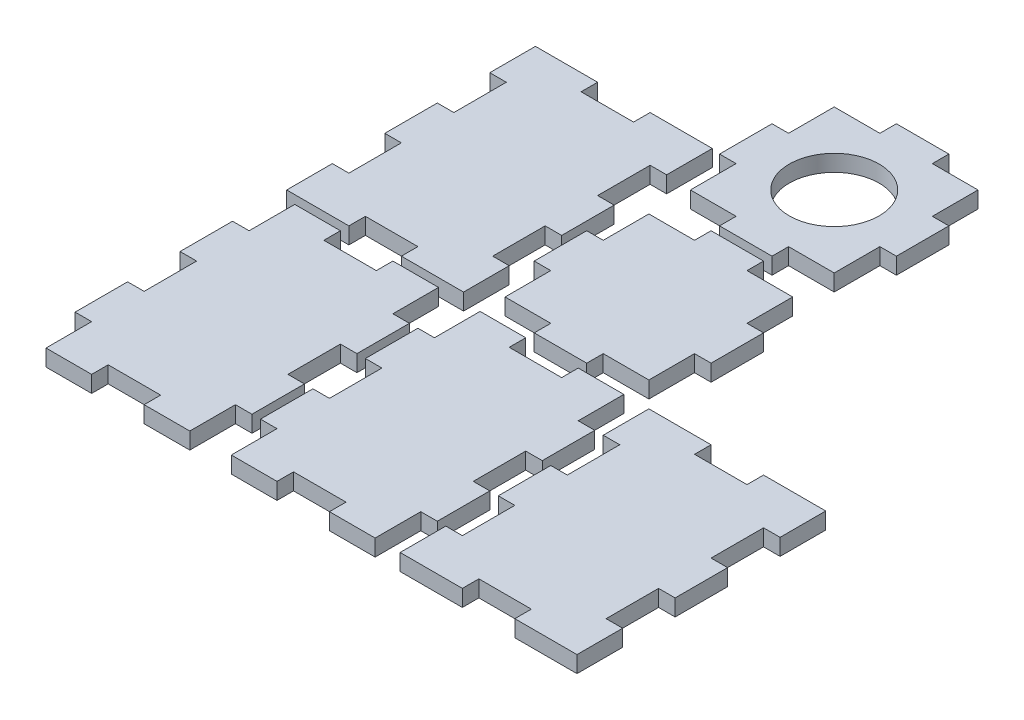
SolidWorks part; units mm, degrees
ref_plane "Front Plane" through (0, 0, 0) normal (0, 0, 1) x (1, 0, 0)
ref_plane "Top Plane" through (0, 0, 0) normal (0, 1, 0) x (1, 0, 0)
ref_plane "Right Plane" through (0, 0, 0) normal (1, 0, 0) x (0, 0, -1)
sketch "Sketch3" plane through (0, 0, 0) normal (0, 1, 0) x (1, 0, 0)
  line L0 (59.6392, 90.8812) -> (43.5102, 90.8812)
  line L1 (43.5102, 90.8812) -> (43.5102, 85.0392)
  line L2 (43.5102, 85.0392) -> (24.9682, 85.0392)
  line L3 (24.9682, 85.0392) -> (24.9682, 90.8812)
  line L4 (24.9682, 90.8812) -> (8.8392, 90.8812)
  line L5 (8.8392, 90.8812) -> (8.8392, 85.0392)
  line L6 (8.8392, 85.0392) -> (8.8392, 74.7522)
  line L7 (8.8392, 74.7522) -> (2.9972, 74.7522)
  line L8 (2.9972, 74.7522) -> (2.9972, 56.2102)
  line L9 (2.9972, 56.2102) -> (8.8392, 56.2102)
  line L10 (8.8392, 56.2102) -> (8.8392, 37.6682)
  line L11 (8.8392, 37.6682) -> (2.9972, 37.6682)
  line L12 (2.9972, 37.6682) -> (2.9972, 19.1262)
  line L13 (2.9972, 19.1262) -> (8.8392, 19.1262)
  line L14 (8.8392, 19.1262) -> (8.8392, 8.8392)
  line L15 (8.8392, 8.8392) -> (8.8392, 2.9972)
  line L16 (8.8392, 2.9972) -> (24.9682, 2.9972)
  line L17 (24.9682, 2.9972) -> (24.9682, 8.8392)
  line L18 (24.9682, 8.8392) -> (43.5102, 8.8392)
  line L19 (43.5102, 8.8392) -> (43.5102, 2.9972)
  line L20 (43.5102, 2.9972) -> (59.6392, 2.9972)
  line L21 (59.6392, 2.9972) -> (59.6392, 8.8392)
  line L22 (59.6392, 8.8392) -> (59.6392, 19.1262)
  line L23 (59.6392, 19.1262) -> (65.4812, 19.1262)
  line L24 (65.4812, 19.1262) -> (65.4812, 37.6682)
  line L25 (65.4812, 37.6682) -> (59.6392, 37.6682)
  line L26 (59.6392, 37.6682) -> (59.6392, 56.2102)
  line L27 (59.6392, 56.2102) -> (65.4812, 56.2102)
  line L28 (65.4812, 56.2102) -> (65.4812, 74.7522)
  line L29 (65.4812, 74.7522) -> (59.6392, 74.7522)
  line L30 (59.6392, 74.7522) -> (59.6392, 85.0392)
  line L31 (59.6392, 85.0392) -> (59.6392, 90.8812)
  line L32 (21.9202, 43.18) -> (20.9804, 43.18)
  line L33 (20.9804, 43.18) -> (20.9804, 50.6984)
  line L34 (20.9804, 50.6984) -> (25.5778, 50.6984)
  line L35 (25.5778, 50.6984) -> (25.5778, 49.911)
  line L36 (25.5778, 49.911) -> (21.9202, 49.911)
  line L37 (21.9202, 49.911) -> (21.9202, 47.3964)
  line L38 (21.9202, 47.3964) -> (25.3238, 47.3964)
  line L39 (25.3238, 47.3964) -> (25.3238, 46.5836)
  line L40 (25.3238, 46.5836) -> (21.9202, 46.5836)
  line L41 (21.9202, 46.5836) -> (21.9202, 43.18)
  line L42 (28.2194, 43.18) -> (27.2796, 43.18)
  line L43 (27.2796, 43.18) -> (27.2796, 48.9204)
  line L44 (27.2796, 48.9204) -> (28.2194, 48.9204)
  line L45 (28.2194, 48.9204) -> (28.2194, 43.18)
  line L46 (28.2194, 45.7708) -> (27.9146, 45.7708)
  line L47 (27.9146, 45.7708) -> (27.9146, 45.974)
  line L48 (27.9146, 45.974) -> (27.94, 46.1772)
  line L49 (27.94, 46.1772) -> (27.94, 46.3804)
  line L50 (27.94, 46.3804) -> (27.9654, 46.5836)
  line L51 (27.9654, 46.5836) -> (27.9654, 46.7614)
  line L52 (27.9654, 46.7614) -> (27.9908, 46.9392)
  line L53 (27.9908, 46.9392) -> (28.0162, 47.117)
  line L54 (28.0162, 47.117) -> (28.067, 47.2694)
  line L55 (28.067, 47.2694) -> (28.0924, 47.4218)
  line L56 (28.0924, 47.4218) -> (28.1432, 47.5742)
  line L57 (28.1432, 47.5742) -> (28.1686, 47.7266)
  line L58 (28.1686, 47.7266) -> (28.2194, 47.8536)
  line L59 (28.2194, 47.8536) -> (28.2702, 47.9806)
  line L60 (28.2702, 47.9806) -> (28.321, 48.1076)
  line L61 (28.321, 48.1076) -> (28.3972, 48.2092)
  line L62 (28.3972, 48.2092) -> (28.448, 48.3108)
  line L63 (28.448, 48.3108) -> (28.5242, 48.4124)
  line L64 (28.5242, 48.4124) -> (28.6004, 48.514)
  line L65 (28.6004, 48.514) -> (28.6766, 48.5902)
  line L66 (28.6766, 48.5902) -> (28.7528, 48.6664)
  line L67 (28.7528, 48.6664) -> (28.829, 48.7172)
  line L68 (28.829, 48.7172) -> (28.9052, 48.7934)
  line L69 (28.9052, 48.7934) -> (29.0068, 48.8442)
  line L70 (29.0068, 48.8442) -> (29.1084, 48.895)
  line L71 (29.1084, 48.895) -> (29.1846, 48.9204)
  line L72 (29.1846, 48.9204) -> (29.2862, 48.9712)
  line L73 (29.2862, 48.9712) -> (29.3878, 48.9966)
  line L74 (29.3878, 48.9966) -> (29.5148, 48.9966)
  line L75 (29.5148, 48.9966) -> (29.6164, 49.022)
  line L76 (29.6164, 49.022) -> (29.7434, 49.022)
  line L77 (29.7434, 49.022) -> (29.7688, 49.022)
  line L78 (29.7688, 49.022) -> (29.8196, 49.022)
  line L79 (29.8196, 49.022) -> (29.845, 49.022)
  line L80 (29.845, 49.022) -> (29.8704, 49.022)
  line L81 (29.8704, 49.022) -> (29.9212, 49.022)
  line L82 (29.9212, 49.022) -> (29.9466, 48.9966)
  line L83 (29.9466, 48.9966) -> (29.9974, 48.9966)
  line L84 (29.9974, 48.9966) -> (30.0228, 48.9966)
  line L85 (30.0228, 48.9966) -> (30.0482, 48.9966)
  line L86 (30.0482, 48.9966) -> (30.0736, 48.9966)
  line L87 (30.0736, 48.9966) -> (30.1244, 48.9966)
  line L88 (30.1244, 48.9966) -> (30.1498, 48.9712)
  line L89 (30.1498, 48.9712) -> (30.1752, 48.9712)
  line L90 (30.1752, 48.9712) -> (30.2006, 48.9712)
  line L91 (30.2006, 48.9712) -> (30.2514, 48.9458)
  line L92 (30.2514, 48.9458) -> (30.2768, 48.9458)
  line L93 (30.2768, 48.9458) -> (30.3022, 48.9458)
  line L94 (30.3022, 48.9458) -> (30.353, 48.9204)
  line L95 (30.353, 48.9204) -> (30.3784, 48.9204)
  line L96 (30.3784, 48.9204) -> (30.4038, 48.9204)
  line L97 (30.4038, 48.9204) -> (30.353, 47.9806)
  line L98 (30.353, 47.9806) -> (30.3022, 48.006)
  line L99 (30.3022, 48.006) -> (30.2768, 48.006)
  line L100 (30.2768, 48.006) -> (30.2514, 48.006)
  line L101 (30.2514, 48.006) -> (30.2006, 48.0314)
  line L102 (30.2006, 48.0314) -> (30.1752, 48.0314)
  line L103 (30.1752, 48.0314) -> (30.1244, 48.0568)
  line L104 (30.1244, 48.0568) -> (30.099, 48.0568)
  line L105 (30.099, 48.0568) -> (30.0482, 48.0568)
  line L106 (30.0482, 48.0568) -> (30.0228, 48.0822)
  line L107 (30.0228, 48.0822) -> (29.972, 48.0822)
  line L108 (29.972, 48.0822) -> (29.9466, 48.0822)
  line L109 (29.9466, 48.0822) -> (29.8958, 48.0822)
  line L110 (29.8958, 48.0822) -> (29.8704, 48.1076)
  line L111 (29.8704, 48.1076) -> (29.8196, 48.1076)
  line L112 (29.8196, 48.1076) -> (29.7942, 48.1076)
  line L113 (29.7942, 48.1076) -> (29.7688, 48.1076)
  line L114 (29.7688, 48.1076) -> (29.718, 48.1076)
  line L115 (29.718, 48.1076) -> (29.6926, 48.1076)
  line L116 (29.6926, 48.1076) -> (29.6672, 48.1076)
  line L117 (29.6672, 48.1076) -> (29.6164, 48.1076)
  line L118 (29.6164, 48.1076) -> (29.5148, 48.1076)
  line L119 (29.5148, 48.1076) -> (29.4386, 48.1076)
  line L120 (29.4386, 48.1076) -> (29.337, 48.0822)
  line L121 (29.337, 48.0822) -> (29.2608, 48.0822)
  line L122 (29.2608, 48.0822) -> (29.1592, 48.0568)
  line L123 (29.1592, 48.0568) -> (29.083, 48.006)
  line L124 (29.083, 48.006) -> (29.0068, 47.9806)
  line L125 (29.0068, 47.9806) -> (28.9306, 47.9298)
  line L126 (28.9306, 47.9298) -> (28.8798, 47.879)
  line L127 (28.8798, 47.879) -> (28.8036, 47.8282)
  line L128 (28.8036, 47.8282) -> (28.7528, 47.7774)
  line L129 (28.7528, 47.7774) -> (28.6766, 47.7012)
  line L130 (28.6766, 47.7012) -> (28.6258, 47.625)
  line L131 (28.6258, 47.625) -> (28.575, 47.5488)
  line L132 (28.575, 47.5488) -> (28.5242, 47.4726)
  line L133 (28.5242, 47.4726) -> (28.4988, 47.3964)
  line L134 (28.4988, 47.3964) -> (28.448, 47.2948)
  line L135 (28.448, 47.2948) -> (28.4226, 47.2186)
  line L136 (28.4226, 47.2186) -> (28.3718, 47.117)
  line L137 (28.3718, 47.117) -> (28.3464, 47.0154)
  line L138 (28.3464, 47.0154) -> (28.321, 46.8884)
  line L139 (28.321, 46.8884) -> (28.2956, 46.7868)
  line L140 (28.2956, 46.7868) -> (28.2702, 46.6852)
  line L141 (28.2702, 46.6852) -> (28.2702, 46.5582)
  line L142 (28.2702, 46.5582) -> (28.2448, 46.4312)
  line L143 (28.2448, 46.4312) -> (28.2194, 46.3042)
  line L144 (28.2194, 46.3042) -> (28.2194, 46.1772)
  line L145 (28.2194, 46.1772) -> (28.2194, 46.0502)
  line L146 (28.2194, 46.0502) -> (28.2194, 45.8978)
  line L147 (28.2194, 45.8978) -> (28.2194, 45.7708)
  line L148 (33.6804, 43.0276) -> (33.528, 43.0276)
  line L149 (33.528, 43.0276) -> (33.3756, 43.053)
  line L150 (33.3756, 43.053) -> (33.2486, 43.053)
  line L151 (33.2486, 43.053) -> (33.0962, 43.0784)
  line L152 (33.0962, 43.0784) -> (32.9438, 43.1038)
  line L153 (32.9438, 43.1038) -> (32.8168, 43.1546)
  line L154 (32.8168, 43.1546) -> (32.6898, 43.2054)
  line L155 (32.6898, 43.2054) -> (32.5628, 43.2562)
  line L156 (32.5628, 43.2562) -> (32.4358, 43.307)
  line L157 (32.4358, 43.307) -> (32.3088, 43.3832)
  line L158 (32.3088, 43.3832) -> (32.1818, 43.434)
  line L159 (32.1818, 43.434) -> (32.0802, 43.5102)
  line L160 (32.0802, 43.5102) -> (31.9786, 43.6118)
  line L161 (31.9786, 43.6118) -> (31.877, 43.688)
  line L162 (31.877, 43.688) -> (31.7754, 43.7896)
  line L163 (31.7754, 43.7896) -> (31.6738, 43.8912)
  line L164 (31.6738, 43.8912) -> (31.5976, 44.0182)
  line L165 (31.5976, 44.0182) -> (31.496, 44.1198)
  line L166 (31.496, 44.1198) -> (31.4198, 44.2468)
  line L167 (31.4198, 44.2468) -> (31.369, 44.3738)
  line L168 (31.369, 44.3738) -> (31.2928, 44.5262)
  line L169 (31.2928, 44.5262) -> (31.242, 44.6786)
  line L170 (31.242, 44.6786) -> (31.1912, 44.8056)
  line L171 (31.1912, 44.8056) -> (31.1404, 44.9834)
  line L172 (31.1404, 44.9834) -> (31.0896, 45.1358)
  line L173 (31.0896, 45.1358) -> (31.0642, 45.3136)
  line L174 (31.0642, 45.3136) -> (31.0388, 45.4914)
  line L175 (31.0388, 45.4914) -> (31.0134, 45.6692)
  line L176 (31.0134, 45.6692) -> (31.0134, 45.847)
  line L177 (31.0134, 45.847) -> (31.0134, 46.0502)
  line L178 (31.0134, 46.0502) -> (31.0134, 46.228)
  line L179 (31.0134, 46.228) -> (31.0134, 46.4312)
  line L180 (31.0134, 46.4312) -> (31.0388, 46.609)
  line L181 (31.0388, 46.609) -> (31.0642, 46.7868)
  line L182 (31.0642, 46.7868) -> (31.0896, 46.9646)
  line L183 (31.0896, 46.9646) -> (31.1404, 47.117)
  line L184 (31.1404, 47.117) -> (31.1912, 47.2694)
  line L185 (31.1912, 47.2694) -> (31.242, 47.4218)
  line L186 (31.242, 47.4218) -> (31.2928, 47.5742)
  line L187 (31.2928, 47.5742) -> (31.369, 47.7012)
  line L188 (31.369, 47.7012) -> (31.4198, 47.8282)
  line L189 (31.4198, 47.8282) -> (31.496, 47.9552)
  line L190 (31.496, 47.9552) -> (31.5976, 48.0822)
  line L191 (31.5976, 48.0822) -> (31.6738, 48.1838)
  line L192 (31.6738, 48.1838) -> (31.7754, 48.2854)
  line L193 (31.7754, 48.2854) -> (31.877, 48.387)
  line L194 (31.877, 48.387) -> (31.9786, 48.4886)
  line L195 (31.9786, 48.4886) -> (32.0802, 48.5648)
  line L196 (32.0802, 48.5648) -> (32.1818, 48.641)
  line L197 (32.1818, 48.641) -> (32.3088, 48.7172)
  line L198 (32.3088, 48.7172) -> (32.4358, 48.768)
  line L199 (32.4358, 48.768) -> (32.5628, 48.8442)
  line L200 (32.5628, 48.8442) -> (32.6898, 48.895)
  line L201 (32.6898, 48.895) -> (32.8168, 48.9204)
  line L202 (32.8168, 48.9204) -> (32.9438, 48.9712)
  line L203 (32.9438, 48.9712) -> (33.0962, 48.9966)
  line L204 (33.0962, 48.9966) -> (33.2486, 49.022)
  line L205 (33.2486, 49.022) -> (33.3756, 49.0474)
  line L206 (33.3756, 49.0474) -> (33.528, 49.0474)
  line L207 (33.528, 49.0474) -> (33.6804, 49.0474)
  line L208 (33.6804, 49.0474) -> (33.8328, 49.0474)
  line L209 (33.8328, 49.0474) -> (33.9852, 49.0474)
  line L210 (33.9852, 49.0474) -> (34.1376, 49.022)
  line L211 (34.1376, 49.022) -> (34.2646, 48.9966)
  line L212 (34.2646, 48.9966) -> (34.417, 48.9712)
  line L213 (34.417, 48.9712) -> (34.544, 48.9204)
  line L214 (34.544, 48.9204) -> (34.671, 48.895)
  line L215 (34.671, 48.895) -> (34.798, 48.8442)
  line L216 (34.798, 48.8442) -> (34.925, 48.768)
  line L217 (34.925, 48.768) -> (35.052, 48.7172)
  line L218 (35.052, 48.7172) -> (35.179, 48.641)
  line L219 (35.179, 48.641) -> (35.2806, 48.5648)
  line L220 (35.2806, 48.5648) -> (35.4076, 48.4886)
  line L221 (35.4076, 48.4886) -> (35.5092, 48.387)
  line L222 (35.5092, 48.387) -> (35.5854, 48.2854)
  line L223 (35.5854, 48.2854) -> (35.687, 48.1838)
  line L224 (35.687, 48.1838) -> (35.7886, 48.0822)
  line L225 (35.7886, 48.0822) -> (35.8648, 47.9552)
  line L226 (35.8648, 47.9552) -> (35.941, 47.8282)
  line L227 (35.941, 47.8282) -> (36.0172, 47.7012)
  line L228 (36.0172, 47.7012) -> (36.068, 47.5742)
  line L229 (36.068, 47.5742) -> (36.1188, 47.4218)
  line L230 (36.1188, 47.4218) -> (36.1696, 47.2694)
  line L231 (36.1696, 47.2694) -> (36.2204, 47.117)
  line L232 (36.2204, 47.117) -> (36.2712, 46.9646)
  line L233 (36.2712, 46.9646) -> (36.2966, 46.7868)
  line L234 (36.2966, 46.7868) -> (36.322, 46.609)
  line L235 (36.322, 46.609) -> (36.3474, 46.4312)
  line L236 (36.3474, 46.4312) -> (36.3474, 46.228)
  line L237 (36.3474, 46.228) -> (36.3474, 46.0502)
  line L238 (36.3474, 46.0502) -> (36.3474, 45.847)
  line L239 (36.3474, 45.847) -> (36.3474, 45.6692)
  line L240 (36.3474, 45.6692) -> (36.322, 45.4914)
  line L241 (36.322, 45.4914) -> (36.2966, 45.3136)
  line L242 (36.2966, 45.3136) -> (36.2712, 45.1358)
  line L243 (36.2712, 45.1358) -> (36.2204, 44.9834)
  line L244 (36.2204, 44.9834) -> (36.1696, 44.8056)
  line L245 (36.1696, 44.8056) -> (36.1188, 44.6786)
  line L246 (36.1188, 44.6786) -> (36.068, 44.5262)
  line L247 (36.068, 44.5262) -> (36.0172, 44.3738)
  line L248 (36.0172, 44.3738) -> (35.941, 44.2468)
  line L249 (35.941, 44.2468) -> (35.8648, 44.1198)
  line L250 (35.8648, 44.1198) -> (35.7886, 44.0182)
  line L251 (35.7886, 44.0182) -> (35.687, 43.8912)
  line L252 (35.687, 43.8912) -> (35.5854, 43.7896)
  line L253 (35.5854, 43.7896) -> (35.5092, 43.688)
  line L254 (35.5092, 43.688) -> (35.4076, 43.6118)
  line L255 (35.4076, 43.6118) -> (35.2806, 43.5102)
  line L256 (35.2806, 43.5102) -> (35.179, 43.434)
  line L257 (35.179, 43.434) -> (35.052, 43.3832)
  line L258 (35.052, 43.3832) -> (34.925, 43.307)
  line L259 (34.925, 43.307) -> (34.798, 43.2562)
  line L260 (34.798, 43.2562) -> (34.671, 43.2054)
  line L261 (34.671, 43.2054) -> (34.544, 43.1546)
  line L262 (34.544, 43.1546) -> (34.417, 43.1038)
  line L263 (34.417, 43.1038) -> (34.2646, 43.0784)
  line L264 (34.2646, 43.0784) -> (34.1376, 43.053)
  line L265 (34.1376, 43.053) -> (33.9852, 43.053)
  line L266 (33.9852, 43.053) -> (33.8328, 43.0276)
  line L267 (33.8328, 43.0276) -> (33.6804, 43.0276)
  line L268 (33.655, 43.8404) -> (33.782, 43.8404)
  line L269 (33.782, 43.8404) -> (33.8836, 43.8658)
  line L270 (33.8836, 43.8658) -> (33.9852, 43.8658)
  line L271 (33.9852, 43.8658) -> (34.0868, 43.8912)
  line L272 (34.0868, 43.8912) -> (34.1884, 43.9166)
  line L273 (34.1884, 43.9166) -> (34.2646, 43.942)
  line L274 (34.2646, 43.942) -> (34.3662, 43.9674)
  line L275 (34.3662, 43.9674) -> (34.4424, 44.0182)
  line L276 (34.4424, 44.0182) -> (34.544, 44.069)
  line L277 (34.544, 44.069) -> (34.6202, 44.1198)
  line L278 (34.6202, 44.1198) -> (34.6964, 44.1706)
  line L279 (34.6964, 44.1706) -> (34.7472, 44.2214)
  line L280 (34.7472, 44.2214) -> (34.8234, 44.2976)
  line L281 (34.8234, 44.2976) -> (34.8996, 44.3738)
  line L282 (34.8996, 44.3738) -> (34.9504, 44.4246)
  line L283 (34.9504, 44.4246) -> (35.0012, 44.5262)
  line L284 (35.0012, 44.5262) -> (35.052, 44.6024)
  line L285 (35.052, 44.6024) -> (35.1028, 44.6786)
  line L286 (35.1028, 44.6786) -> (35.1536, 44.7802)
  line L287 (35.1536, 44.7802) -> (35.2044, 44.8818)
  line L288 (35.2044, 44.8818) -> (35.2298, 44.9834)
  line L289 (35.2298, 44.9834) -> (35.2806, 45.085)
  line L290 (35.2806, 45.085) -> (35.306, 45.1866)
  line L291 (35.306, 45.1866) -> (35.3314, 45.2882)
  line L292 (35.3314, 45.2882) -> (35.3568, 45.4152)
  line L293 (35.3568, 45.4152) -> (35.3822, 45.5422)
  line L294 (35.3822, 45.5422) -> (35.3822, 45.6438)
  line L295 (35.3822, 45.6438) -> (35.4076, 45.7708)
  line L296 (35.4076, 45.7708) -> (35.4076, 45.8978)
  line L297 (35.4076, 45.8978) -> (35.4076, 46.0502)
  line L298 (35.4076, 46.0502) -> (35.4076, 46.2534)
  line L299 (35.4076, 46.2534) -> (35.3822, 46.4312)
  line L300 (35.3822, 46.4312) -> (35.3568, 46.609)
  line L301 (35.3568, 46.609) -> (35.3314, 46.7868)
  line L302 (35.3314, 46.7868) -> (35.306, 46.9646)
  line L303 (35.306, 46.9646) -> (35.2552, 47.117)
  line L304 (35.2552, 47.117) -> (35.2044, 47.2694)
  line L305 (35.2044, 47.2694) -> (35.1282, 47.3964)
  line L306 (35.1282, 47.3964) -> (35.052, 47.5488)
  line L307 (35.052, 47.5488) -> (34.9758, 47.6504)
  line L308 (34.9758, 47.6504) -> (34.8996, 47.7774)
  line L309 (34.8996, 47.7774) -> (34.798, 47.879)
  line L310 (34.798, 47.879) -> (34.6964, 47.9552)
  line L311 (34.6964, 47.9552) -> (34.5694, 48.0314)
  line L312 (34.5694, 48.0314) -> (34.4424, 48.1076)
  line L313 (34.4424, 48.1076) -> (34.3154, 48.1584)
  line L314 (34.3154, 48.1584) -> (34.1884, 48.2092)
  line L315 (34.1884, 48.2092) -> (34.036, 48.2346)
  line L316 (34.036, 48.2346) -> (33.8836, 48.2346)
  line L317 (33.8836, 48.2346) -> (33.7058, 48.26)
  line L318 (33.7058, 48.26) -> (33.6042, 48.26)
  line L319 (33.6042, 48.26) -> (33.5026, 48.2346)
  line L320 (33.5026, 48.2346) -> (33.401, 48.2346)
  line L321 (33.401, 48.2346) -> (33.2994, 48.2092)
  line L322 (33.2994, 48.2092) -> (33.1978, 48.1838)
  line L323 (33.1978, 48.1838) -> (33.0962, 48.1584)
  line L324 (33.0962, 48.1584) -> (33.02, 48.1076)
  line L325 (33.02, 48.1076) -> (32.9184, 48.0822)
  line L326 (32.9184, 48.0822) -> (32.8422, 48.0314)
  line L327 (32.8422, 48.0314) -> (32.766, 47.9806)
  line L328 (32.766, 47.9806) -> (32.6898, 47.9298)
  line L329 (32.6898, 47.9298) -> (32.6136, 47.879)
  line L330 (32.6136, 47.879) -> (32.5374, 47.8028)
  line L331 (32.5374, 47.8028) -> (32.4866, 47.7266)
  line L332 (32.4866, 47.7266) -> (32.4104, 47.6504)
  line L333 (32.4104, 47.6504) -> (32.3596, 47.5742)
  line L334 (32.3596, 47.5742) -> (32.3088, 47.498)
  line L335 (32.3088, 47.498) -> (32.258, 47.4218)
  line L336 (32.258, 47.4218) -> (32.2072, 47.3202)
  line L337 (32.2072, 47.3202) -> (32.1818, 47.2186)
  line L338 (32.1818, 47.2186) -> (32.131, 47.117)
  line L339 (32.131, 47.117) -> (32.1056, 47.0154)
  line L340 (32.1056, 47.0154) -> (32.0802, 46.9138)
  line L341 (32.0802, 46.9138) -> (32.0548, 46.7868)
  line L342 (32.0548, 46.7868) -> (32.0294, 46.6852)
  line L343 (32.0294, 46.6852) -> (32.004, 46.5582)
  line L344 (32.004, 46.5582) -> (31.9786, 46.4312)
  line L345 (31.9786, 46.4312) -> (31.9786, 46.3042)
  line L346 (31.9786, 46.3042) -> (31.9786, 46.1772)
  line L347 (31.9786, 46.1772) -> (31.9786, 46.0502)
  line L348 (31.9786, 46.0502) -> (31.9786, 45.847)
  line L349 (31.9786, 45.847) -> (31.9786, 45.6438)
  line L350 (31.9786, 45.6438) -> (32.004, 45.466)
  line L351 (32.004, 45.466) -> (32.0294, 45.2882)
  line L352 (32.0294, 45.2882) -> (32.0802, 45.1358)
  line L353 (32.0802, 45.1358) -> (32.131, 44.9834)
  line L354 (32.131, 44.9834) -> (32.1818, 44.831)
  line L355 (32.1818, 44.831) -> (32.258, 44.6786)
  line L356 (32.258, 44.6786) -> (32.3088, 44.5516)
  line L357 (32.3088, 44.5516) -> (32.4104, 44.45)
  line L358 (32.4104, 44.45) -> (32.4866, 44.323)
  line L359 (32.4866, 44.323) -> (32.5882, 44.2214)
  line L360 (32.5882, 44.2214) -> (32.6898, 44.1452)
  line L361 (32.6898, 44.1452) -> (32.8168, 44.069)
  line L362 (32.8168, 44.069) -> (32.9184, 43.9928)
  line L363 (32.9184, 43.9928) -> (33.0708, 43.942)
  line L364 (33.0708, 43.942) -> (33.1978, 43.8912)
  line L365 (33.1978, 43.8912) -> (33.3502, 43.8658)
  line L366 (33.3502, 43.8658) -> (33.5026, 43.8404)
  line L367 (33.5026, 43.8404) -> (33.655, 43.8404)
  line L368 (43.18, 43.18) -> (42.2402, 43.18)
  line L369 (42.2402, 43.18) -> (42.2402, 46.5582)
  line L370 (42.2402, 46.5582) -> (42.2402, 46.7106)
  line L371 (42.2402, 46.7106) -> (42.2402, 46.863)
  line L372 (42.2402, 46.863) -> (42.2148, 47.0154)
  line L373 (42.2148, 47.0154) -> (42.1894, 47.1424)
  line L374 (42.1894, 47.1424) -> (42.1386, 47.2694)
  line L375 (42.1386, 47.2694) -> (42.1132, 47.3964)
  line L376 (42.1132, 47.3964) -> (42.0624, 47.498)
  line L377 (42.0624, 47.498) -> (41.9862, 47.5996)
  line L378 (41.9862, 47.5996) -> (41.9354, 47.7012)
  line L379 (41.9354, 47.7012) -> (41.8592, 47.8028)
  line L380 (41.8592, 47.8028) -> (41.783, 47.879)
  line L381 (41.783, 47.879) -> (41.6814, 47.9552)
  line L382 (41.6814, 47.9552) -> (41.6052, 48.006)
  line L383 (41.6052, 48.006) -> (41.5036, 48.0822)
  line L384 (41.5036, 48.0822) -> (41.402, 48.1076)
  line L385 (41.402, 48.1076) -> (41.275, 48.1584)
  line L386 (41.275, 48.1584) -> (41.1734, 48.1838)
  line L387 (41.1734, 48.1838) -> (41.0464, 48.2092)
  line L388 (41.0464, 48.2092) -> (40.9194, 48.2346)
  line L389 (40.9194, 48.2346) -> (40.7924, 48.2346)
  line L390 (40.7924, 48.2346) -> (40.6908, 48.2346)
  line L391 (40.6908, 48.2346) -> (40.5892, 48.2092)
  line L392 (40.5892, 48.2092) -> (40.4876, 48.2092)
  line L393 (40.4876, 48.2092) -> (40.386, 48.1838)
  line L394 (40.386, 48.1838) -> (40.3098, 48.1584)
  line L395 (40.3098, 48.1584) -> (40.2082, 48.133)
  line L396 (40.2082, 48.133) -> (40.132, 48.0822)
  line L397 (40.132, 48.0822) -> (40.0558, 48.0568)
  line L398 (40.0558, 48.0568) -> (39.9796, 48.006)
  line L399 (39.9796, 48.006) -> (39.9034, 47.9552)
  line L400 (39.9034, 47.9552) -> (39.8272, 47.879)
  line L401 (39.8272, 47.879) -> (39.751, 47.8282)
  line L402 (39.751, 47.8282) -> (39.6748, 47.752)
  line L403 (39.6748, 47.752) -> (39.624, 47.6758)
  line L404 (39.624, 47.6758) -> (39.5478, 47.5996)
  line L405 (39.5478, 47.5996) -> (39.497, 47.5234)
  line L406 (39.497, 47.5234) -> (39.4462, 47.4218)
  line L407 (39.4462, 47.4218) -> (39.3954, 47.3456)
  line L408 (39.3954, 47.3456) -> (39.3446, 47.244)
  line L409 (39.3446, 47.244) -> (39.3192, 47.1424)
  line L410 (39.3192, 47.1424) -> (39.2684, 47.0408)
  line L411 (39.2684, 47.0408) -> (39.243, 46.9138)
  line L412 (39.243, 46.9138) -> (39.2176, 46.8122)
  line L413 (39.2176, 46.8122) -> (39.1668, 46.6852)
  line L414 (39.1668, 46.6852) -> (39.1668, 46.5582)
  line L415 (39.1668, 46.5582) -> (39.1414, 46.4312)
  line L416 (39.1414, 46.4312) -> (39.116, 46.3042)
  line L417 (39.116, 46.3042) -> (39.116, 46.1772)
  line L418 (39.116, 46.1772) -> (39.116, 46.0248)
  line L419 (39.116, 46.0248) -> (39.116, 45.8978)
  line L420 (39.116, 45.8978) -> (38.735, 45.8978)
  line L421 (38.735, 45.8978) -> (38.7604, 46.0756)
  line L422 (38.7604, 46.0756) -> (38.7604, 46.2788)
  line L423 (38.7604, 46.2788) -> (38.7604, 46.4566)
  line L424 (38.7604, 46.4566) -> (38.7858, 46.6344)
  line L425 (38.7858, 46.6344) -> (38.8112, 46.8122)
  line L426 (38.8112, 46.8122) -> (38.8366, 46.99)
  line L427 (38.8366, 46.99) -> (38.862, 47.1424)
  line L428 (38.862, 47.1424) -> (38.9128, 47.2948)
  line L429 (38.9128, 47.2948) -> (38.9636, 47.4472)
  line L430 (38.9636, 47.4472) -> (39.0144, 47.5996)
  line L431 (39.0144, 47.5996) -> (39.0652, 47.7266)
  line L432 (39.0652, 47.7266) -> (39.116, 47.8536)
  line L433 (39.116, 47.8536) -> (39.1922, 47.9806)
  line L434 (39.1922, 47.9806) -> (39.2684, 48.1076)
  line L435 (39.2684, 48.1076) -> (39.3446, 48.2092)
  line L436 (39.3446, 48.2092) -> (39.4208, 48.3362)
  line L437 (39.4208, 48.3362) -> (39.497, 48.4124)
  line L438 (39.497, 48.4124) -> (39.5986, 48.514)
  line L439 (39.5986, 48.514) -> (39.6748, 48.5902)
  line L440 (39.6748, 48.5902) -> (39.7764, 48.6918)
  line L441 (39.7764, 48.6918) -> (39.878, 48.7426)
  line L442 (39.878, 48.7426) -> (39.9796, 48.8188)
  line L443 (39.9796, 48.8188) -> (40.1066, 48.8696)
  line L444 (40.1066, 48.8696) -> (40.2082, 48.9204)
  line L445 (40.2082, 48.9204) -> (40.3352, 48.9712)
  line L446 (40.3352, 48.9712) -> (40.4622, 48.9966)
  line L447 (40.4622, 48.9966) -> (40.5892, 49.022)
  line L448 (40.5892, 49.022) -> (40.7416, 49.0474)
  line L449 (40.7416, 49.0474) -> (40.8686, 49.0474)
  line L450 (40.8686, 49.0474) -> (41.021, 49.0474)
  line L451 (41.021, 49.0474) -> (41.148, 49.0474)
  line L452 (41.148, 49.0474) -> (41.275, 49.0474)
  line L453 (41.275, 49.0474) -> (41.402, 49.022)
  line L454 (41.402, 49.022) -> (41.529, 48.9966)
  line L455 (41.529, 48.9966) -> (41.6306, 48.9712)
  line L456 (41.6306, 48.9712) -> (41.7576, 48.9458)
  line L457 (41.7576, 48.9458) -> (41.8592, 48.895)
  line L458 (41.8592, 48.895) -> (41.9608, 48.8696)
  line L459 (41.9608, 48.8696) -> (42.0878, 48.8188)
  line L460 (42.0878, 48.8188) -> (42.164, 48.7426)
  line L461 (42.164, 48.7426) -> (42.2656, 48.6918)
  line L462 (42.2656, 48.6918) -> (42.3672, 48.6156)
  line L463 (42.3672, 48.6156) -> (42.4434, 48.5394)
  line L464 (42.4434, 48.5394) -> (42.5196, 48.4632)
  line L465 (42.5196, 48.4632) -> (42.5958, 48.387)
  line L466 (42.5958, 48.387) -> (42.672, 48.2854)
  line L467 (42.672, 48.2854) -> (42.7482, 48.2092)
  line L468 (42.7482, 48.2092) -> (42.799, 48.1076)
  line L469 (42.799, 48.1076) -> (42.8498, 48.006)
  line L470 (42.8498, 48.006) -> (42.926, 47.879)
  line L471 (42.926, 47.879) -> (42.9768, 47.7774)
  line L472 (42.9768, 47.7774) -> (43.0022, 47.6504)
  line L473 (43.0022, 47.6504) -> (43.053, 47.5234)
  line L474 (43.053, 47.5234) -> (43.0784, 47.3964)
  line L475 (43.0784, 47.3964) -> (43.1038, 47.2694)
  line L476 (43.1038, 47.2694) -> (43.1292, 47.1424)
  line L477 (43.1292, 47.1424) -> (43.1546, 46.99)
  line L478 (43.1546, 46.99) -> (43.1546, 46.8376)
  line L479 (43.1546, 46.8376) -> (43.18, 46.7106)
  line L480 (43.18, 46.7106) -> (43.18, 46.5582)
  line L481 (43.18, 46.5582) -> (43.18, 43.18)
  line L482 (39.116, 43.18) -> (38.1762, 43.18)
  line L483 (38.1762, 43.18) -> (38.1762, 48.9204)
  line L484 (38.1762, 48.9204) -> (38.9636, 48.9204)
  line L485 (38.9636, 48.9204) -> (39.116, 47.5996)
  line L486 (39.116, 47.5996) -> (39.116, 43.18)
  line L487 (47.1678, 43.0276) -> (47.0916, 43.0276)
  line L488 (47.0916, 43.0276) -> (46.99, 43.0276)
  line L489 (46.99, 43.0276) -> (46.9138, 43.053)
  line L490 (46.9138, 43.053) -> (46.8122, 43.053)
  line L491 (46.8122, 43.053) -> (46.736, 43.0784)
  line L492 (46.736, 43.0784) -> (46.6598, 43.1038)
  line L493 (46.6598, 43.1038) -> (46.5582, 43.1292)
  line L494 (46.5582, 43.1292) -> (46.482, 43.1546)
  line L495 (46.482, 43.1546) -> (46.4058, 43.18)
  line L496 (46.4058, 43.18) -> (46.3296, 43.2054)
  line L497 (46.3296, 43.2054) -> (46.2534, 43.2562)
  line L498 (46.2534, 43.2562) -> (46.2026, 43.2816)
  line L499 (46.2026, 43.2816) -> (46.1264, 43.3324)
  line L500 (46.1264, 43.3324) -> (46.0502, 43.3832)
  line L501 (46.0502, 43.3832) -> (45.9994, 43.434)
  line L502 (45.9994, 43.434) -> (45.9486, 43.4848)
  line L503 (45.9486, 43.4848) -> (45.8978, 43.561)
  line L504 (45.8978, 43.561) -> (45.847, 43.6118)
  line L505 (45.847, 43.6118) -> (45.7962, 43.688)
  line L506 (45.7962, 43.688) -> (45.7454, 43.7388)
  line L507 (45.7454, 43.7388) -> (45.6946, 43.815)
  line L508 (45.6946, 43.815) -> (45.6692, 43.8912)
  line L509 (45.6692, 43.8912) -> (45.6438, 43.9928)
  line L510 (45.6438, 43.9928) -> (45.6184, 44.069)
  line L511 (45.6184, 44.069) -> (45.593, 44.1452)
  line L512 (45.593, 44.1452) -> (45.5676, 44.2468)
  line L513 (45.5676, 44.2468) -> (45.5422, 44.3484)
  line L514 (45.5422, 44.3484) -> (45.5422, 44.45)
  line L515 (45.5422, 44.45) -> (45.5422, 44.5516)
  line L516 (45.5422, 44.5516) -> (45.5422, 44.6532)
  line L517 (45.5422, 44.6532) -> (45.5422, 50.4952)
  line L518 (45.5422, 50.4952) -> (46.4566, 50.4952)
  line L519 (46.4566, 50.4952) -> (46.4566, 44.6786)
  line L520 (46.4566, 44.6786) -> (46.4566, 44.5008)
  line L521 (46.4566, 44.5008) -> (46.482, 44.3484)
  line L522 (46.482, 44.3484) -> (46.5328, 44.2214)
  line L523 (46.5328, 44.2214) -> (46.5836, 44.0944)
  line L524 (46.5836, 44.0944) -> (46.6598, 44.0182)
  line L525 (46.6598, 44.0182) -> (46.7614, 43.9166)
  line L526 (46.7614, 43.9166) -> (46.863, 43.8658)
  line L527 (46.863, 43.8658) -> (46.99, 43.815)
  line L528 (46.99, 43.815) -> (47.117, 43.7896)
  line L529 (47.117, 43.7896) -> (47.2948, 43.7896)
  line L530 (47.2948, 43.7896) -> (47.3202, 43.7896)
  line L531 (47.3202, 43.7896) -> (47.371, 43.7896)
  line L532 (47.371, 43.7896) -> (47.4218, 43.7896)
  line L533 (47.4218, 43.7896) -> (47.4726, 43.7896)
  line L534 (47.4726, 43.7896) -> (47.5234, 43.7896)
  line L535 (47.5234, 43.7896) -> (47.5742, 43.815)
  line L536 (47.5742, 43.815) -> (47.625, 43.815)
  line L537 (47.625, 43.815) -> (47.6758, 43.815)
  line L538 (47.6758, 43.815) -> (47.7012, 43.8404)
  line L539 (47.7012, 43.8404) -> (47.752, 43.8404)
  line L540 (47.752, 43.8404) -> (47.8028, 43.8404)
  line L541 (47.8028, 43.8404) -> (47.8536, 43.8658)
  line L542 (47.8536, 43.8658) -> (47.9044, 43.8658)
  line L543 (47.9044, 43.8658) -> (47.9552, 43.8912)
  line L544 (47.9552, 43.8912) -> (48.006, 43.9166)
  line L545 (48.006, 43.9166) -> (48.0568, 43.9166)
  line L546 (48.0568, 43.9166) -> (48.1076, 43.942)
  line L547 (48.1076, 43.942) -> (48.1584, 43.9674)
  line L548 (48.1584, 43.9674) -> (48.2346, 43.9928)
  line L549 (48.2346, 43.9928) -> (48.2854, 43.9928)
  line L550 (48.2854, 43.9928) -> (48.4124, 43.3324)
  line L551 (48.4124, 43.3324) -> (48.3616, 43.307)
  line L552 (48.3616, 43.307) -> (48.2854, 43.2816)
  line L553 (48.2854, 43.2816) -> (48.2346, 43.2562)
  line L554 (48.2346, 43.2562) -> (48.1584, 43.2308)
  line L555 (48.1584, 43.2308) -> (48.1076, 43.2054)
  line L556 (48.1076, 43.2054) -> (48.0568, 43.18)
  line L557 (48.0568, 43.18) -> (47.9806, 43.18)
  line L558 (47.9806, 43.18) -> (47.9298, 43.1546)
  line L559 (47.9298, 43.1546) -> (47.8536, 43.1292)
  line L560 (47.8536, 43.1292) -> (47.8028, 43.1038)
  line L561 (47.8028, 43.1038) -> (47.752, 43.1038)
  line L562 (47.752, 43.1038) -> (47.6758, 43.0784)
  line L563 (47.6758, 43.0784) -> (47.625, 43.0784)
  line L564 (47.625, 43.0784) -> (47.5488, 43.053)
  line L565 (47.5488, 43.053) -> (47.498, 43.053)
  line L566 (47.498, 43.053) -> (47.4218, 43.053)
  line L567 (47.4218, 43.053) -> (47.371, 43.0276)
  line L568 (47.371, 43.0276) -> (47.2948, 43.0276)
  line L569 (47.2948, 43.0276) -> (47.244, 43.0276)
  line L570 (47.244, 43.0276) -> (47.1678, 43.0276)
  line L571 (48.26, 48.26) -> (44.6024, 48.26)
  line L572 (44.6024, 48.26) -> (44.6024, 48.9204)
  line L573 (44.6024, 48.9204) -> (48.26, 48.9204)
  line L574 (48.26, 48.9204) -> (48.26, 48.26)
  line L575 (125.1204, 90.8812) -> (108.9914, 90.8812)
  line L576 (108.9914, 90.8812) -> (108.9914, 85.0392)
  line L577 (108.9914, 85.0392) -> (90.4494, 85.0392)
  line L578 (90.4494, 85.0392) -> (90.4494, 90.8812)
  line L579 (90.4494, 90.8812) -> (74.3204, 90.8812)
  line L580 (74.3204, 90.8812) -> (74.3204, 85.0392)
  line L581 (74.3204, 85.0392) -> (74.3204, 74.7522)
  line L582 (74.3204, 74.7522) -> (68.4784, 74.7522)
  line L583 (68.4784, 74.7522) -> (68.4784, 56.2102)
  line L584 (68.4784, 56.2102) -> (74.3204, 56.2102)
  line L585 (74.3204, 56.2102) -> (74.3204, 37.6682)
  line L586 (74.3204, 37.6682) -> (68.4784, 37.6682)
  line L587 (68.4784, 37.6682) -> (68.4784, 19.1262)
  line L588 (68.4784, 19.1262) -> (74.3204, 19.1262)
  line L589 (74.3204, 19.1262) -> (74.3204, 8.8392)
  line L590 (74.3204, 8.8392) -> (74.3204, 2.9972)
  line L591 (74.3204, 2.9972) -> (90.4494, 2.9972)
  line L592 (90.4494, 2.9972) -> (90.4494, 8.8392)
  line L593 (90.4494, 8.8392) -> (108.9914, 8.8392)
  line L594 (108.9914, 8.8392) -> (108.9914, 2.9972)
  line L595 (108.9914, 2.9972) -> (125.1204, 2.9972)
  line L596 (125.1204, 2.9972) -> (125.1204, 8.8392)
  line L597 (125.1204, 8.8392) -> (125.1204, 19.1262)
  line L598 (125.1204, 19.1262) -> (130.9624, 19.1262)
  line L599 (130.9624, 19.1262) -> (130.9624, 37.6682)
  line L600 (130.9624, 37.6682) -> (125.1204, 37.6682)
  line L601 (125.1204, 37.6682) -> (125.1204, 56.2102)
  line L602 (125.1204, 56.2102) -> (130.9624, 56.2102)
  line L603 (130.9624, 56.2102) -> (130.9624, 74.7522)
  line L604 (130.9624, 74.7522) -> (125.1204, 74.7522)
  line L605 (125.1204, 74.7522) -> (125.1204, 85.0392)
  line L606 (125.1204, 85.0392) -> (125.1204, 90.8812)
  line L607 (90.2462, 42.8498) -> (87.4268, 42.8498)
  line L608 (87.4268, 42.8498) -> (87.4268, 50.3936)
  line L609 (87.4268, 50.3936) -> (90.2462, 50.3936)
  line L610 (90.2462, 50.3936) -> (90.424, 50.3936)
  line L611 (90.424, 50.3936) -> (90.5764, 50.3682)
  line L612 (90.5764, 50.3682) -> (90.7288, 50.3682)
  line L613 (90.7288, 50.3682) -> (90.8558, 50.3428)
  line L614 (90.8558, 50.3428) -> (91.0082, 50.3174)
  line L615 (91.0082, 50.3174) -> (91.1352, 50.292)
  line L616 (91.1352, 50.292) -> (91.2622, 50.2412)
  line L617 (91.2622, 50.2412) -> (91.3892, 50.2158)
  line L618 (91.3892, 50.2158) -> (91.5162, 50.165)
  line L619 (91.5162, 50.165) -> (91.6178, 50.1142)
  line L620 (91.6178, 50.1142) -> (91.7194, 50.0634)
  line L621 (91.7194, 50.0634) -> (91.821, 49.9872)
  line L622 (91.821, 49.9872) -> (91.9226, 49.9364)
  line L623 (91.9226, 49.9364) -> (92.0242, 49.8602)
  line L624 (92.0242, 49.8602) -> (92.1004, 49.8094)
  line L625 (92.1004, 49.8094) -> (92.1766, 49.7332)
  line L626 (92.1766, 49.7332) -> (92.2528, 49.657)
  line L627 (92.2528, 49.657) -> (92.329, 49.5554)
  line L628 (92.329, 49.5554) -> (92.3798, 49.4792)
  line L629 (92.3798, 49.4792) -> (92.4306, 49.403)
  line L630 (92.4306, 49.403) -> (92.4814, 49.3014)
  line L631 (92.4814, 49.3014) -> (92.5322, 49.1998)
  line L632 (92.5322, 49.1998) -> (92.583, 49.1236)
  line L633 (92.583, 49.1236) -> (92.6084, 49.022)
  line L634 (92.6084, 49.022) -> (92.6338, 48.9204)
  line L635 (92.6338, 48.9204) -> (92.6592, 48.8188)
  line L636 (92.6592, 48.8188) -> (92.6846, 48.7172)
  line L637 (92.6846, 48.7172) -> (92.71, 48.6156)
  line L638 (92.71, 48.6156) -> (92.71, 48.514)
  line L639 (92.71, 48.514) -> (92.71, 48.4124)
  line L640 (92.71, 48.4124) -> (92.71, 48.2854)
  line L641 (92.71, 48.2854) -> (92.6846, 48.1584)
  line L642 (92.6846, 48.1584) -> (92.6846, 48.0568)
  line L643 (92.6846, 48.0568) -> (92.6592, 47.9298)
  line L644 (92.6592, 47.9298) -> (92.6084, 47.8028)
  line L645 (92.6084, 47.8028) -> (92.583, 47.7012)
  line L646 (92.583, 47.7012) -> (92.5322, 47.5996)
  line L647 (92.5322, 47.5996) -> (92.4814, 47.498)
  line L648 (92.4814, 47.498) -> (92.4306, 47.3964)
  line L649 (92.4306, 47.3964) -> (92.3544, 47.2948)
  line L650 (92.3544, 47.2948) -> (92.2782, 47.1932)
  line L651 (92.2782, 47.1932) -> (92.202, 47.117)
  line L652 (92.202, 47.117) -> (92.1004, 47.0408)
  line L653 (92.1004, 47.0408) -> (91.9988, 46.9646)
  line L654 (91.9988, 46.9646) -> (91.8972, 46.8884)
  line L655 (91.8972, 46.8884) -> (91.7956, 46.8376)
  line L656 (91.7956, 46.8376) -> (91.6686, 46.7614)
  line L657 (91.6686, 46.7614) -> (91.5416, 46.736)
  line L658 (91.5416, 46.736) -> (91.4146, 46.6852)
  line L659 (91.4146, 46.6852) -> (91.2876, 46.6344)
  line L660 (91.2876, 46.6344) -> (91.3638, 46.6344)
  line L661 (91.3638, 46.6344) -> (91.4654, 46.609)
  line L662 (91.4654, 46.609) -> (91.5416, 46.5836)
  line L663 (91.5416, 46.5836) -> (91.6432, 46.5582)
  line L664 (91.6432, 46.5582) -> (91.7194, 46.5328)
  line L665 (91.7194, 46.5328) -> (91.7956, 46.482)
  line L666 (91.7956, 46.482) -> (91.8718, 46.4566)
  line L667 (91.8718, 46.4566) -> (91.948, 46.4058)
  line L668 (91.948, 46.4058) -> (92.0242, 46.355)
  line L669 (92.0242, 46.355) -> (92.1004, 46.3042)
  line L670 (92.1004, 46.3042) -> (92.1512, 46.2534)
  line L671 (92.1512, 46.2534) -> (92.2274, 46.2026)
  line L672 (92.2274, 46.2026) -> (92.3036, 46.1518)
  line L673 (92.3036, 46.1518) -> (92.3544, 46.101)
  line L674 (92.3544, 46.101) -> (92.4052, 46.0248)
  line L675 (92.4052, 46.0248) -> (92.456, 45.974)
  line L676 (92.456, 45.974) -> (92.5068, 45.8978)
  line L677 (92.5068, 45.8978) -> (92.5576, 45.847)
  line L678 (92.5576, 45.847) -> (92.6084, 45.7708)
  line L679 (92.6084, 45.7708) -> (92.6338, 45.6946)
  line L680 (92.6338, 45.6946) -> (92.6846, 45.6184)
  line L681 (92.6846, 45.6184) -> (92.71, 45.5422)
  line L682 (92.71, 45.5422) -> (92.7354, 45.466)
  line L683 (92.7354, 45.466) -> (92.7608, 45.3898)
  line L684 (92.7608, 45.3898) -> (92.7862, 45.3136)
  line L685 (92.7862, 45.3136) -> (92.8116, 45.2374)
  line L686 (92.8116, 45.2374) -> (92.8116, 45.1612)
  line L687 (92.8116, 45.1612) -> (92.837, 45.0596)
  line L688 (92.837, 45.0596) -> (92.837, 44.9834)
  line L689 (92.837, 44.9834) -> (92.837, 44.9072)
  line L690 (92.837, 44.9072) -> (92.837, 44.831)
  line L691 (92.837, 44.831) -> (92.837, 44.7548)
  line L692 (92.837, 44.7548) -> (92.837, 44.6786)
  line L693 (92.837, 44.6786) -> (92.8116, 44.6024)
  line L694 (92.8116, 44.6024) -> (92.8116, 44.5262)
  line L695 (92.8116, 44.5262) -> (92.7862, 44.45)
  line L696 (92.7862, 44.45) -> (92.7862, 44.3738)
  line L697 (92.7862, 44.3738) -> (92.7608, 44.2976)
  line L698 (92.7608, 44.2976) -> (92.7354, 44.2214)
  line L699 (92.7354, 44.2214) -> (92.71, 44.1452)
  line L700 (92.71, 44.1452) -> (92.6846, 44.069)
  line L701 (92.6846, 44.069) -> (92.6592, 44.0182)
  line L702 (92.6592, 44.0182) -> (92.6084, 43.942)
  line L703 (92.6084, 43.942) -> (92.583, 43.8658)
  line L704 (92.583, 43.8658) -> (92.5322, 43.815)
  line L705 (92.5322, 43.815) -> (92.5068, 43.7388)
  line L706 (92.5068, 43.7388) -> (92.456, 43.6626)
  line L707 (92.456, 43.6626) -> (92.4052, 43.6118)
  line L708 (92.4052, 43.6118) -> (92.3544, 43.561)
  line L709 (92.3544, 43.561) -> (92.2782, 43.4848)
  line L710 (92.2782, 43.4848) -> (92.2274, 43.434)
  line L711 (92.2274, 43.434) -> (92.1512, 43.3832)
  line L712 (92.1512, 43.3832) -> (92.075, 43.3324)
  line L713 (92.075, 43.3324) -> (92.0242, 43.2816)
  line L714 (92.0242, 43.2816) -> (91.9226, 43.2308)
  line L715 (91.9226, 43.2308) -> (91.8464, 43.18)
  line L716 (91.8464, 43.18) -> (91.7702, 43.1292)
  line L717 (91.7702, 43.1292) -> (91.6686, 43.1038)
  line L718 (91.6686, 43.1038) -> (91.5924, 43.053)
  line L719 (91.5924, 43.053) -> (91.4908, 43.0276)
  line L720 (91.4908, 43.0276) -> (91.3892, 43.0022)
  line L721 (91.3892, 43.0022) -> (91.2876, 42.9514)
  line L722 (91.2876, 42.9514) -> (91.1606, 42.926)
  line L723 (91.1606, 42.926) -> (91.059, 42.9006)
  line L724 (91.059, 42.9006) -> (90.932, 42.9006)
  line L725 (90.932, 42.9006) -> (90.805, 42.8752)
  line L726 (90.805, 42.8752) -> (90.678, 42.8752)
  line L727 (90.678, 42.8752) -> (90.5256, 42.8498)
  line L728 (90.5256, 42.8498) -> (90.3986, 42.8498)
  line L729 (90.3986, 42.8498) -> (90.2462, 42.8498)
  line L730 (88.3666, 46.2026) -> (88.3666, 43.6626)
  line L731 (88.3666, 43.6626) -> (90.2462, 43.6626)
  line L732 (90.2462, 43.6626) -> (90.3986, 43.6626)
  line L733 (90.3986, 43.6626) -> (90.551, 43.688)
  line L734 (90.551, 43.688) -> (90.7034, 43.688)
  line L735 (90.7034, 43.688) -> (90.8558, 43.7134)
  line L736 (90.8558, 43.7134) -> (90.9828, 43.7642)
  line L737 (90.9828, 43.7642) -> (91.0844, 43.7896)
  line L738 (91.0844, 43.7896) -> (91.2114, 43.8404)
  line L739 (91.2114, 43.8404) -> (91.313, 43.8912)
  line L740 (91.313, 43.8912) -> (91.3892, 43.9674)
  line L741 (91.3892, 43.9674) -> (91.4654, 44.0182)
  line L742 (91.4654, 44.0182) -> (91.5416, 44.0944)
  line L743 (91.5416, 44.0944) -> (91.6178, 44.1706)
  line L744 (91.6178, 44.1706) -> (91.6686, 44.2722)
  line L745 (91.6686, 44.2722) -> (91.7194, 44.3484)
  line L746 (91.7194, 44.3484) -> (91.7448, 44.45)
  line L747 (91.7448, 44.45) -> (91.7956, 44.5262)
  line L748 (91.7956, 44.5262) -> (91.821, 44.6278)
  line L749 (91.821, 44.6278) -> (91.821, 44.7294)
  line L750 (91.821, 44.7294) -> (91.8464, 44.831)
  line L751 (91.8464, 44.831) -> (91.8464, 44.958)
  line L752 (91.8464, 44.958) -> (91.8464, 45.0596)
  line L753 (91.8464, 45.0596) -> (91.821, 45.1612)
  line L754 (91.821, 45.1612) -> (91.821, 45.2628)
  line L755 (91.821, 45.2628) -> (91.7702, 45.3644)
  line L756 (91.7702, 45.3644) -> (91.7448, 45.466)
  line L757 (91.7448, 45.466) -> (91.694, 45.5422)
  line L758 (91.694, 45.5422) -> (91.6432, 45.6438)
  line L759 (91.6432, 45.6438) -> (91.5924, 45.72)
  line L760 (91.5924, 45.72) -> (91.5162, 45.7962)
  line L761 (91.5162, 45.7962) -> (91.44, 45.8724)
  line L762 (91.44, 45.8724) -> (91.3638, 45.9232)
  line L763 (91.3638, 45.9232) -> (91.2622, 45.9994)
  line L764 (91.2622, 45.9994) -> (91.1606, 46.0502)
  line L765 (91.1606, 46.0502) -> (91.059, 46.0756)
  line L766 (91.059, 46.0756) -> (90.932, 46.1264)
  line L767 (90.932, 46.1264) -> (90.805, 46.1518)
  line L768 (90.805, 46.1518) -> (90.678, 46.1772)
  line L769 (90.678, 46.1772) -> (90.551, 46.2026)
  line L770 (90.551, 46.2026) -> (90.3986, 46.2026)
  line L771 (90.3986, 46.2026) -> (90.2462, 46.2026)
  line L772 (90.2462, 46.2026) -> (88.3666, 46.2026)
  line L773 (90.2208, 49.5808) -> (88.3666, 49.5808)
  line L774 (88.3666, 49.5808) -> (88.3666, 47.0154)
  line L775 (88.3666, 47.0154) -> (90.2208, 47.0154)
  line L776 (90.2208, 47.0154) -> (90.3478, 47.0154)
  line L777 (90.3478, 47.0154) -> (90.4748, 47.0408)
  line L778 (90.4748, 47.0408) -> (90.6018, 47.0408)
  line L779 (90.6018, 47.0408) -> (90.7288, 47.0662)
  line L780 (90.7288, 47.0662) -> (90.8558, 47.0916)
  line L781 (90.8558, 47.0916) -> (90.9574, 47.1424)
  line L782 (90.9574, 47.1424) -> (91.059, 47.1932)
  line L783 (91.059, 47.1932) -> (91.1606, 47.244)
  line L784 (91.1606, 47.244) -> (91.2368, 47.2948)
  line L785 (91.2368, 47.2948) -> (91.3384, 47.371)
  line L786 (91.3384, 47.371) -> (91.4146, 47.4218)
  line L787 (91.4146, 47.4218) -> (91.4908, 47.498)
  line L788 (91.4908, 47.498) -> (91.5416, 47.5996)
  line L789 (91.5416, 47.5996) -> (91.5924, 47.6758)
  line L790 (91.5924, 47.6758) -> (91.6432, 47.7774)
  line L791 (91.6432, 47.7774) -> (91.694, 47.879)
  line L792 (91.694, 47.879) -> (91.7194, 47.9806)
  line L793 (91.7194, 47.9806) -> (91.7448, 48.0822)
  line L794 (91.7448, 48.0822) -> (91.7448, 48.2092)
  line L795 (91.7448, 48.2092) -> (91.7448, 48.3362)
  line L796 (91.7448, 48.3362) -> (91.7448, 48.4378)
  line L797 (91.7448, 48.4378) -> (91.7448, 48.5648)
  line L798 (91.7448, 48.5648) -> (91.7194, 48.6664)
  line L799 (91.7194, 48.6664) -> (91.694, 48.768)
  line L800 (91.694, 48.768) -> (91.6432, 48.8696)
  line L801 (91.6432, 48.8696) -> (91.5924, 48.9458)
  line L802 (91.5924, 48.9458) -> (91.5416, 49.022)
  line L803 (91.5416, 49.022) -> (91.4908, 49.0982)
  line L804 (91.4908, 49.0982) -> (91.4146, 49.1744)
  line L805 (91.4146, 49.1744) -> (91.3384, 49.2506)
  line L806 (91.3384, 49.2506) -> (91.2622, 49.3268)
  line L807 (91.2622, 49.3268) -> (91.1606, 49.3776)
  line L808 (91.1606, 49.3776) -> (91.0844, 49.4284)
  line L809 (91.0844, 49.4284) -> (90.9828, 49.4538)
  line L810 (90.9828, 49.4538) -> (90.8558, 49.5046)
  line L811 (90.8558, 49.5046) -> (90.7542, 49.53)
  line L812 (90.7542, 49.53) -> (90.6272, 49.5554)
  line L813 (90.6272, 49.5554) -> (90.5002, 49.5808)
  line L814 (90.5002, 49.5808) -> (90.3732, 49.5808)
  line L815 (90.3732, 49.5808) -> (90.2208, 49.5808)
  line L816 (99.2632, 42.8498) -> (98.4504, 42.8498)
  line L817 (98.4504, 42.8498) -> (98.3234, 44.1198)
  line L818 (98.3234, 44.1198) -> (98.3234, 46.5582)
  line L819 (98.3234, 46.5582) -> (98.3234, 46.7106)
  line L820 (98.3234, 46.7106) -> (98.298, 46.863)
  line L821 (98.298, 46.863) -> (98.298, 46.99)
  line L822 (98.298, 46.99) -> (98.2726, 47.117)
  line L823 (98.2726, 47.117) -> (98.2472, 47.244)
  line L824 (98.2472, 47.244) -> (98.1964, 47.3456)
  line L825 (98.1964, 47.3456) -> (98.1456, 47.4472)
  line L826 (98.1456, 47.4472) -> (98.1202, 47.5234)
  line L827 (98.1202, 47.5234) -> (98.044, 47.5996)
  line L828 (98.044, 47.5996) -> (97.9932, 47.6758)
  line L829 (97.9932, 47.6758) -> (97.917, 47.752)
  line L830 (97.917, 47.752) -> (97.8408, 47.8028)
  line L831 (97.8408, 47.8028) -> (97.7646, 47.8536)
  line L832 (97.7646, 47.8536) -> (97.663, 47.9044)
  line L833 (97.663, 47.9044) -> (97.5868, 47.9298)
  line L834 (97.5868, 47.9298) -> (97.4852, 47.9806)
  line L835 (97.4852, 47.9806) -> (97.3582, 47.9806)
  line L836 (97.3582, 47.9806) -> (97.2566, 48.006)
  line L837 (97.2566, 48.006) -> (97.1296, 48.0314)
  line L838 (97.1296, 48.0314) -> (97.0026, 48.0314)
  line L839 (97.0026, 48.0314) -> (96.9264, 48.0314)
  line L840 (96.9264, 48.0314) -> (96.8502, 48.006)
  line L841 (96.8502, 48.006) -> (96.774, 48.006)
  line L842 (96.774, 48.006) -> (96.7232, 48.006)
  line L843 (96.7232, 48.006) -> (96.647, 48.006)
  line L844 (96.647, 48.006) -> (96.5708, 47.9806)
  line L845 (96.5708, 47.9806) -> (96.52, 47.9806)
  line L846 (96.52, 47.9806) -> (96.4438, 47.9552)
  line L847 (96.4438, 47.9552) -> (96.393, 47.9298)
  line L848 (96.393, 47.9298) -> (96.3168, 47.9044)
  line L849 (96.3168, 47.9044) -> (96.266, 47.879)
  line L850 (96.266, 47.879) -> (96.2152, 47.879)
  line L851 (96.2152, 47.879) -> (96.1644, 47.8282)
  line L852 (96.1644, 47.8282) -> (96.1136, 47.8028)
  line L853 (96.1136, 47.8028) -> (96.0628, 47.7774)
  line L854 (96.0628, 47.7774) -> (96.012, 47.752)
  line L855 (96.012, 47.752) -> (95.9612, 47.7012)
  line L856 (95.9612, 47.7012) -> (95.9104, 47.6758)
  line L857 (95.9104, 47.6758) -> (95.885, 47.625)
  line L858 (95.885, 47.625) -> (95.8342, 47.5742)
  line L859 (95.8342, 47.5742) -> (95.8088, 47.5234)
  line L860 (95.8088, 47.5234) -> (95.7834, 47.498)
  line L861 (95.7834, 47.498) -> (95.758, 47.4472)
  line L862 (95.758, 47.4472) -> (95.7326, 47.371)
  line L863 (95.7326, 47.371) -> (95.7072, 47.3202)
  line L864 (95.7072, 47.3202) -> (95.7072, 47.2694)
  line L865 (95.7072, 47.2694) -> (95.6818, 47.1932)
  line L866 (95.6818, 47.1932) -> (95.6818, 47.1424)
  line L867 (95.6818, 47.1424) -> (95.6818, 47.0662)
  line L868 (95.6818, 47.0662) -> (95.6564, 46.99)
  line L869 (95.6564, 46.99) -> (94.615, 46.99)
  line L870 (94.615, 46.99) -> (94.615, 47.117)
  line L871 (94.615, 47.117) -> (94.6404, 47.244)
  line L872 (94.6404, 47.244) -> (94.6404, 47.3456)
  line L873 (94.6404, 47.3456) -> (94.6658, 47.4726)
  line L874 (94.6658, 47.4726) -> (94.6912, 47.5742)
  line L875 (94.6912, 47.5742) -> (94.742, 47.6758)
  line L876 (94.742, 47.6758) -> (94.7674, 47.752)
  line L877 (94.7674, 47.752) -> (94.8182, 47.8536)
  line L878 (94.8182, 47.8536) -> (94.869, 47.9298)
  line L879 (94.869, 47.9298) -> (94.9198, 48.006)
  line L880 (94.9198, 48.006) -> (94.996, 48.0822)
  line L881 (94.996, 48.0822) -> (95.0722, 48.1584)
  line L882 (95.0722, 48.1584) -> (95.123, 48.2092)
  line L883 (95.123, 48.2092) -> (95.1992, 48.2854)
  line L884 (95.1992, 48.2854) -> (95.3008, 48.3362)
  line L885 (95.3008, 48.3362) -> (95.377, 48.387)
  line L886 (95.377, 48.387) -> (95.4786, 48.4378)
  line L887 (95.4786, 48.4378) -> (95.5548, 48.4886)
  line L888 (95.5548, 48.4886) -> (95.6564, 48.514)
  line L889 (95.6564, 48.514) -> (95.7834, 48.5648)
  line L890 (95.7834, 48.5648) -> (95.885, 48.5902)
  line L891 (95.885, 48.5902) -> (95.9866, 48.6156)
  line L892 (95.9866, 48.6156) -> (96.1136, 48.641)
  line L893 (96.1136, 48.641) -> (96.2152, 48.6664)
  line L894 (96.2152, 48.6664) -> (96.3422, 48.6918)
  line L895 (96.3422, 48.6918) -> (96.4692, 48.6918)
  line L896 (96.4692, 48.6918) -> (96.5962, 48.7172)
  line L897 (96.5962, 48.7172) -> (96.7232, 48.7172)
  line L898 (96.7232, 48.7172) -> (96.8756, 48.7172)
  line L899 (96.8756, 48.7172) -> (97.0026, 48.7426)
  line L900 (97.0026, 48.7426) -> (97.1296, 48.7172)
  line L901 (97.1296, 48.7172) -> (97.2566, 48.7172)
  line L902 (97.2566, 48.7172) -> (97.3836, 48.7172)
  line L903 (97.3836, 48.7172) -> (97.5106, 48.6918)
  line L904 (97.5106, 48.6918) -> (97.6122, 48.6664)
  line L905 (97.6122, 48.6664) -> (97.7392, 48.641)
  line L906 (97.7392, 48.641) -> (97.8408, 48.6156)
  line L907 (97.8408, 48.6156) -> (97.9678, 48.5902)
  line L908 (97.9678, 48.5902) -> (98.0694, 48.5394)
  line L909 (98.0694, 48.5394) -> (98.171, 48.514)
  line L910 (98.171, 48.514) -> (98.2726, 48.4632)
  line L911 (98.2726, 48.4632) -> (98.3742, 48.4124)
  line L912 (98.3742, 48.4124) -> (98.4504, 48.3616)
  line L913 (98.4504, 48.3616) -> (98.552, 48.2854)
  line L914 (98.552, 48.2854) -> (98.6282, 48.2092)
  line L915 (98.6282, 48.2092) -> (98.7044, 48.1584)
  line L916 (98.7044, 48.1584) -> (98.7806, 48.0822)
  line L917 (98.7806, 48.0822) -> (98.8314, 47.9806)
  line L918 (98.8314, 47.9806) -> (98.9076, 47.9044)
  line L919 (98.9076, 47.9044) -> (98.9584, 47.8028)
  line L920 (98.9584, 47.8028) -> (99.0346, 47.7012)
  line L921 (99.0346, 47.7012) -> (99.06, 47.5996)
  line L922 (99.06, 47.5996) -> (99.1108, 47.498)
  line L923 (99.1108, 47.498) -> (99.1616, 47.371)
  line L924 (99.1616, 47.371) -> (99.187, 47.244)
  line L925 (99.187, 47.244) -> (99.2124, 47.117)
  line L926 (99.2124, 47.117) -> (99.2378, 46.99)
  line L927 (99.2378, 46.99) -> (99.2378, 46.8376)
  line L928 (99.2378, 46.8376) -> (99.2632, 46.7106)
  line L929 (99.2632, 46.7106) -> (99.2632, 46.5582)
  line L930 (99.2632, 46.5582) -> (99.2632, 42.8498)
  line L931 (96.4946, 42.6974) -> (96.3422, 42.6974)
  line L932 (96.3422, 42.6974) -> (96.2152, 42.7228)
  line L933 (96.2152, 42.7228) -> (96.0882, 42.7228)
  line L934 (96.0882, 42.7228) -> (95.9612, 42.7482)
  line L935 (95.9612, 42.7482) -> (95.8342, 42.7736)
  line L936 (95.8342, 42.7736) -> (95.7326, 42.799)
  line L937 (95.7326, 42.799) -> (95.6056, 42.8244)
  line L938 (95.6056, 42.8244) -> (95.504, 42.8752)
  line L939 (95.504, 42.8752) -> (95.4024, 42.9006)
  line L940 (95.4024, 42.9006) -> (95.3262, 42.9514)
  line L941 (95.3262, 42.9514) -> (95.2246, 43.0022)
  line L942 (95.2246, 43.0022) -> (95.1484, 43.053)
  line L943 (95.1484, 43.053) -> (95.0468, 43.1292)
  line L944 (95.0468, 43.1292) -> (94.9706, 43.18)
  line L945 (94.9706, 43.18) -> (94.9198, 43.2562)
  line L946 (94.9198, 43.2562) -> (94.8436, 43.307)
  line L947 (94.8436, 43.307) -> (94.7928, 43.3832)
  line L948 (94.7928, 43.3832) -> (94.7166, 43.4594)
  line L949 (94.7166, 43.4594) -> (94.6658, 43.5356)
  line L950 (94.6658, 43.5356) -> (94.615, 43.6118)
  line L951 (94.615, 43.6118) -> (94.5896, 43.688)
  line L952 (94.5896, 43.688) -> (94.5388, 43.7642)
  line L953 (94.5388, 43.7642) -> (94.5134, 43.8658)
  line L954 (94.5134, 43.8658) -> (94.488, 43.942)
  line L955 (94.488, 43.942) -> (94.4626, 44.0182)
  line L956 (94.4626, 44.0182) -> (94.4372, 44.1198)
  line L957 (94.4372, 44.1198) -> (94.4118, 44.196)
  line L958 (94.4118, 44.196) -> (94.4118, 44.2722)
  line L959 (94.4118, 44.2722) -> (94.3864, 44.3738)
  line L960 (94.3864, 44.3738) -> (94.3864, 44.45)
  line L961 (94.3864, 44.45) -> (94.3864, 44.577)
  line L962 (94.3864, 44.577) -> (94.4118, 44.6786)
  line L963 (94.4118, 44.6786) -> (94.4118, 44.7802)
  line L964 (94.4118, 44.7802) -> (94.4372, 44.8818)
  line L965 (94.4372, 44.8818) -> (94.4626, 44.9834)
  line L966 (94.4626, 44.9834) -> (94.488, 45.085)
  line L967 (94.488, 45.085) -> (94.5388, 45.1612)
  line L968 (94.5388, 45.1612) -> (94.5896, 45.2628)
  line L969 (94.5896, 45.2628) -> (94.6404, 45.339)
  line L970 (94.6404, 45.339) -> (94.6912, 45.4152)
  line L971 (94.6912, 45.4152) -> (94.742, 45.466)
  line L972 (94.742, 45.466) -> (94.8182, 45.5422)
  line L973 (94.8182, 45.5422) -> (94.869, 45.6184)
  line L974 (94.869, 45.6184) -> (94.9452, 45.6692)
  line L975 (94.9452, 45.6692) -> (95.0214, 45.72)
  line L976 (95.0214, 45.72) -> (95.123, 45.7708)
  line L977 (95.123, 45.7708) -> (95.1992, 45.8216)
  line L978 (95.1992, 45.8216) -> (95.3008, 45.8724)
  line L979 (95.3008, 45.8724) -> (95.377, 45.8978)
  line L980 (95.377, 45.8978) -> (95.4786, 45.9486)
  line L981 (95.4786, 45.9486) -> (95.5802, 45.974)
  line L982 (95.5802, 45.974) -> (95.6818, 45.9994)
  line L983 (95.6818, 45.9994) -> (95.7834, 46.0248)
  line L984 (95.7834, 46.0248) -> (95.9104, 46.0502)
  line L985 (95.9104, 46.0502) -> (96.012, 46.0756)
  line L986 (96.012, 46.0756) -> (96.139, 46.0756)
  line L987 (96.139, 46.0756) -> (96.2406, 46.101)
  line L988 (96.2406, 46.101) -> (96.3676, 46.101)
  line L989 (96.3676, 46.101) -> (96.4946, 46.101)
  line L990 (96.4946, 46.101) -> (96.6216, 46.1264)
  line L991 (96.6216, 46.1264) -> (96.6978, 46.101)
  line L992 (96.6978, 46.101) -> (96.7994, 46.101)
  line L993 (96.7994, 46.101) -> (96.8756, 46.101)
  line L994 (96.8756, 46.101) -> (96.9772, 46.101)
  line L995 (96.9772, 46.101) -> (97.0788, 46.101)
  line L996 (97.0788, 46.101) -> (97.155, 46.0756)
  line L997 (97.155, 46.0756) -> (97.2566, 46.0756)
  line L998 (97.2566, 46.0756) -> (97.3328, 46.0502)
  line L999 (97.3328, 46.0502) -> (97.4344, 46.0502)
  line L1000 (97.4344, 46.0502) -> (97.5106, 46.0248)
  line L1001 (97.5106, 46.0248) -> (97.6122, 45.9994)
  line L1002 (97.6122, 45.9994) -> (97.6884, 45.974)
  line L1003 (97.6884, 45.974) -> (97.79, 45.974)
  line L1004 (97.79, 45.974) -> (97.8662, 45.9486)
  line L1005 (97.8662, 45.9486) -> (97.9678, 45.9232)
  line L1006 (97.9678, 45.9232) -> (98.044, 45.8978)
  line L1007 (98.044, 45.8978) -> (98.1456, 45.8724)
  line L1008 (98.1456, 45.8724) -> (98.2218, 45.847)
  line L1009 (98.2218, 45.847) -> (98.3234, 45.8216)
  line L1010 (98.3234, 45.8216) -> (98.3996, 45.7708)
  line L1011 (98.3996, 45.7708) -> (98.3996, 45.1866)
  line L1012 (98.3996, 45.1866) -> (98.3234, 45.212)
  line L1013 (98.3234, 45.212) -> (98.2472, 45.2374)
  line L1014 (98.2472, 45.2374) -> (98.171, 45.2628)
  line L1015 (98.171, 45.2628) -> (98.0948, 45.2882)
  line L1016 (98.0948, 45.2882) -> (98.0186, 45.3136)
  line L1017 (98.0186, 45.3136) -> (97.9424, 45.339)
  line L1018 (97.9424, 45.339) -> (97.8662, 45.3644)
  line L1019 (97.8662, 45.3644) -> (97.7646, 45.3898)
  line L1020 (97.7646, 45.3898) -> (97.6884, 45.3898)
  line L1021 (97.6884, 45.3898) -> (97.5868, 45.4152)
  line L1022 (97.5868, 45.4152) -> (97.5106, 45.4406)
  line L1023 (97.5106, 45.4406) -> (97.409, 45.4406)
  line L1024 (97.409, 45.4406) -> (97.3328, 45.466)
  line L1025 (97.3328, 45.466) -> (97.2312, 45.466)
  line L1026 (97.2312, 45.466) -> (97.155, 45.4914)
  line L1027 (97.155, 45.4914) -> (97.0788, 45.4914)
  line L1028 (97.0788, 45.4914) -> (97.0026, 45.4914)
  line L1029 (97.0026, 45.4914) -> (96.9264, 45.4914)
  line L1030 (96.9264, 45.4914) -> (96.8248, 45.4914)
  line L1031 (96.8248, 45.4914) -> (96.7486, 45.4914)
  line L1032 (96.7486, 45.4914) -> (96.647, 45.4914)
  line L1033 (96.647, 45.4914) -> (96.5454, 45.4914)
  line L1034 (96.5454, 45.4914) -> (96.4184, 45.4914)
  line L1035 (96.4184, 45.4914) -> (96.3168, 45.466)
  line L1036 (96.3168, 45.466) -> (96.2406, 45.4406)
  line L1037 (96.2406, 45.4406) -> (96.139, 45.4152)
  line L1038 (96.139, 45.4152) -> (96.0374, 45.3898)
  line L1039 (96.0374, 45.3898) -> (95.9612, 45.339)
  line L1040 (95.9612, 45.339) -> (95.8596, 45.3136)
  line L1041 (95.8596, 45.3136) -> (95.7834, 45.2628)
  line L1042 (95.7834, 45.2628) -> (95.7072, 45.212)
  line L1043 (95.7072, 45.212) -> (95.6564, 45.1612)
  line L1044 (95.6564, 45.1612) -> (95.5802, 45.085)
  line L1045 (95.5802, 45.085) -> (95.5294, 45.0342)
  line L1046 (95.5294, 45.0342) -> (95.4786, 44.9326)
  line L1047 (95.4786, 44.9326) -> (95.4532, 44.8564)
  line L1048 (95.4532, 44.8564) -> (95.4278, 44.7802)
  line L1049 (95.4278, 44.7802) -> (95.4024, 44.6786)
  line L1050 (95.4024, 44.6786) -> (95.4024, 44.577)
  line L1051 (95.4024, 44.577) -> (95.4024, 44.45)
  line L1052 (95.4024, 44.45) -> (95.4024, 44.3738)
  line L1053 (95.4024, 44.3738) -> (95.4024, 44.2976)
  line L1054 (95.4024, 44.2976) -> (95.4278, 44.2214)
  line L1055 (95.4278, 44.2214) -> (95.4278, 44.1452)
  line L1056 (95.4278, 44.1452) -> (95.4786, 44.069)
  line L1057 (95.4786, 44.069) -> (95.504, 43.9928)
  line L1058 (95.504, 43.9928) -> (95.5294, 43.9166)
  line L1059 (95.5294, 43.9166) -> (95.5802, 43.8658)
  line L1060 (95.5802, 43.8658) -> (95.631, 43.7896)
  line L1061 (95.631, 43.7896) -> (95.7072, 43.7388)
  line L1062 (95.7072, 43.7388) -> (95.758, 43.688)
  line L1063 (95.758, 43.688) -> (95.8342, 43.6372)
  line L1064 (95.8342, 43.6372) -> (95.9104, 43.5864)
  line L1065 (95.9104, 43.5864) -> (95.9866, 43.5356)
  line L1066 (95.9866, 43.5356) -> (96.0882, 43.5102)
  line L1067 (96.0882, 43.5102) -> (96.1898, 43.4848)
  line L1068 (96.1898, 43.4848) -> (96.2914, 43.4594)
  line L1069 (96.2914, 43.4594) -> (96.4184, 43.4594)
  line L1070 (96.4184, 43.4594) -> (96.5454, 43.434)
  line L1071 (96.5454, 43.434) -> (96.6724, 43.434)
  line L1072 (96.6724, 43.434) -> (96.7486, 43.434)
  line L1073 (96.7486, 43.434) -> (96.8502, 43.4594)
  line L1074 (96.8502, 43.4594) -> (96.9264, 43.4594)
  line L1075 (96.9264, 43.4594) -> (97.028, 43.4848)
  line L1076 (97.028, 43.4848) -> (97.1042, 43.4848)
  line L1077 (97.1042, 43.4848) -> (97.1804, 43.5102)
  line L1078 (97.1804, 43.5102) -> (97.282, 43.5356)
  line L1079 (97.282, 43.5356) -> (97.3582, 43.5864)
  line L1080 (97.3582, 43.5864) -> (97.4344, 43.6118)
  line L1081 (97.4344, 43.6118) -> (97.5106, 43.6626)
  line L1082 (97.5106, 43.6626) -> (97.5868, 43.7134)
  line L1083 (97.5868, 43.7134) -> (97.663, 43.7388)
  line L1084 (97.663, 43.7388) -> (97.7138, 43.7896)
  line L1085 (97.7138, 43.7896) -> (97.79, 43.8404)
  line L1086 (97.79, 43.8404) -> (97.8408, 43.9166)
  line L1087 (97.8408, 43.9166) -> (97.8916, 43.9674)
  line L1088 (97.8916, 43.9674) -> (97.9678, 44.0182)
  line L1089 (97.9678, 44.0182) -> (98.0186, 44.069)
  line L1090 (98.0186, 44.069) -> (98.044, 44.1452)
  line L1091 (98.044, 44.1452) -> (98.0948, 44.196)
  line L1092 (98.0948, 44.196) -> (98.1456, 44.2722)
  line L1093 (98.1456, 44.2722) -> (98.171, 44.3484)
  line L1094 (98.171, 44.3484) -> (98.2218, 44.3992)
  line L1095 (98.2218, 44.3992) -> (98.2472, 44.4754)
  line L1096 (98.2472, 44.4754) -> (98.2726, 44.5262)
  line L1097 (98.2726, 44.5262) -> (98.2726, 44.6024)
  line L1098 (98.2726, 44.6024) -> (98.298, 44.6786)
  line L1099 (98.298, 44.6786) -> (98.3234, 44.7294)
  line L1100 (98.3234, 44.7294) -> (98.3234, 44.8056)
  line L1101 (98.3234, 44.8056) -> (98.3234, 44.8564)
  line L1102 (98.3234, 44.8564) -> (98.552, 44.8564)
  line L1103 (98.552, 44.8564) -> (98.552, 44.7548)
  line L1104 (98.552, 44.7548) -> (98.5266, 44.6278)
  line L1105 (98.5266, 44.6278) -> (98.5266, 44.5262)
  line L1106 (98.5266, 44.5262) -> (98.5012, 44.4246)
  line L1107 (98.5012, 44.4246) -> (98.4758, 44.323)
  line L1108 (98.4758, 44.323) -> (98.4504, 44.196)
  line L1109 (98.4504, 44.196) -> (98.425, 44.0944)
  line L1110 (98.425, 44.0944) -> (98.3996, 43.9928)
  line L1111 (98.3996, 43.9928) -> (98.3488, 43.8912)
  line L1112 (98.3488, 43.8912) -> (98.298, 43.7896)
  line L1113 (98.298, 43.7896) -> (98.2472, 43.7134)
  line L1114 (98.2472, 43.7134) -> (98.1964, 43.6118)
  line L1115 (98.1964, 43.6118) -> (98.1202, 43.5102)
  line L1116 (98.1202, 43.5102) -> (98.0694, 43.434)
  line L1117 (98.0694, 43.434) -> (97.9932, 43.3578)
  line L1118 (97.9932, 43.3578) -> (97.917, 43.2816)
  line L1119 (97.917, 43.2816) -> (97.8408, 43.2054)
  line L1120 (97.8408, 43.2054) -> (97.7646, 43.1292)
  line L1121 (97.7646, 43.1292) -> (97.6884, 43.0784)
  line L1122 (97.6884, 43.0784) -> (97.5868, 43.0022)
  line L1123 (97.5868, 43.0022) -> (97.4852, 42.9514)
  line L1124 (97.4852, 42.9514) -> (97.3836, 42.9006)
  line L1125 (97.3836, 42.9006) -> (97.282, 42.8498)
  line L1126 (97.282, 42.8498) -> (97.1804, 42.8244)
  line L1127 (97.1804, 42.8244) -> (97.0788, 42.7736)
  line L1128 (97.0788, 42.7736) -> (96.9772, 42.7482)
  line L1129 (96.9772, 42.7482) -> (96.8502, 42.7228)
  line L1130 (96.8502, 42.7228) -> (96.7232, 42.7228)
  line L1131 (96.7232, 42.7228) -> (96.6216, 42.6974)
  line L1132 (96.6216, 42.6974) -> (96.4946, 42.6974)
  line L1133 (103.505, 42.6974) -> (103.378, 42.7228)
  line L1134 (103.378, 42.7228) -> (103.2256, 42.7228)
  line L1135 (103.2256, 42.7228) -> (103.0986, 42.7482)
  line L1136 (103.0986, 42.7482) -> (102.9716, 42.7736)
  line L1137 (102.9716, 42.7736) -> (102.8446, 42.799)
  line L1138 (102.8446, 42.799) -> (102.7176, 42.8498)
  line L1139 (102.7176, 42.8498) -> (102.5906, 42.9006)
  line L1140 (102.5906, 42.9006) -> (102.4636, 42.9514)
  line L1141 (102.4636, 42.9514) -> (102.3366, 43.0022)
  line L1142 (102.3366, 43.0022) -> (102.235, 43.0784)
  line L1143 (102.235, 43.0784) -> (102.108, 43.1546)
  line L1144 (102.108, 43.1546) -> (101.981, 43.2308)
  line L1145 (101.981, 43.2308) -> (101.8794, 43.3324)
  line L1146 (101.8794, 43.3324) -> (101.7778, 43.434)
  line L1147 (101.7778, 43.434) -> (101.6762, 43.5356)
  line L1148 (101.6762, 43.5356) -> (101.6, 43.6372)
  line L1149 (101.6, 43.6372) -> (101.4984, 43.7388)
  line L1150 (101.4984, 43.7388) -> (101.4222, 43.8658)
  line L1151 (101.4222, 43.8658) -> (101.346, 43.9928)
  line L1152 (101.346, 43.9928) -> (101.2698, 44.1198)
  line L1153 (101.2698, 44.1198) -> (101.1936, 44.2722)
  line L1154 (101.1936, 44.2722) -> (101.1174, 44.3992)
  line L1155 (101.1174, 44.3992) -> (101.0666, 44.5516)
  line L1156 (101.0666, 44.5516) -> (101.0158, 44.704)
  line L1157 (101.0158, 44.704) -> (100.9904, 44.8564)
  line L1158 (100.9904, 44.8564) -> (100.9396, 45.0342)
  line L1159 (100.9396, 45.0342) -> (100.9142, 45.1866)
  line L1160 (100.9142, 45.1866) -> (100.9142, 45.3644)
  line L1161 (100.9142, 45.3644) -> (100.8888, 45.5422)
  line L1162 (100.8888, 45.5422) -> (100.8888, 45.72)
  line L1163 (100.8888, 45.72) -> (100.8888, 45.9232)
  line L1164 (100.8888, 45.9232) -> (100.9142, 46.101)
  line L1165 (100.9142, 46.101) -> (100.9142, 46.2788)
  line L1166 (100.9142, 46.2788) -> (100.9396, 46.4566)
  line L1167 (100.9396, 46.4566) -> (100.9904, 46.609)
  line L1168 (100.9904, 46.609) -> (101.0158, 46.7614)
  line L1169 (101.0158, 46.7614) -> (101.0666, 46.9138)
  line L1170 (101.0666, 46.9138) -> (101.1174, 47.0662)
  line L1171 (101.1174, 47.0662) -> (101.1936, 47.2186)
  line L1172 (101.1936, 47.2186) -> (101.2698, 47.3456)
  line L1173 (101.2698, 47.3456) -> (101.346, 47.4726)
  line L1174 (101.346, 47.4726) -> (101.4222, 47.5996)
  line L1175 (101.4222, 47.5996) -> (101.4984, 47.7266)
  line L1176 (101.4984, 47.7266) -> (101.6, 47.8282)
  line L1177 (101.6, 47.8282) -> (101.6762, 47.9552)
  line L1178 (101.6762, 47.9552) -> (101.7778, 48.0314)
  line L1179 (101.7778, 48.0314) -> (101.8794, 48.133)
  line L1180 (101.8794, 48.133) -> (101.981, 48.2346)
  line L1181 (101.981, 48.2346) -> (102.108, 48.3108)
  line L1182 (102.108, 48.3108) -> (102.235, 48.387)
  line L1183 (102.235, 48.387) -> (102.3366, 48.4378)
  line L1184 (102.3366, 48.4378) -> (102.4636, 48.514)
  line L1185 (102.4636, 48.514) -> (102.5906, 48.5648)
  line L1186 (102.5906, 48.5648) -> (102.7176, 48.6156)
  line L1187 (102.7176, 48.6156) -> (102.8446, 48.641)
  line L1188 (102.8446, 48.641) -> (102.9716, 48.6664)
  line L1189 (102.9716, 48.6664) -> (103.0986, 48.6918)
  line L1190 (103.0986, 48.6918) -> (103.2256, 48.7172)
  line L1191 (103.2256, 48.7172) -> (103.378, 48.7172)
  line L1192 (103.378, 48.7172) -> (103.505, 48.7426)
  line L1193 (103.505, 48.7426) -> (103.6066, 48.7172)
  line L1194 (103.6066, 48.7172) -> (103.7082, 48.7172)
  line L1195 (103.7082, 48.7172) -> (103.7844, 48.7172)
  line L1196 (103.7844, 48.7172) -> (103.886, 48.7172)
  line L1197 (103.886, 48.7172) -> (103.9622, 48.6918)
  line L1198 (103.9622, 48.6918) -> (104.0638, 48.6664)
  line L1199 (104.0638, 48.6664) -> (104.14, 48.6664)
  line L1200 (104.14, 48.6664) -> (104.2162, 48.641)
  line L1201 (104.2162, 48.641) -> (104.2924, 48.6156)
  line L1202 (104.2924, 48.6156) -> (104.394, 48.5902)
  line L1203 (104.394, 48.5902) -> (104.4702, 48.5648)
  line L1204 (104.4702, 48.5648) -> (104.521, 48.514)
  line L1205 (104.521, 48.514) -> (104.5972, 48.4886)
  line L1206 (104.5972, 48.4886) -> (104.6734, 48.4378)
  line L1207 (104.6734, 48.4378) -> (104.7496, 48.4124)
  line L1208 (104.7496, 48.4124) -> (104.8004, 48.3616)
  line L1209 (104.8004, 48.3616) -> (104.8766, 48.3108)
  line L1210 (104.8766, 48.3108) -> (104.9274, 48.2854)
  line L1211 (104.9274, 48.2854) -> (105.0036, 48.2346)
  line L1212 (105.0036, 48.2346) -> (105.0544, 48.1838)
  line L1213 (105.0544, 48.1838) -> (105.1052, 48.133)
  line L1214 (105.1052, 48.133) -> (105.1814, 48.0822)
  line L1215 (105.1814, 48.0822) -> (105.2322, 48.006)
  line L1216 (105.2322, 48.006) -> (105.283, 47.9552)
  line L1217 (105.283, 47.9552) -> (105.3084, 47.9044)
  line L1218 (105.3084, 47.9044) -> (105.3592, 47.8536)
  line L1219 (105.3592, 47.8536) -> (105.41, 47.7774)
  line L1220 (105.41, 47.7774) -> (105.4608, 47.7266)
  line L1221 (105.4608, 47.7266) -> (105.4862, 47.6504)
  line L1222 (105.4862, 47.6504) -> (105.537, 47.5996)
  line L1223 (105.537, 47.5996) -> (105.5624, 47.5234)
  line L1224 (105.5624, 47.5234) -> (105.6132, 47.4726)
  line L1225 (105.6132, 47.4726) -> (105.6386, 47.3964)
  line L1226 (105.6386, 47.3964) -> (105.664, 47.3202)
  line L1227 (105.664, 47.3202) -> (105.6894, 47.2694)
  line L1228 (105.6894, 47.2694) -> (105.7148, 47.1932)
  line L1229 (105.7148, 47.1932) -> (105.7402, 47.117)
  line L1230 (105.7402, 47.117) -> (105.7656, 47.0408)
  line L1231 (105.7656, 47.0408) -> (105.791, 46.99)
  line L1232 (105.791, 46.99) -> (105.8164, 46.9138)
  line L1233 (105.8164, 46.9138) -> (104.8512, 46.8122)
  line L1234 (104.8512, 46.8122) -> (104.8258, 46.9138)
  line L1235 (104.8258, 46.9138) -> (104.775, 47.0154)
  line L1236 (104.775, 47.0154) -> (104.7496, 47.0916)
  line L1237 (104.7496, 47.0916) -> (104.6988, 47.1932)
  line L1238 (104.6988, 47.1932) -> (104.648, 47.2694)
  line L1239 (104.648, 47.2694) -> (104.5972, 47.3456)
  line L1240 (104.5972, 47.3456) -> (104.5464, 47.4218)
  line L1241 (104.5464, 47.4218) -> (104.4956, 47.498)
  line L1242 (104.4956, 47.498) -> (104.4194, 47.5488)
  line L1243 (104.4194, 47.5488) -> (104.3432, 47.5996)
  line L1244 (104.3432, 47.5996) -> (104.2924, 47.6758)
  line L1245 (104.2924, 47.6758) -> (104.2162, 47.7266)
  line L1246 (104.2162, 47.7266) -> (104.14, 47.752)
  line L1247 (104.14, 47.752) -> (104.0384, 47.8028)
  line L1248 (104.0384, 47.8028) -> (103.9622, 47.8282)
  line L1249 (103.9622, 47.8282) -> (103.886, 47.8536)
  line L1250 (103.886, 47.8536) -> (103.7844, 47.879)
  line L1251 (103.7844, 47.879) -> (103.6828, 47.879)
  line L1252 (103.6828, 47.879) -> (103.6066, 47.9044)
  line L1253 (103.6066, 47.9044) -> (103.505, 47.9044)
  line L1254 (103.505, 47.9044) -> (103.4034, 47.9044)
  line L1255 (103.4034, 47.9044) -> (103.3272, 47.9044)
  line L1256 (103.3272, 47.9044) -> (103.251, 47.879)
  line L1257 (103.251, 47.879) -> (103.1748, 47.8536)
  line L1258 (103.1748, 47.8536) -> (103.0732, 47.8536)
  line L1259 (103.0732, 47.8536) -> (102.997, 47.8028)
  line L1260 (102.997, 47.8028) -> (102.9208, 47.7774)
  line L1261 (102.9208, 47.7774) -> (102.8446, 47.752)
  line L1262 (102.8446, 47.752) -> (102.7684, 47.7012)
  line L1263 (102.7684, 47.7012) -> (102.6922, 47.6504)
  line L1264 (102.6922, 47.6504) -> (102.616, 47.5996)
  line L1265 (102.616, 47.5996) -> (102.5398, 47.5488)
  line L1266 (102.5398, 47.5488) -> (102.489, 47.498)
  line L1267 (102.489, 47.498) -> (102.4128, 47.4218)
  line L1268 (102.4128, 47.4218) -> (102.362, 47.3456)
  line L1269 (102.362, 47.3456) -> (102.2858, 47.2694)
  line L1270 (102.2858, 47.2694) -> (102.235, 47.1932)
  line L1271 (102.235, 47.1932) -> (102.1842, 47.117)
  line L1272 (102.1842, 47.117) -> (102.1334, 47.0154)
  line L1273 (102.1334, 47.0154) -> (102.0826, 46.9392)
  line L1274 (102.0826, 46.9392) -> (102.0318, 46.8376)
  line L1275 (102.0318, 46.8376) -> (102.0064, 46.736)
  line L1276 (102.0064, 46.736) -> (101.9556, 46.6344)
  line L1277 (101.9556, 46.6344) -> (101.9302, 46.5074)
  line L1278 (101.9302, 46.5074) -> (101.9048, 46.3804)
  line L1279 (101.9048, 46.3804) -> (101.8794, 46.2788)
  line L1280 (101.8794, 46.2788) -> (101.8794, 46.1518)
  line L1281 (101.8794, 46.1518) -> (101.854, 45.9994)
  line L1282 (101.854, 45.9994) -> (101.854, 45.8724)
  line L1283 (101.854, 45.8724) -> (101.854, 45.72)
  line L1284 (101.854, 45.72) -> (101.854, 45.593)
  line L1285 (101.854, 45.593) -> (101.854, 45.466)
  line L1286 (101.854, 45.466) -> (101.8794, 45.339)
  line L1287 (101.8794, 45.339) -> (101.8794, 45.2374)
  line L1288 (101.8794, 45.2374) -> (101.9048, 45.1104)
  line L1289 (101.9048, 45.1104) -> (101.9302, 44.9834)
  line L1290 (101.9302, 44.9834) -> (101.9556, 44.8818)
  line L1291 (101.9556, 44.8818) -> (101.981, 44.7802)
  line L1292 (101.981, 44.7802) -> (102.0318, 44.6786)
  line L1293 (102.0318, 44.6786) -> (102.0572, 44.577)
  line L1294 (102.0572, 44.577) -> (102.108, 44.4754)
  line L1295 (102.108, 44.4754) -> (102.1588, 44.3992)
  line L1296 (102.1588, 44.3992) -> (102.2096, 44.2976)
  line L1297 (102.2096, 44.2976) -> (102.2604, 44.2214)
  line L1298 (102.2604, 44.2214) -> (102.3112, 44.1452)
  line L1299 (102.3112, 44.1452) -> (102.3874, 44.069)
  line L1300 (102.3874, 44.069) -> (102.4382, 43.9928)
  line L1301 (102.4382, 43.9928) -> (102.5144, 43.942)
  line L1302 (102.5144, 43.942) -> (102.5906, 43.8658)
  line L1303 (102.5906, 43.8658) -> (102.6414, 43.815)
  line L1304 (102.6414, 43.815) -> (102.7176, 43.7642)
  line L1305 (102.7176, 43.7642) -> (102.7938, 43.7134)
  line L1306 (102.7938, 43.7134) -> (102.8954, 43.688)
  line L1307 (102.8954, 43.688) -> (102.9716, 43.6372)
  line L1308 (102.9716, 43.6372) -> (103.0478, 43.6118)
  line L1309 (103.0478, 43.6118) -> (103.124, 43.5864)
  line L1310 (103.124, 43.5864) -> (103.2256, 43.561)
  line L1311 (103.2256, 43.561) -> (103.3018, 43.561)
  line L1312 (103.3018, 43.561) -> (103.4034, 43.561)
  line L1313 (103.4034, 43.561) -> (103.505, 43.5356)
  line L1314 (103.505, 43.5356) -> (103.632, 43.561)
  line L1315 (103.632, 43.561) -> (103.759, 43.561)
  line L1316 (103.759, 43.561) -> (103.8606, 43.5864)
  line L1317 (103.8606, 43.5864) -> (103.9876, 43.5864)
  line L1318 (103.9876, 43.5864) -> (104.0892, 43.6372)
  line L1319 (104.0892, 43.6372) -> (104.1908, 43.6626)
  line L1320 (104.1908, 43.6626) -> (104.267, 43.7134)
  line L1321 (104.267, 43.7134) -> (104.3686, 43.7642)
  line L1322 (104.3686, 43.7642) -> (104.4448, 43.815)
  line L1323 (104.4448, 43.815) -> (104.521, 43.8658)
  line L1324 (104.521, 43.8658) -> (104.5718, 43.942)
  line L1325 (104.5718, 43.942) -> (104.6226, 44.0182)
  line L1326 (104.6226, 44.0182) -> (104.6734, 44.0944)
  line L1327 (104.6734, 44.0944) -> (104.7242, 44.1706)
  line L1328 (104.7242, 44.1706) -> (104.775, 44.2722)
  line L1329 (104.775, 44.2722) -> (104.8004, 44.3484)
  line L1330 (104.8004, 44.3484) -> (104.8258, 44.45)
  line L1331 (104.8258, 44.45) -> (104.8512, 44.5516)
  line L1332 (104.8512, 44.5516) -> (104.8512, 44.6786)
  line L1333 (104.8512, 44.6786) -> (104.8512, 44.7802)
  line L1334 (104.8512, 44.7802) -> (105.8164, 44.7802)
  line L1335 (105.8164, 44.7802) -> (105.8164, 44.6532)
  line L1336 (105.8164, 44.6532) -> (105.791, 44.5516)
  line L1337 (105.791, 44.5516) -> (105.791, 44.4246)
  line L1338 (105.791, 44.4246) -> (105.7656, 44.323)
  line L1339 (105.7656, 44.323) -> (105.7402, 44.2214)
  line L1340 (105.7402, 44.2214) -> (105.7148, 44.1198)
  line L1341 (105.7148, 44.1198) -> (105.664, 44.0182)
  line L1342 (105.664, 44.0182) -> (105.6386, 43.9166)
  line L1343 (105.6386, 43.9166) -> (105.5878, 43.815)
  line L1344 (105.5878, 43.815) -> (105.537, 43.7134)
  line L1345 (105.537, 43.7134) -> (105.4608, 43.6118)
  line L1346 (105.4608, 43.6118) -> (105.41, 43.5356)
  line L1347 (105.41, 43.5356) -> (105.3338, 43.4594)
  line L1348 (105.3338, 43.4594) -> (105.2576, 43.3832)
  line L1349 (105.2576, 43.3832) -> (105.1814, 43.307)
  line L1350 (105.1814, 43.307) -> (105.1052, 43.2308)
  line L1351 (105.1052, 43.2308) -> (105.029, 43.1546)
  line L1352 (105.029, 43.1546) -> (104.9274, 43.1038)
  line L1353 (104.9274, 43.1038) -> (104.8258, 43.0276)
  line L1354 (104.8258, 43.0276) -> (104.7242, 42.9768)
  line L1355 (104.7242, 42.9768) -> (104.6226, 42.926)
  line L1356 (104.6226, 42.926) -> (104.521, 42.8752)
  line L1357 (104.521, 42.8752) -> (104.394, 42.8498)
  line L1358 (104.394, 42.8498) -> (104.2924, 42.799)
  line L1359 (104.2924, 42.799) -> (104.1654, 42.7736)
  line L1360 (104.1654, 42.7736) -> (104.0384, 42.7482)
  line L1361 (104.0384, 42.7482) -> (103.9114, 42.7228)
  line L1362 (103.9114, 42.7228) -> (103.7844, 42.7228)
  line L1363 (103.7844, 42.7228) -> (103.6574, 42.6974)
  line L1364 (103.6574, 42.6974) -> (103.505, 42.6974)
  line L1365 (108.6104, 42.8498) -> (107.696, 42.8498)
  line L1366 (107.696, 42.8498) -> (107.696, 51.0286)
  line L1367 (107.696, 51.0286) -> (108.6104, 51.0286)
  line L1368 (108.6104, 51.0286) -> (108.6104, 42.8498)
  line L1369 (108.4834, 45.1358) -> (108.4834, 46.1264)
  line L1370 (108.4834, 46.1264) -> (111.4044, 48.5902)
  line L1371 (111.4044, 48.5902) -> (112.7252, 48.5902)
  line L1372 (112.7252, 48.5902) -> (108.4834, 45.1358)
  line L1373 (112.8522, 42.8498) -> (111.6838, 42.8498)
  line L1374 (111.6838, 42.8498) -> (108.966, 46.482)
  line L1375 (108.966, 46.482) -> (109.9058, 46.6344)
  line L1376 (109.9058, 46.6344) -> (112.8522, 42.8498)
  line L1377 (196.4436, 90.8812) -> (190.6016, 90.8812)
  line L1378 (190.6016, 90.8812) -> (174.4726, 90.8812)
  line L1379 (174.4726, 90.8812) -> (174.4726, 85.0392)
  line L1380 (174.4726, 85.0392) -> (155.9306, 85.0392)
  line L1381 (155.9306, 85.0392) -> (155.9306, 90.8812)
  line L1382 (155.9306, 90.8812) -> (139.8016, 90.8812)
  line L1383 (139.8016, 90.8812) -> (133.9596, 90.8812)
  line L1384 (133.9596, 90.8812) -> (133.9596, 85.0392)
  line L1385 (133.9596, 85.0392) -> (133.9596, 74.7522)
  line L1386 (133.9596, 74.7522) -> (139.8016, 74.7522)
  line L1387 (139.8016, 74.7522) -> (139.8016, 56.2102)
  line L1388 (139.8016, 56.2102) -> (133.9596, 56.2102)
  line L1389 (133.9596, 56.2102) -> (133.9596, 37.6682)
  line L1390 (133.9596, 37.6682) -> (139.8016, 37.6682)
  line L1391 (139.8016, 37.6682) -> (139.8016, 19.1262)
  line L1392 (139.8016, 19.1262) -> (133.9596, 19.1262)
  line L1393 (133.9596, 19.1262) -> (133.9596, 8.8392)
  line L1394 (133.9596, 8.8392) -> (133.9596, 2.9972)
  line L1395 (133.9596, 2.9972) -> (139.8016, 2.9972)
  line L1396 (139.8016, 2.9972) -> (155.9306, 2.9972)
  line L1397 (155.9306, 2.9972) -> (155.9306, 8.8392)
  line L1398 (155.9306, 8.8392) -> (174.4726, 8.8392)
  line L1399 (174.4726, 8.8392) -> (174.4726, 2.9972)
  line L1400 (174.4726, 2.9972) -> (190.6016, 2.9972)
  line L1401 (190.6016, 2.9972) -> (196.4436, 2.9972)
  line L1402 (196.4436, 2.9972) -> (196.4436, 8.8392)
  line L1403 (196.4436, 8.8392) -> (196.4436, 19.1262)
  line L1404 (196.4436, 19.1262) -> (190.6016, 19.1262)
  line L1405 (190.6016, 19.1262) -> (190.6016, 37.6682)
  line L1406 (190.6016, 37.6682) -> (196.4436, 37.6682)
  line L1407 (196.4436, 37.6682) -> (196.4436, 56.2102)
  line L1408 (196.4436, 56.2102) -> (190.6016, 56.2102)
  line L1409 (190.6016, 56.2102) -> (190.6016, 74.7522)
  line L1410 (190.6016, 74.7522) -> (196.4436, 74.7522)
  line L1411 (196.4436, 74.7522) -> (196.4436, 85.0392)
  line L1412 (196.4436, 85.0392) -> (196.4436, 90.8812)
  line L1413 (156.2354, 50.3428) -> (157.1498, 50.3428)
  line L1414 (157.1498, 50.3428) -> (157.1498, 43.6118)
  line L1415 (157.1498, 43.6118) -> (160.528, 43.6118)
  line L1416 (160.528, 43.6118) -> (160.528, 42.799)
  line L1417 (160.528, 42.799) -> (156.2354, 42.799)
  line L1418 (156.2354, 42.799) -> (156.2354, 50.3428)
  line L1419 (163.83, 42.672) -> (163.6776, 42.672)
  line L1420 (163.6776, 42.672) -> (163.5252, 42.672)
  line L1421 (163.5252, 42.672) -> (163.3982, 42.6974)
  line L1422 (163.3982, 42.6974) -> (163.2458, 42.7228)
  line L1423 (163.2458, 42.7228) -> (163.1188, 42.7482)
  line L1424 (163.1188, 42.7482) -> (162.9918, 42.799)
  line L1425 (162.9918, 42.799) -> (162.8648, 42.8498)
  line L1426 (162.8648, 42.8498) -> (162.7378, 42.9006)
  line L1427 (162.7378, 42.9006) -> (162.6108, 42.9768)
  line L1428 (162.6108, 42.9768) -> (162.5092, 43.053)
  line L1429 (162.5092, 43.053) -> (162.3822, 43.1292)
  line L1430 (162.3822, 43.1292) -> (162.2806, 43.2054)
  line L1431 (162.2806, 43.2054) -> (162.179, 43.307)
  line L1432 (162.179, 43.307) -> (162.0774, 43.4086)
  line L1433 (162.0774, 43.4086) -> (161.9758, 43.5102)
  line L1434 (161.9758, 43.5102) -> (161.8742, 43.6118)
  line L1435 (161.8742, 43.6118) -> (161.798, 43.7134)
  line L1436 (161.798, 43.7134) -> (161.7218, 43.8404)
  line L1437 (161.7218, 43.8404) -> (161.6456, 43.9674)
  line L1438 (161.6456, 43.9674) -> (161.5694, 44.0944)
  line L1439 (161.5694, 44.0944) -> (161.5186, 44.2468)
  line L1440 (161.5186, 44.2468) -> (161.4424, 44.3738)
  line L1441 (161.4424, 44.3738) -> (161.3916, 44.5262)
  line L1442 (161.3916, 44.5262) -> (161.3662, 44.6786)
  line L1443 (161.3662, 44.6786) -> (161.3154, 44.831)
  line L1444 (161.3154, 44.831) -> (161.29, 44.9834)
  line L1445 (161.29, 44.9834) -> (161.2646, 45.1612)
  line L1446 (161.2646, 45.1612) -> (161.2392, 45.3136)
  line L1447 (161.2392, 45.3136) -> (161.2392, 45.4914)
  line L1448 (161.2392, 45.4914) -> (161.2392, 45.6692)
  line L1449 (161.2392, 45.6692) -> (161.2392, 45.847)
  line L1450 (161.2392, 45.847) -> (161.2392, 46.0248)
  line L1451 (161.2392, 46.0248) -> (161.2646, 46.2026)
  line L1452 (161.2646, 46.2026) -> (161.29, 46.3804)
  line L1453 (161.29, 46.3804) -> (161.3154, 46.5328)
  line L1454 (161.3154, 46.5328) -> (161.3662, 46.7106)
  line L1455 (161.3662, 46.7106) -> (161.3916, 46.863)
  line L1456 (161.3916, 46.863) -> (161.4424, 46.99)
  line L1457 (161.4424, 46.99) -> (161.5186, 47.1424)
  line L1458 (161.5186, 47.1424) -> (161.5694, 47.2948)
  line L1459 (161.5694, 47.2948) -> (161.6456, 47.4218)
  line L1460 (161.6456, 47.4218) -> (161.7218, 47.5488)
  line L1461 (161.7218, 47.5488) -> (161.798, 47.6504)
  line L1462 (161.798, 47.6504) -> (161.8742, 47.7774)
  line L1463 (161.8742, 47.7774) -> (161.9758, 47.879)
  line L1464 (161.9758, 47.879) -> (162.0774, 47.9806)
  line L1465 (162.0774, 47.9806) -> (162.1536, 48.0822)
  line L1466 (162.1536, 48.0822) -> (162.2806, 48.1584)
  line L1467 (162.2806, 48.1584) -> (162.3822, 48.26)
  line L1468 (162.3822, 48.26) -> (162.4838, 48.3362)
  line L1469 (162.4838, 48.3362) -> (162.6108, 48.387)
  line L1470 (162.6108, 48.387) -> (162.7378, 48.4632)
  line L1471 (162.7378, 48.4632) -> (162.8648, 48.514)
  line L1472 (162.8648, 48.514) -> (162.9918, 48.5648)
  line L1473 (162.9918, 48.5648) -> (163.1188, 48.5902)
  line L1474 (163.1188, 48.5902) -> (163.2458, 48.641)
  line L1475 (163.2458, 48.641) -> (163.3982, 48.6664)
  line L1476 (163.3982, 48.6664) -> (163.5252, 48.6664)
  line L1477 (163.5252, 48.6664) -> (163.6776, 48.6918)
  line L1478 (163.6776, 48.6918) -> (163.83, 48.6918)
  line L1479 (163.83, 48.6918) -> (163.957, 48.6918)
  line L1480 (163.957, 48.6918) -> (164.084, 48.6664)
  line L1481 (164.084, 48.6664) -> (164.211, 48.6664)
  line L1482 (164.211, 48.6664) -> (164.3126, 48.641)
  line L1483 (164.3126, 48.641) -> (164.4396, 48.6156)
  line L1484 (164.4396, 48.6156) -> (164.5412, 48.5902)
  line L1485 (164.5412, 48.5902) -> (164.6428, 48.5648)
  line L1486 (164.6428, 48.5648) -> (164.7444, 48.514)
  line L1487 (164.7444, 48.514) -> (164.846, 48.4632)
  line L1488 (164.846, 48.4632) -> (164.9476, 48.4124)
  line L1489 (164.9476, 48.4124) -> (165.0238, 48.3616)
  line L1490 (165.0238, 48.3616) -> (165.1254, 48.3108)
  line L1491 (165.1254, 48.3108) -> (165.2016, 48.26)
  line L1492 (165.2016, 48.26) -> (165.2778, 48.1838)
  line L1493 (165.2778, 48.1838) -> (165.354, 48.1076)
  line L1494 (165.354, 48.1076) -> (165.4302, 48.0314)
  line L1495 (165.4302, 48.0314) -> (165.5064, 47.9552)
  line L1496 (165.5064, 47.9552) -> (165.5572, 47.879)
  line L1497 (165.5572, 47.879) -> (165.6334, 47.8028)
  line L1498 (165.6334, 47.8028) -> (165.6842, 47.7012)
  line L1499 (165.6842, 47.7012) -> (165.735, 47.625)
  line L1500 (165.735, 47.625) -> (165.7858, 47.5234)
  line L1501 (165.7858, 47.5234) -> (165.8366, 47.4218)
  line L1502 (165.8366, 47.4218) -> (165.8874, 47.3202)
  line L1503 (165.8874, 47.3202) -> (165.9382, 47.2186)
  line L1504 (165.9382, 47.2186) -> (165.9636, 47.117)
  line L1505 (165.9636, 47.117) -> (165.989, 47.0154)
  line L1506 (165.989, 47.0154) -> (166.0398, 46.9138)
  line L1507 (166.0398, 46.9138) -> (166.0652, 46.8122)
  line L1508 (166.0652, 46.8122) -> (166.0906, 46.6852)
  line L1509 (166.0906, 46.6852) -> (166.0906, 46.5836)
  line L1510 (166.0906, 46.5836) -> (166.116, 46.4566)
  line L1511 (166.116, 46.4566) -> (166.1414, 46.355)
  line L1512 (166.1414, 46.355) -> (166.1414, 46.228)
  line L1513 (166.1414, 46.228) -> (166.1414, 46.1264)
  line L1514 (166.1414, 46.1264) -> (166.1668, 45.9994)
  line L1515 (166.1668, 45.9994) -> (166.1668, 45.8724)
  line L1516 (166.1668, 45.8724) -> (166.1668, 45.7708)
  line L1517 (166.1668, 45.7708) -> (166.1414, 45.6438)
  line L1518 (166.1414, 45.6438) -> (166.1414, 45.5168)
  line L1519 (166.1414, 45.5168) -> (162.0012, 45.5168)
  line L1520 (162.0012, 45.5168) -> (162.0012, 46.101)
  line L1521 (162.0012, 46.101) -> (165.5318, 46.101)
  line L1522 (165.5318, 46.101) -> (165.2524, 45.9232)
  line L1523 (165.2524, 45.9232) -> (165.2524, 45.9994)
  line L1524 (165.2524, 45.9994) -> (165.2524, 46.0502)
  line L1525 (165.2524, 46.0502) -> (165.2524, 46.1264)
  line L1526 (165.2524, 46.1264) -> (165.2524, 46.2026)
  line L1527 (165.2524, 46.2026) -> (165.2524, 46.2788)
  line L1528 (165.2524, 46.2788) -> (165.2524, 46.3296)
  line L1529 (165.2524, 46.3296) -> (165.227, 46.4058)
  line L1530 (165.227, 46.4058) -> (165.227, 46.482)
  line L1531 (165.227, 46.482) -> (165.227, 46.5582)
  line L1532 (165.227, 46.5582) -> (165.2016, 46.6344)
  line L1533 (165.2016, 46.6344) -> (165.2016, 46.6852)
  line L1534 (165.2016, 46.6852) -> (165.1762, 46.7614)
  line L1535 (165.1762, 46.7614) -> (165.1762, 46.8376)
  line L1536 (165.1762, 46.8376) -> (165.1508, 46.8884)
  line L1537 (165.1508, 46.8884) -> (165.1254, 46.9646)
  line L1538 (165.1254, 46.9646) -> (165.1, 47.0408)
  line L1539 (165.1, 47.0408) -> (165.0746, 47.0916)
  line L1540 (165.0746, 47.0916) -> (165.0492, 47.1424)
  line L1541 (165.0492, 47.1424) -> (165.0238, 47.2186)
  line L1542 (165.0238, 47.2186) -> (164.9984, 47.2694)
  line L1543 (164.9984, 47.2694) -> (164.973, 47.3456)
  line L1544 (164.973, 47.3456) -> (164.9222, 47.3964)
  line L1545 (164.9222, 47.3964) -> (164.8968, 47.4472)
  line L1546 (164.8968, 47.4472) -> (164.846, 47.498)
  line L1547 (164.846, 47.498) -> (164.8206, 47.5488)
  line L1548 (164.8206, 47.5488) -> (164.7698, 47.5996)
  line L1549 (164.7698, 47.5996) -> (164.719, 47.625)
  line L1550 (164.719, 47.625) -> (164.6682, 47.6758)
  line L1551 (164.6682, 47.6758) -> (164.6174, 47.7266)
  line L1552 (164.6174, 47.7266) -> (164.5666, 47.752)
  line L1553 (164.5666, 47.752) -> (164.4904, 47.7774)
  line L1554 (164.4904, 47.7774) -> (164.4396, 47.8282)
  line L1555 (164.4396, 47.8282) -> (164.3888, 47.8536)
  line L1556 (164.3888, 47.8536) -> (164.3126, 47.879)
  line L1557 (164.3126, 47.879) -> (164.2364, 47.879)
  line L1558 (164.2364, 47.879) -> (164.1602, 47.9044)
  line L1559 (164.1602, 47.9044) -> (164.084, 47.9044)
  line L1560 (164.084, 47.9044) -> (164.0078, 47.9298)
  line L1561 (164.0078, 47.9298) -> (163.9316, 47.9298)
  line L1562 (163.9316, 47.9298) -> (163.83, 47.9298)
  line L1563 (163.83, 47.9298) -> (163.7284, 47.9298)
  line L1564 (163.7284, 47.9298) -> (163.6268, 47.9298)
  line L1565 (163.6268, 47.9298) -> (163.5252, 47.9044)
  line L1566 (163.5252, 47.9044) -> (163.4236, 47.879)
  line L1567 (163.4236, 47.879) -> (163.322, 47.8536)
  line L1568 (163.322, 47.8536) -> (163.2458, 47.8282)
  line L1569 (163.2458, 47.8282) -> (163.1442, 47.8028)
  line L1570 (163.1442, 47.8028) -> (163.068, 47.752)
  line L1571 (163.068, 47.752) -> (162.9918, 47.7012)
  line L1572 (162.9918, 47.7012) -> (162.9156, 47.6504)
  line L1573 (162.9156, 47.6504) -> (162.8394, 47.5996)
  line L1574 (162.8394, 47.5996) -> (162.7632, 47.5234)
  line L1575 (162.7632, 47.5234) -> (162.7124, 47.4726)
  line L1576 (162.7124, 47.4726) -> (162.6362, 47.3964)
  line L1577 (162.6362, 47.3964) -> (162.5854, 47.3202)
  line L1578 (162.5854, 47.3202) -> (162.5346, 47.244)
  line L1579 (162.5346, 47.244) -> (162.4838, 47.1678)
  line L1580 (162.4838, 47.1678) -> (162.433, 47.0916)
  line L1581 (162.433, 47.0916) -> (162.4076, 46.99)
  line L1582 (162.4076, 46.99) -> (162.3568, 46.9138)
  line L1583 (162.3568, 46.9138) -> (162.3314, 46.8122)
  line L1584 (162.3314, 46.8122) -> (162.2806, 46.7106)
  line L1585 (162.2806, 46.7106) -> (162.2552, 46.6344)
  line L1586 (162.2552, 46.6344) -> (162.2298, 46.5328)
  line L1587 (162.2298, 46.5328) -> (162.2298, 46.4312)
  line L1588 (162.2298, 46.4312) -> (162.2044, 46.3296)
  line L1589 (162.2044, 46.3296) -> (162.179, 46.228)
  line L1590 (162.179, 46.228) -> (162.179, 46.1264)
  line L1591 (162.179, 46.1264) -> (162.179, 46.0248)
  line L1592 (162.179, 46.0248) -> (162.179, 45.9232)
  line L1593 (162.179, 45.9232) -> (162.179, 45.5422)
  line L1594 (162.179, 45.5422) -> (162.179, 45.4152)
  line L1595 (162.179, 45.4152) -> (162.179, 45.2882)
  line L1596 (162.179, 45.2882) -> (162.179, 45.1866)
  line L1597 (162.179, 45.1866) -> (162.2044, 45.085)
  line L1598 (162.2044, 45.085) -> (162.2298, 44.958)
  line L1599 (162.2298, 44.958) -> (162.2298, 44.8564)
  line L1600 (162.2298, 44.8564) -> (162.2552, 44.7548)
  line L1601 (162.2552, 44.7548) -> (162.2806, 44.6532)
  line L1602 (162.2806, 44.6532) -> (162.3314, 44.5516)
  line L1603 (162.3314, 44.5516) -> (162.3568, 44.45)
  line L1604 (162.3568, 44.45) -> (162.3822, 44.3738)
  line L1605 (162.3822, 44.3738) -> (162.433, 44.2722)
  line L1606 (162.433, 44.2722) -> (162.4838, 44.196)
  line L1607 (162.4838, 44.196) -> (162.5346, 44.1198)
  line L1608 (162.5346, 44.1198) -> (162.5854, 44.0436)
  line L1609 (162.5854, 44.0436) -> (162.6362, 43.9674)
  line L1610 (162.6362, 43.9674) -> (162.7124, 43.8912)
  line L1611 (162.7124, 43.8912) -> (162.7632, 43.815)
  line L1612 (162.7632, 43.815) -> (162.8394, 43.7642)
  line L1613 (162.8394, 43.7642) -> (162.9156, 43.7134)
  line L1614 (162.9156, 43.7134) -> (162.9664, 43.6626)
  line L1615 (162.9664, 43.6626) -> (163.068, 43.6118)
  line L1616 (163.068, 43.6118) -> (163.1442, 43.561)
  line L1617 (163.1442, 43.561) -> (163.2204, 43.5356)
  line L1618 (163.2204, 43.5356) -> (163.322, 43.5102)
  line L1619 (163.322, 43.5102) -> (163.4236, 43.4848)
  line L1620 (163.4236, 43.4848) -> (163.4998, 43.4594)
  line L1621 (163.4998, 43.4594) -> (163.6014, 43.434)
  line L1622 (163.6014, 43.434) -> (163.7284, 43.434)
  line L1623 (163.7284, 43.434) -> (163.83, 43.434)
  line L1624 (163.83, 43.434) -> (163.9316, 43.434)
  line L1625 (163.9316, 43.434) -> (164.0332, 43.434)
  line L1626 (164.0332, 43.434) -> (164.1348, 43.4594)
  line L1627 (164.1348, 43.4594) -> (164.2364, 43.4848)
  line L1628 (164.2364, 43.4848) -> (164.338, 43.5102)
  line L1629 (164.338, 43.5102) -> (164.4142, 43.5356)
  line L1630 (164.4142, 43.5356) -> (164.5158, 43.561)
  line L1631 (164.5158, 43.561) -> (164.592, 43.6118)
  line L1632 (164.592, 43.6118) -> (164.6682, 43.6626)
  line L1633 (164.6682, 43.6626) -> (164.7444, 43.7134)
  line L1634 (164.7444, 43.7134) -> (164.8206, 43.7642)
  line L1635 (164.8206, 43.7642) -> (164.8714, 43.815)
  line L1636 (164.8714, 43.815) -> (164.9476, 43.8912)
  line L1637 (164.9476, 43.8912) -> (164.9984, 43.9674)
  line L1638 (164.9984, 43.9674) -> (165.0238, 44.0436)
  line L1639 (165.0238, 44.0436) -> (165.0746, 44.1198)
  line L1640 (165.0746, 44.1198) -> (165.1, 44.196)
  line L1641 (165.1, 44.196) -> (165.1508, 44.2976)
  line L1642 (165.1508, 44.2976) -> (165.1762, 44.3992)
  line L1643 (165.1762, 44.3992) -> (165.1762, 44.5008)
  line L1644 (165.1762, 44.5008) -> (166.1668, 44.5008)
  line L1645 (166.1668, 44.5008) -> (166.1414, 44.3992)
  line L1646 (166.1414, 44.3992) -> (166.116, 44.2722)
  line L1647 (166.116, 44.2722) -> (166.0906, 44.1706)
  line L1648 (166.0906, 44.1706) -> (166.0398, 44.069)
  line L1649 (166.0398, 44.069) -> (166.0144, 43.9674)
  line L1650 (166.0144, 43.9674) -> (165.9636, 43.8658)
  line L1651 (165.9636, 43.8658) -> (165.9128, 43.7896)
  line L1652 (165.9128, 43.7896) -> (165.862, 43.688)
  line L1653 (165.862, 43.688) -> (165.8112, 43.6118)
  line L1654 (165.8112, 43.6118) -> (165.7604, 43.5102)
  line L1655 (165.7604, 43.5102) -> (165.6842, 43.434)
  line L1656 (165.6842, 43.434) -> (165.608, 43.3578)
  line L1657 (165.608, 43.3578) -> (165.5318, 43.2816)
  line L1658 (165.5318, 43.2816) -> (165.4556, 43.2308)
  line L1659 (165.4556, 43.2308) -> (165.3794, 43.1546)
  line L1660 (165.3794, 43.1546) -> (165.3032, 43.1038)
  line L1661 (165.3032, 43.1038) -> (165.227, 43.0276)
  line L1662 (165.227, 43.0276) -> (165.1254, 42.9768)
  line L1663 (165.1254, 42.9768) -> (165.0238, 42.926)
  line L1664 (165.0238, 42.926) -> (164.9476, 42.8752)
  line L1665 (164.9476, 42.8752) -> (164.846, 42.8498)
  line L1666 (164.846, 42.8498) -> (164.7444, 42.799)
  line L1667 (164.7444, 42.799) -> (164.6428, 42.7736)
  line L1668 (164.6428, 42.7736) -> (164.5158, 42.7482)
  line L1669 (164.5158, 42.7482) -> (164.4142, 42.7228)
  line L1670 (164.4142, 42.7228) -> (164.3126, 42.6974)
  line L1671 (164.3126, 42.6974) -> (164.1856, 42.672)
  line L1672 (164.1856, 42.672) -> (164.0586, 42.672)
  line L1673 (164.0586, 42.672) -> (163.957, 42.672)
  line L1674 (163.957, 42.672) -> (163.83, 42.672)
  line L1675 (169.2402, 42.799) -> (168.3004, 42.799)
  line L1676 (168.3004, 42.799) -> (168.3004, 49.4284)
  line L1677 (168.3004, 49.4284) -> (168.3004, 49.5554)
  line L1678 (168.3004, 49.5554) -> (168.3258, 49.657)
  line L1679 (168.3258, 49.657) -> (168.3258, 49.7586)
  line L1680 (168.3258, 49.7586) -> (168.3512, 49.8602)
  line L1681 (168.3512, 49.8602) -> (168.3766, 49.9618)
  line L1682 (168.3766, 49.9618) -> (168.3766, 50.038)
  line L1683 (168.3766, 50.038) -> (168.4274, 50.1396)
  line L1684 (168.4274, 50.1396) -> (168.4528, 50.2158)
  line L1685 (168.4528, 50.2158) -> (168.4782, 50.292)
  line L1686 (168.4782, 50.292) -> (168.529, 50.3682)
  line L1687 (168.529, 50.3682) -> (168.5798, 50.4444)
  line L1688 (168.5798, 50.4444) -> (168.6306, 50.4952)
  line L1689 (168.6306, 50.4952) -> (168.6814, 50.5714)
  line L1690 (168.6814, 50.5714) -> (168.7322, 50.6222)
  line L1691 (168.7322, 50.6222) -> (168.783, 50.673)
  line L1692 (168.783, 50.673) -> (168.8338, 50.7238)
  line L1693 (168.8338, 50.7238) -> (168.91, 50.7746)
  line L1694 (168.91, 50.7746) -> (168.9862, 50.8254)
  line L1695 (168.9862, 50.8254) -> (169.037, 50.8762)
  line L1696 (169.037, 50.8762) -> (169.1132, 50.9016)
  line L1697 (169.1132, 50.9016) -> (169.1894, 50.927)
  line L1698 (169.1894, 50.927) -> (169.2656, 50.9524)
  line L1699 (169.2656, 50.9524) -> (169.3418, 51.0032)
  line L1700 (169.3418, 51.0032) -> (169.418, 51.0032)
  line L1701 (169.418, 51.0032) -> (169.5196, 51.0286)
  line L1702 (169.5196, 51.0286) -> (169.5958, 51.054)
  line L1703 (169.5958, 51.054) -> (169.672, 51.054)
  line L1704 (169.672, 51.054) -> (169.7736, 51.0794)
  line L1705 (169.7736, 51.0794) -> (169.8498, 51.0794)
  line L1706 (169.8498, 51.0794) -> (169.9514, 51.0794)
  line L1707 (169.9514, 51.0794) -> (170.0022, 51.0794)
  line L1708 (170.0022, 51.0794) -> (170.053, 51.0794)
  line L1709 (170.053, 51.0794) -> (170.0784, 51.0794)
  line L1710 (170.0784, 51.0794) -> (170.1292, 51.0794)
  line L1711 (170.1292, 51.0794) -> (170.18, 51.0794)
  line L1712 (170.18, 51.0794) -> (170.2308, 51.054)
  line L1713 (170.2308, 51.054) -> (170.2816, 51.054)
  line L1714 (170.2816, 51.054) -> (170.3324, 51.054)
  line L1715 (170.3324, 51.054) -> (170.3832, 51.054)
  line L1716 (170.3832, 51.054) -> (170.434, 51.0286)
  line L1717 (170.434, 51.0286) -> (170.4848, 51.0286)
  line L1718 (170.4848, 51.0286) -> (170.5356, 51.0286)
  line L1719 (170.5356, 51.0286) -> (170.5864, 51.0032)
  line L1720 (170.5864, 51.0032) -> (170.6372, 51.0032)
  line L1721 (170.6372, 51.0032) -> (170.688, 51.0032)
  line L1722 (170.688, 51.0032) -> (170.7388, 50.9778)
  line L1723 (170.7388, 50.9778) -> (170.7896, 50.9778)
  line L1724 (170.7896, 50.9778) -> (170.8404, 50.9524)
  line L1725 (170.8404, 50.9524) -> (170.8912, 50.9524)
  line L1726 (170.8912, 50.9524) -> (170.942, 50.927)
  line L1727 (170.942, 50.927) -> (170.7642, 50.1904)
  line L1728 (170.7642, 50.1904) -> (170.7388, 50.1904)
  line L1729 (170.7388, 50.1904) -> (170.688, 50.2158)
  line L1730 (170.688, 50.2158) -> (170.6626, 50.2158)
  line L1731 (170.6626, 50.2158) -> (170.6372, 50.2412)
  line L1732 (170.6372, 50.2412) -> (170.5864, 50.2412)
  line L1733 (170.5864, 50.2412) -> (170.561, 50.2666)
  line L1734 (170.561, 50.2666) -> (170.5102, 50.2666)
  line L1735 (170.5102, 50.2666) -> (170.4848, 50.292)
  line L1736 (170.4848, 50.292) -> (170.4594, 50.292)
  line L1737 (170.4594, 50.292) -> (170.4086, 50.292)
  line L1738 (170.4086, 50.292) -> (170.3832, 50.292)
  line L1739 (170.3832, 50.292) -> (170.3324, 50.3174)
  line L1740 (170.3324, 50.3174) -> (170.307, 50.3174)
  line L1741 (170.307, 50.3174) -> (170.2816, 50.3174)
  line L1742 (170.2816, 50.3174) -> (170.2308, 50.3174)
  line L1743 (170.2308, 50.3174) -> (170.2054, 50.3174)
  line L1744 (170.2054, 50.3174) -> (170.18, 50.3174)
  line L1745 (170.18, 50.3174) -> (170.1292, 50.3428)
  line L1746 (170.1292, 50.3428) -> (170.1038, 50.3428)
  line L1747 (170.1038, 50.3428) -> (170.0784, 50.3428)
  line L1748 (170.0784, 50.3428) -> (170.0276, 50.3428)
  line L1749 (170.0276, 50.3428) -> (170.0022, 50.3174)
  line L1750 (170.0022, 50.3174) -> (169.9514, 50.3174)
  line L1751 (169.9514, 50.3174) -> (169.926, 50.3174)
  line L1752 (169.926, 50.3174) -> (169.8752, 50.3174)
  line L1753 (169.8752, 50.3174) -> (169.8498, 50.3174)
  line L1754 (169.8498, 50.3174) -> (169.799, 50.292)
  line L1755 (169.799, 50.292) -> (169.7736, 50.292)
  line L1756 (169.7736, 50.292) -> (169.7228, 50.2666)
  line L1757 (169.7228, 50.2666) -> (169.6974, 50.2666)
  line L1758 (169.6974, 50.2666) -> (169.6466, 50.2412)
  line L1759 (169.6466, 50.2412) -> (169.6212, 50.2158)
  line L1760 (169.6212, 50.2158) -> (169.5704, 50.2158)
  line L1761 (169.5704, 50.2158) -> (169.545, 50.1904)
  line L1762 (169.545, 50.1904) -> (169.5196, 50.165)
  line L1763 (169.5196, 50.165) -> (169.4942, 50.1396)
  line L1764 (169.4942, 50.1396) -> (169.4434, 50.0888)
  line L1765 (169.4434, 50.0888) -> (169.418, 50.0634)
  line L1766 (169.418, 50.0634) -> (169.3926, 50.038)
  line L1767 (169.3926, 50.038) -> (169.3672, 49.9872)
  line L1768 (169.3672, 49.9872) -> (169.3418, 49.9364)
  line L1769 (169.3418, 49.9364) -> (169.3164, 49.911)
  line L1770 (169.3164, 49.911) -> (169.3164, 49.8602)
  line L1771 (169.3164, 49.8602) -> (169.291, 49.8094)
  line L1772 (169.291, 49.8094) -> (169.2656, 49.7586)
  line L1773 (169.2656, 49.7586) -> (169.2656, 49.6824)
  line L1774 (169.2656, 49.6824) -> (169.2656, 49.6316)
  line L1775 (169.2656, 49.6316) -> (169.2402, 49.5554)
  line L1776 (169.2402, 49.5554) -> (169.2402, 49.5046)
  line L1777 (169.2402, 49.5046) -> (169.2402, 49.4284)
  line L1778 (169.2402, 49.4284) -> (169.2402, 42.799)
  line L1779 (170.434, 47.9044) -> (167.386, 47.9044)
  line L1780 (167.386, 47.9044) -> (167.386, 48.5394)
  line L1781 (167.386, 48.5394) -> (170.434, 48.5394)
  line L1782 (170.434, 48.5394) -> (170.434, 47.9044)
  line L1783 (173.863, 42.672) -> (173.7868, 42.672)
  line L1784 (173.7868, 42.672) -> (173.6852, 42.672)
  line L1785 (173.6852, 42.672) -> (173.609, 42.672)
  line L1786 (173.609, 42.672) -> (173.5074, 42.6974)
  line L1787 (173.5074, 42.6974) -> (173.4312, 42.6974)
  line L1788 (173.4312, 42.6974) -> (173.355, 42.7228)
  line L1789 (173.355, 42.7228) -> (173.2534, 42.7482)
  line L1790 (173.2534, 42.7482) -> (173.1772, 42.7736)
  line L1791 (173.1772, 42.7736) -> (173.101, 42.799)
  line L1792 (173.101, 42.799) -> (173.0248, 42.8498)
  line L1793 (173.0248, 42.8498) -> (172.9486, 42.8752)
  line L1794 (172.9486, 42.8752) -> (172.8978, 42.926)
  line L1795 (172.8978, 42.926) -> (172.8216, 42.9768)
  line L1796 (172.8216, 42.9768) -> (172.7708, 43.0276)
  line L1797 (172.7708, 43.0276) -> (172.6946, 43.0784)
  line L1798 (172.6946, 43.0784) -> (172.6438, 43.1292)
  line L1799 (172.6438, 43.1292) -> (172.593, 43.18)
  line L1800 (172.593, 43.18) -> (172.5422, 43.2562)
  line L1801 (172.5422, 43.2562) -> (172.4914, 43.307)
  line L1802 (172.4914, 43.307) -> (172.4406, 43.3832)
  line L1803 (172.4406, 43.3832) -> (172.4152, 43.4594)
  line L1804 (172.4152, 43.4594) -> (172.3644, 43.5356)
  line L1805 (172.3644, 43.5356) -> (172.339, 43.6118)
  line L1806 (172.339, 43.6118) -> (172.3136, 43.7134)
  line L1807 (172.3136, 43.7134) -> (172.2882, 43.7896)
  line L1808 (172.2882, 43.7896) -> (172.2628, 43.8912)
  line L1809 (172.2628, 43.8912) -> (172.2374, 43.9674)
  line L1810 (172.2374, 43.9674) -> (172.2374, 44.069)
  line L1811 (172.2374, 44.069) -> (172.2374, 44.1706)
  line L1812 (172.2374, 44.1706) -> (172.2374, 44.2722)
  line L1813 (172.2374, 44.2722) -> (172.2374, 50.1396)
  line L1814 (172.2374, 50.1396) -> (173.1518, 50.1396)
  line L1815 (173.1518, 50.1396) -> (173.1518, 44.2976)
  line L1816 (173.1518, 44.2976) -> (173.1518, 44.1452)
  line L1817 (173.1518, 44.1452) -> (173.1772, 43.9928)
  line L1818 (173.1772, 43.9928) -> (173.228, 43.8658)
  line L1819 (173.228, 43.8658) -> (173.2788, 43.7388)
  line L1820 (173.2788, 43.7388) -> (173.355, 43.6372)
  line L1821 (173.355, 43.6372) -> (173.4566, 43.561)
  line L1822 (173.4566, 43.561) -> (173.5582, 43.5102)
  line L1823 (173.5582, 43.5102) -> (173.6852, 43.4594)
  line L1824 (173.6852, 43.4594) -> (173.8122, 43.434)
  line L1825 (173.8122, 43.434) -> (173.99, 43.4086)
  line L1826 (173.99, 43.4086) -> (174.0408, 43.4086)
  line L1827 (174.0408, 43.4086) -> (174.0662, 43.434)
  line L1828 (174.0662, 43.434) -> (174.117, 43.434)
  line L1829 (174.117, 43.434) -> (174.1678, 43.434)
  line L1830 (174.1678, 43.434) -> (174.2186, 43.434)
  line L1831 (174.2186, 43.434) -> (174.2694, 43.434)
  line L1832 (174.2694, 43.434) -> (174.3202, 43.4594)
  line L1833 (174.3202, 43.4594) -> (174.371, 43.4594)
  line L1834 (174.371, 43.4594) -> (174.4218, 43.4594)
  line L1835 (174.4218, 43.4594) -> (174.4472, 43.4848)
  line L1836 (174.4472, 43.4848) -> (174.498, 43.4848)
  line L1837 (174.498, 43.4848) -> (174.5488, 43.5102)
  line L1838 (174.5488, 43.5102) -> (174.5996, 43.5102)
  line L1839 (174.5996, 43.5102) -> (174.6504, 43.5356)
  line L1840 (174.6504, 43.5356) -> (174.7012, 43.5356)
  line L1841 (174.7012, 43.5356) -> (174.752, 43.561)
  line L1842 (174.752, 43.561) -> (174.8028, 43.5864)
  line L1843 (174.8028, 43.5864) -> (174.8536, 43.5864)
  line L1844 (174.8536, 43.5864) -> (174.9298, 43.6118)
  line L1845 (174.9298, 43.6118) -> (174.9806, 43.6372)
  line L1846 (174.9806, 43.6372) -> (175.1076, 42.9768)
  line L1847 (175.1076, 42.9768) -> (175.0568, 42.926)
  line L1848 (175.0568, 42.926) -> (174.9806, 42.926)
  line L1849 (174.9806, 42.926) -> (174.9298, 42.9006)
  line L1850 (174.9298, 42.9006) -> (174.8536, 42.8752)
  line L1851 (174.8536, 42.8752) -> (174.8028, 42.8498)
  line L1852 (174.8028, 42.8498) -> (174.752, 42.8244)
  line L1853 (174.752, 42.8244) -> (174.6758, 42.799)
  line L1854 (174.6758, 42.799) -> (174.625, 42.7736)
  line L1855 (174.625, 42.7736) -> (174.5488, 42.7736)
  line L1856 (174.5488, 42.7736) -> (174.498, 42.7482)
  line L1857 (174.498, 42.7482) -> (174.4472, 42.7228)
  line L1858 (174.4472, 42.7228) -> (174.371, 42.7228)
  line L1859 (174.371, 42.7228) -> (174.3202, 42.6974)
  line L1860 (174.3202, 42.6974) -> (174.244, 42.6974)
  line L1861 (174.244, 42.6974) -> (174.1932, 42.6974)
  line L1862 (174.1932, 42.6974) -> (174.117, 42.672)
  line L1863 (174.117, 42.672) -> (174.0662, 42.672)
  line L1864 (174.0662, 42.672) -> (173.99, 42.672)
  line L1865 (173.99, 42.672) -> (173.9392, 42.672)
  line L1866 (173.9392, 42.672) -> (173.863, 42.672)
  line L1867 (174.9552, 47.9044) -> (171.2976, 47.9044)
  line L1868 (171.2976, 47.9044) -> (171.2976, 48.5394)
  line L1869 (171.2976, 48.5394) -> (174.9552, 48.5394)
  line L1870 (174.9552, 48.5394) -> (174.9552, 47.9044)
  line L1871 (65.4812, 181.7624) -> (59.6392, 181.7624)
  line L1872 (59.6392, 181.7624) -> (43.5102, 181.7624)
  line L1873 (43.5102, 181.7624) -> (43.5102, 175.9204)
  line L1874 (43.5102, 175.9204) -> (24.9682, 175.9204)
  line L1875 (24.9682, 175.9204) -> (24.9682, 181.7624)
  line L1876 (24.9682, 181.7624) -> (8.8392, 181.7624)
  line L1877 (8.8392, 181.7624) -> (2.9972, 181.7624)
  line L1878 (2.9972, 181.7624) -> (2.9972, 175.9204)
  line L1879 (2.9972, 175.9204) -> (2.9972, 165.6334)
  line L1880 (2.9972, 165.6334) -> (8.8392, 165.6334)
  line L1881 (8.8392, 165.6334) -> (8.8392, 147.0914)
  line L1882 (8.8392, 147.0914) -> (2.9972, 147.0914)
  line L1883 (2.9972, 147.0914) -> (2.9972, 128.5494)
  line L1884 (2.9972, 128.5494) -> (8.8392, 128.5494)
  line L1885 (8.8392, 128.5494) -> (8.8392, 110.0074)
  line L1886 (8.8392, 110.0074) -> (2.9972, 110.0074)
  line L1887 (2.9972, 110.0074) -> (2.9972, 99.7204)
  line L1888 (2.9972, 99.7204) -> (2.9972, 93.8784)
  line L1889 (2.9972, 93.8784) -> (8.8392, 93.8784)
  line L1890 (8.8392, 93.8784) -> (24.9682, 93.8784)
  line L1891 (24.9682, 93.8784) -> (24.9682, 99.7204)
  line L1892 (24.9682, 99.7204) -> (43.5102, 99.7204)
  line L1893 (43.5102, 99.7204) -> (43.5102, 93.8784)
  line L1894 (43.5102, 93.8784) -> (59.6392, 93.8784)
  line L1895 (59.6392, 93.8784) -> (65.4812, 93.8784)
  line L1896 (65.4812, 93.8784) -> (65.4812, 99.7204)
  line L1897 (65.4812, 99.7204) -> (65.4812, 110.0074)
  line L1898 (65.4812, 110.0074) -> (59.6392, 110.0074)
  line L1899 (59.6392, 110.0074) -> (59.6392, 128.5494)
  line L1900 (59.6392, 128.5494) -> (65.4812, 128.5494)
  line L1901 (65.4812, 128.5494) -> (65.4812, 147.0914)
  line L1902 (65.4812, 147.0914) -> (59.6392, 147.0914)
  line L1903 (59.6392, 147.0914) -> (59.6392, 165.6334)
  line L1904 (59.6392, 165.6334) -> (65.4812, 165.6334)
  line L1905 (65.4812, 165.6334) -> (65.4812, 175.9204)
  line L1906 (65.4812, 175.9204) -> (65.4812, 181.7624)
  line L1907 (21.6662, 133.7056) -> (20.7264, 133.7056)
  line L1908 (20.7264, 133.7056) -> (20.7264, 141.224)
  line L1909 (20.7264, 141.224) -> (23.3426, 141.224)
  line L1910 (23.3426, 141.224) -> (23.5966, 141.224)
  line L1911 (23.5966, 141.224) -> (23.8506, 141.1986)
  line L1912 (23.8506, 141.1986) -> (24.0792, 141.1732)
  line L1913 (24.0792, 141.1732) -> (24.2824, 141.1224)
  line L1914 (24.2824, 141.1224) -> (24.4856, 141.0716)
  line L1915 (24.4856, 141.0716) -> (24.6888, 140.9954)
  line L1916 (24.6888, 140.9954) -> (24.8666, 140.9192)
  line L1917 (24.8666, 140.9192) -> (25.019, 140.843)
  line L1918 (25.019, 140.843) -> (25.1714, 140.7414)
  line L1919 (25.1714, 140.7414) -> (25.2984, 140.6144)
  line L1920 (25.2984, 140.6144) -> (25.4254, 140.4874)
  line L1921 (25.4254, 140.4874) -> (25.5524, 140.3604)
  line L1922 (25.5524, 140.3604) -> (25.654, 140.208)
  line L1923 (25.654, 140.208) -> (25.7302, 140.0556)
  line L1924 (25.7302, 140.0556) -> (25.8064, 139.9032)
  line L1925 (25.8064, 139.9032) -> (25.8572, 139.7254)
  line L1926 (25.8572, 139.7254) -> (25.908, 139.573)
  line L1927 (25.908, 139.573) -> (25.9334, 139.3698)
  line L1928 (25.9334, 139.3698) -> (25.9588, 139.192)
  line L1929 (25.9588, 139.192) -> (25.9588, 138.9888)
  line L1930 (25.9588, 138.9888) -> (25.9588, 138.811)
  line L1931 (25.9588, 138.811) -> (25.9334, 138.6078)
  line L1932 (25.9334, 138.6078) -> (25.908, 138.43)
  line L1933 (25.908, 138.43) -> (25.8572, 138.2776)
  line L1934 (25.8572, 138.2776) -> (25.8064, 138.0998)
  line L1935 (25.8064, 138.0998) -> (25.7302, 137.9474)
  line L1936 (25.7302, 137.9474) -> (25.654, 137.795)
  line L1937 (25.654, 137.795) -> (25.5524, 137.6426)
  line L1938 (25.5524, 137.6426) -> (25.4254, 137.5156)
  line L1939 (25.4254, 137.5156) -> (25.2984, 137.3886)
  line L1940 (25.2984, 137.3886) -> (25.1714, 137.287)
  line L1941 (25.1714, 137.287) -> (25.019, 137.16)
  line L1942 (25.019, 137.16) -> (24.8666, 137.0838)
  line L1943 (24.8666, 137.0838) -> (24.6888, 137.0076)
  line L1944 (24.6888, 137.0076) -> (24.4856, 136.9314)
  line L1945 (24.4856, 136.9314) -> (24.2824, 136.8806)
  line L1946 (24.2824, 136.8806) -> (24.0792, 136.8298)
  line L1947 (24.0792, 136.8298) -> (23.8506, 136.8044)
  line L1948 (23.8506, 136.8044) -> (23.5966, 136.779)
  line L1949 (23.5966, 136.779) -> (23.3426, 136.779)
  line L1950 (23.3426, 136.779) -> (21.6662, 136.779)
  line L1951 (21.6662, 136.779) -> (21.6662, 133.7056)
  line L1952 (26.162, 133.7056) -> (24.9428, 133.7056)
  line L1953 (24.9428, 133.7056) -> (22.7838, 137.1092)
  line L1954 (22.7838, 137.1092) -> (23.7998, 137.1092)
  line L1955 (23.7998, 137.1092) -> (26.162, 133.7056)
  line L1956 (21.6662, 140.4366) -> (21.6662, 137.4394)
  line L1957 (21.6662, 137.4394) -> (23.2918, 137.4394)
  line L1958 (23.2918, 137.4394) -> (23.4442, 137.4394)
  line L1959 (23.4442, 137.4394) -> (23.5966, 137.4648)
  line L1960 (23.5966, 137.4648) -> (23.749, 137.4648)
  line L1961 (23.749, 137.4648) -> (23.9014, 137.5156)
  line L1962 (23.9014, 137.5156) -> (24.0284, 137.541)
  line L1963 (24.0284, 137.541) -> (24.1554, 137.5918)
  line L1964 (24.1554, 137.5918) -> (24.257, 137.6426)
  line L1965 (24.257, 137.6426) -> (24.384, 137.6934)
  line L1966 (24.384, 137.6934) -> (24.4856, 137.7696)
  line L1967 (24.4856, 137.7696) -> (24.5618, 137.8458)
  line L1968 (24.5618, 137.8458) -> (24.6634, 137.9474)
  line L1969 (24.6634, 137.9474) -> (24.7396, 138.0236)
  line L1970 (24.7396, 138.0236) -> (24.7904, 138.1252)
  line L1971 (24.7904, 138.1252) -> (24.8412, 138.2268)
  line L1972 (24.8412, 138.2268) -> (24.892, 138.3284)
  line L1973 (24.892, 138.3284) -> (24.9428, 138.4554)
  line L1974 (24.9428, 138.4554) -> (24.9682, 138.557)
  line L1975 (24.9682, 138.557) -> (24.9936, 138.684)
  line L1976 (24.9936, 138.684) -> (25.019, 138.811)
  line L1977 (25.019, 138.811) -> (25.019, 138.938)
  line L1978 (25.019, 138.938) -> (25.019, 139.065)
  line L1979 (25.019, 139.065) -> (24.9936, 139.192)
  line L1980 (24.9936, 139.192) -> (24.9682, 139.319)
  line L1981 (24.9682, 139.319) -> (24.9428, 139.446)
  line L1982 (24.9428, 139.446) -> (24.9174, 139.5476)
  line L1983 (24.9174, 139.5476) -> (24.8666, 139.6492)
  line L1984 (24.8666, 139.6492) -> (24.8158, 139.7508)
  line L1985 (24.8158, 139.7508) -> (24.7396, 139.8524)
  line L1986 (24.7396, 139.8524) -> (24.6634, 139.9286)
  line L1987 (24.6634, 139.9286) -> (24.5872, 140.0302)
  line L1988 (24.5872, 140.0302) -> (24.511, 140.1064)
  line L1989 (24.511, 140.1064) -> (24.4094, 140.1572)
  line L1990 (24.4094, 140.1572) -> (24.3078, 140.2334)
  line L1991 (24.3078, 140.2334) -> (24.1808, 140.2842)
  line L1992 (24.1808, 140.2842) -> (24.0792, 140.335)
  line L1993 (24.0792, 140.335) -> (23.9522, 140.3604)
  line L1994 (23.9522, 140.3604) -> (23.7998, 140.3858)
  line L1995 (23.7998, 140.3858) -> (23.6728, 140.4112)
  line L1996 (23.6728, 140.4112) -> (23.5204, 140.4112)
  line L1997 (23.5204, 140.4112) -> (23.3426, 140.4366)
  line L1998 (23.3426, 140.4366) -> (21.6662, 140.4366)
  line L1999 (28.6004, 140.7922) -> (28.5496, 140.7922)
  line L2000 (28.5496, 140.7922) -> (28.4988, 140.7922)
  line L2001 (28.4988, 140.7922) -> (28.448, 140.7922)
  line L2002 (28.448, 140.7922) -> (28.3972, 140.8176)
  line L2003 (28.3972, 140.8176) -> (28.3464, 140.8176)
  line L2004 (28.3464, 140.8176) -> (28.2956, 140.843)
  line L2005 (28.2956, 140.843) -> (28.2702, 140.8684)
  line L2006 (28.2702, 140.8684) -> (28.2194, 140.8938)
  line L2007 (28.2194, 140.8938) -> (28.194, 140.9192)
  line L2008 (28.194, 140.9192) -> (28.1432, 140.9446)
  line L2009 (28.1432, 140.9446) -> (28.1178, 140.9954)
  line L2010 (28.1178, 140.9954) -> (28.0924, 141.0208)
  line L2011 (28.0924, 141.0208) -> (28.067, 141.0462)
  line L2012 (28.067, 141.0462) -> (28.0416, 141.097)
  line L2013 (28.0416, 141.097) -> (28.0162, 141.1478)
  line L2014 (28.0162, 141.1478) -> (28.0162, 141.1986)
  line L2015 (28.0162, 141.1986) -> (27.9908, 141.224)
  line L2016 (27.9908, 141.224) -> (27.9908, 141.2748)
  line L2017 (27.9908, 141.2748) -> (27.9908, 141.3256)
  line L2018 (27.9908, 141.3256) -> (27.9908, 141.3764)
  line L2019 (27.9908, 141.3764) -> (27.9908, 141.4272)
  line L2020 (27.9908, 141.4272) -> (27.9908, 141.478)
  line L2021 (27.9908, 141.478) -> (27.9908, 141.5288)
  line L2022 (27.9908, 141.5288) -> (28.0162, 141.5796)
  line L2023 (28.0162, 141.5796) -> (28.0162, 141.6304)
  line L2024 (28.0162, 141.6304) -> (28.0416, 141.6558)
  line L2025 (28.0416, 141.6558) -> (28.067, 141.7066)
  line L2026 (28.067, 141.7066) -> (28.0924, 141.732)
  line L2027 (28.0924, 141.732) -> (28.1178, 141.7828)
  line L2028 (28.1178, 141.7828) -> (28.1432, 141.8082)
  line L2029 (28.1432, 141.8082) -> (28.194, 141.8336)
  line L2030 (28.194, 141.8336) -> (28.2194, 141.859)
  line L2031 (28.2194, 141.859) -> (28.2702, 141.8844)
  line L2032 (28.2702, 141.8844) -> (28.2956, 141.9098)
  line L2033 (28.2956, 141.9098) -> (28.3464, 141.9098)
  line L2034 (28.3464, 141.9098) -> (28.3972, 141.9352)
  line L2035 (28.3972, 141.9352) -> (28.448, 141.9352)
  line L2036 (28.448, 141.9352) -> (28.4988, 141.9606)
  line L2037 (28.4988, 141.9606) -> (28.5496, 141.9606)
  line L2038 (28.5496, 141.9606) -> (28.6004, 141.9606)
  line L2039 (28.6004, 141.9606) -> (28.6512, 141.9606)
  line L2040 (28.6512, 141.9606) -> (28.7274, 141.9606)
  line L2041 (28.7274, 141.9606) -> (28.7782, 141.9352)
  line L2042 (28.7782, 141.9352) -> (28.829, 141.9352)
  line L2043 (28.829, 141.9352) -> (28.8544, 141.9098)
  line L2044 (28.8544, 141.9098) -> (28.9052, 141.9098)
  line L2045 (28.9052, 141.9098) -> (28.956, 141.8844)
  line L2046 (28.956, 141.8844) -> (28.9814, 141.859)
  line L2047 (28.9814, 141.859) -> (29.0322, 141.8336)
  line L2048 (29.0322, 141.8336) -> (29.0576, 141.8082)
  line L2049 (29.0576, 141.8082) -> (29.083, 141.7828)
  line L2050 (29.083, 141.7828) -> (29.1338, 141.732)
  line L2051 (29.1338, 141.732) -> (29.1592, 141.7066)
  line L2052 (29.1592, 141.7066) -> (29.1592, 141.6558)
  line L2053 (29.1592, 141.6558) -> (29.1846, 141.6304)
  line L2054 (29.1846, 141.6304) -> (29.21, 141.5796)
  line L2055 (29.21, 141.5796) -> (29.21, 141.5288)
  line L2056 (29.21, 141.5288) -> (29.21, 141.478)
  line L2057 (29.21, 141.478) -> (29.2354, 141.4272)
  line L2058 (29.2354, 141.4272) -> (29.2354, 141.3764)
  line L2059 (29.2354, 141.3764) -> (29.2354, 141.3256)
  line L2060 (29.2354, 141.3256) -> (29.21, 141.2748)
  line L2061 (29.21, 141.2748) -> (29.21, 141.224)
  line L2062 (29.21, 141.224) -> (29.21, 141.1986)
  line L2063 (29.21, 141.1986) -> (29.1846, 141.1478)
  line L2064 (29.1846, 141.1478) -> (29.1592, 141.097)
  line L2065 (29.1592, 141.097) -> (29.1592, 141.0462)
  line L2066 (29.1592, 141.0462) -> (29.1338, 141.0208)
  line L2067 (29.1338, 141.0208) -> (29.083, 140.9954)
  line L2068 (29.083, 140.9954) -> (29.0576, 140.9446)
  line L2069 (29.0576, 140.9446) -> (29.0322, 140.9192)
  line L2070 (29.0322, 140.9192) -> (28.9814, 140.8938)
  line L2071 (28.9814, 140.8938) -> (28.956, 140.8684)
  line L2072 (28.956, 140.8684) -> (28.9052, 140.843)
  line L2073 (28.9052, 140.843) -> (28.8544, 140.8176)
  line L2074 (28.8544, 140.8176) -> (28.829, 140.8176)
  line L2075 (28.829, 140.8176) -> (28.7782, 140.7922)
  line L2076 (28.7782, 140.7922) -> (28.7274, 140.7922)
  line L2077 (28.7274, 140.7922) -> (28.6512, 140.7922)
  line L2078 (28.6512, 140.7922) -> (28.6004, 140.7922)
  line L2079 (29.083, 133.7056) -> (28.1432, 133.7056)
  line L2080 (28.1432, 133.7056) -> (28.1432, 139.446)
  line L2081 (28.1432, 139.446) -> (29.083, 139.446)
  line L2082 (29.083, 139.446) -> (29.083, 133.7056)
  line L2083 (33.6804, 130.7338) -> (33.5026, 130.7338)
  line L2084 (33.5026, 130.7338) -> (33.3502, 130.7592)
  line L2085 (33.3502, 130.7592) -> (33.1724, 130.7592)
  line L2086 (33.1724, 130.7592) -> (33.02, 130.7846)
  line L2087 (33.02, 130.7846) -> (32.8676, 130.81)
  line L2088 (32.8676, 130.81) -> (32.7152, 130.8354)
  line L2089 (32.7152, 130.8354) -> (32.5628, 130.8608)
  line L2090 (32.5628, 130.8608) -> (32.4104, 130.9116)
  line L2091 (32.4104, 130.9116) -> (32.2834, 130.937)
  line L2092 (32.2834, 130.937) -> (32.1564, 130.9878)
  line L2093 (32.1564, 130.9878) -> (32.0294, 131.0386)
  line L2094 (32.0294, 131.0386) -> (31.9024, 131.0894)
  line L2095 (31.9024, 131.0894) -> (31.8008, 131.1656)
  line L2096 (31.8008, 131.1656) -> (31.6738, 131.2164)
  line L2097 (31.6738, 131.2164) -> (31.5722, 131.2926)
  line L2098 (31.5722, 131.2926) -> (31.4706, 131.3434)
  line L2099 (31.4706, 131.3434) -> (31.3944, 131.4196)
  line L2100 (31.3944, 131.4196) -> (31.2928, 131.4958)
  line L2101 (31.2928, 131.4958) -> (31.2166, 131.572)
  line L2102 (31.2166, 131.572) -> (31.1404, 131.6482)
  line L2103 (31.1404, 131.6482) -> (31.0896, 131.7498)
  line L2104 (31.0896, 131.7498) -> (31.0134, 131.826)
  line L2105 (31.0134, 131.826) -> (30.9626, 131.9022)
  line L2106 (30.9626, 131.9022) -> (30.9118, 132.0038)
  line L2107 (30.9118, 132.0038) -> (30.8864, 132.1054)
  line L2108 (30.8864, 132.1054) -> (30.8356, 132.1816)
  line L2109 (30.8356, 132.1816) -> (30.8102, 132.2832)
  line L2110 (30.8102, 132.2832) -> (30.8102, 132.3848)
  line L2111 (30.8102, 132.3848) -> (30.7848, 132.4864)
  line L2112 (30.7848, 132.4864) -> (30.7848, 132.588)
  line L2113 (30.7848, 132.588) -> (30.7848, 132.715)
  line L2114 (30.7848, 132.715) -> (30.8102, 132.842)
  line L2115 (30.8102, 132.842) -> (30.8356, 132.9436)
  line L2116 (30.8356, 132.9436) -> (30.861, 133.0706)
  line L2117 (30.861, 133.0706) -> (30.9118, 133.1722)
  line L2118 (30.9118, 133.1722) -> (30.9626, 133.2738)
  line L2119 (30.9626, 133.2738) -> (31.0388, 133.35)
  line L2120 (31.0388, 133.35) -> (31.0896, 133.4516)
  line L2121 (31.0896, 133.4516) -> (31.1912, 133.5278)
  line L2122 (31.1912, 133.5278) -> (31.2674, 133.604)
  line L2123 (31.2674, 133.604) -> (31.369, 133.6548)
  line L2124 (31.369, 133.6548) -> (31.496, 133.731)
  line L2125 (31.496, 133.731) -> (31.5976, 133.7818)
  line L2126 (31.5976, 133.7818) -> (31.7246, 133.8072)
  line L2127 (31.7246, 133.8072) -> (31.8262, 133.858)
  line L2128 (31.8262, 133.858) -> (31.9786, 133.8834)
  line L2129 (31.9786, 133.8834) -> (32.1056, 133.9088)
  line L2130 (32.1056, 133.9088) -> (32.2326, 133.9342)
  line L2131 (32.2326, 133.9342) -> (32.385, 133.9342)
  line L2132 (32.385, 133.9342) -> (32.5374, 133.9342)
  line L2133 (32.5374, 133.9342) -> (33.0454, 133.6294)
  line L2134 (33.0454, 133.6294) -> (32.9184, 133.6294)
  line L2135 (32.9184, 133.6294) -> (32.8168, 133.604)
  line L2136 (32.8168, 133.604) -> (32.6898, 133.604)
  line L2137 (32.6898, 133.604) -> (32.5882, 133.5786)
  line L2138 (32.5882, 133.5786) -> (32.4866, 133.5532)
  line L2139 (32.4866, 133.5532) -> (32.385, 133.5278)
  line L2140 (32.385, 133.5278) -> (32.2834, 133.477)
  line L2141 (32.2834, 133.477) -> (32.2072, 133.4516)
  line L2142 (32.2072, 133.4516) -> (32.131, 133.4008)
  line L2143 (32.131, 133.4008) -> (32.0548, 133.35)
  line L2144 (32.0548, 133.35) -> (31.9786, 133.2992)
  line L2145 (31.9786, 133.2992) -> (31.9278, 133.223)
  line L2146 (31.9278, 133.223) -> (31.877, 133.1722)
  line L2147 (31.877, 133.1722) -> (31.8262, 133.096)
  line L2148 (31.8262, 133.096) -> (31.8008, 133.0198)
  line L2149 (31.8008, 133.0198) -> (31.75, 132.9436)
  line L2150 (31.75, 132.9436) -> (31.7246, 132.8674)
  line L2151 (31.7246, 132.8674) -> (31.7246, 132.7912)
  line L2152 (31.7246, 132.7912) -> (31.6992, 132.715)
  line L2153 (31.6992, 132.715) -> (31.6992, 132.6134)
  line L2154 (31.6992, 132.6134) -> (31.6992, 132.5118)
  line L2155 (31.6992, 132.5118) -> (31.7246, 132.4356)
  line L2156 (31.7246, 132.4356) -> (31.75, 132.334)
  line L2157 (31.75, 132.334) -> (31.7754, 132.2578)
  line L2158 (31.7754, 132.2578) -> (31.8262, 132.1816)
  line L2159 (31.8262, 132.1816) -> (31.877, 132.1054)
  line L2160 (31.877, 132.1054) -> (31.9532, 132.0292)
  line L2161 (31.9532, 132.0292) -> (32.0294, 131.953)
  line L2162 (32.0294, 131.953) -> (32.1056, 131.8768)
  line L2163 (32.1056, 131.8768) -> (32.2072, 131.826)
  line L2164 (32.2072, 131.826) -> (32.3088, 131.7498)
  line L2165 (32.3088, 131.7498) -> (32.4358, 131.699)
  line L2166 (32.4358, 131.699) -> (32.5374, 131.6482)
  line L2167 (32.5374, 131.6482) -> (32.6898, 131.6228)
  line L2168 (32.6898, 131.6228) -> (32.8168, 131.572)
  line L2169 (32.8168, 131.572) -> (32.9692, 131.5466)
  line L2170 (32.9692, 131.5466) -> (33.147, 131.5212)
  line L2171 (33.147, 131.5212) -> (33.2994, 131.5212)
  line L2172 (33.2994, 131.5212) -> (33.5026, 131.4958)
  line L2173 (33.5026, 131.4958) -> (33.6804, 131.4958)
  line L2174 (33.6804, 131.4958) -> (33.8328, 131.4958)
  line L2175 (33.8328, 131.4958) -> (33.9598, 131.4958)
  line L2176 (33.9598, 131.4958) -> (34.0868, 131.5212)
  line L2177 (34.0868, 131.5212) -> (34.2392, 131.5212)
  line L2178 (34.2392, 131.5212) -> (34.3662, 131.5466)
  line L2179 (34.3662, 131.5466) -> (34.4932, 131.572)
  line L2180 (34.4932, 131.572) -> (34.5948, 131.5974)
  line L2181 (34.5948, 131.5974) -> (34.7218, 131.6228)
  line L2182 (34.7218, 131.6228) -> (34.8234, 131.6736)
  line L2183 (34.8234, 131.6736) -> (34.9504, 131.699)
  line L2184 (34.9504, 131.699) -> (35.052, 131.7498)
  line L2185 (35.052, 131.7498) -> (35.1536, 131.8006)
  line L2186 (35.1536, 131.8006) -> (35.2552, 131.8514)
  line L2187 (35.2552, 131.8514) -> (35.3314, 131.9022)
  line L2188 (35.3314, 131.9022) -> (35.433, 131.953)
  line L2189 (35.433, 131.953) -> (35.5092, 132.0038)
  line L2190 (35.5092, 132.0038) -> (35.5854, 132.0546)
  line L2191 (35.5854, 132.0546) -> (35.6616, 132.1054)
  line L2192 (35.6616, 132.1054) -> (35.7378, 132.1816)
  line L2193 (35.7378, 132.1816) -> (35.7886, 132.2324)
  line L2194 (35.7886, 132.2324) -> (35.8394, 132.3086)
  line L2195 (35.8394, 132.3086) -> (35.8902, 132.3848)
  line L2196 (35.8902, 132.3848) -> (35.941, 132.461)
  line L2197 (35.941, 132.461) -> (35.9918, 132.5118)
  line L2198 (35.9918, 132.5118) -> (36.0172, 132.588)
  line L2199 (36.0172, 132.588) -> (36.0426, 132.6642)
  line L2200 (36.0426, 132.6642) -> (36.068, 132.7404)
  line L2201 (36.068, 132.7404) -> (36.0934, 132.8166)
  line L2202 (36.0934, 132.8166) -> (36.0934, 132.8928)
  line L2203 (36.0934, 132.8928) -> (36.0934, 132.969)
  line L2204 (36.0934, 132.969) -> (36.0934, 133.0198)
  line L2205 (36.0934, 133.0198) -> (36.0934, 133.0706)
  line L2206 (36.0934, 133.0706) -> (36.068, 133.1214)
  line L2207 (36.068, 133.1214) -> (36.068, 133.1722)
  line L2208 (36.068, 133.1722) -> (36.0426, 133.223)
  line L2209 (36.0426, 133.223) -> (36.0172, 133.2484)
  line L2210 (36.0172, 133.2484) -> (35.9918, 133.2992)
  line L2211 (35.9918, 133.2992) -> (35.9664, 133.35)
  line L2212 (35.9664, 133.35) -> (35.941, 133.3754)
  line L2213 (35.941, 133.3754) -> (35.8902, 133.4262)
  line L2214 (35.8902, 133.4262) -> (35.8648, 133.4516)
  line L2215 (35.8648, 133.4516) -> (35.814, 133.5024)
  line L2216 (35.814, 133.5024) -> (35.7632, 133.5278)
  line L2217 (35.7632, 133.5278) -> (35.7124, 133.5532)
  line L2218 (35.7124, 133.5532) -> (35.6362, 133.5786)
  line L2219 (35.6362, 133.5786) -> (35.5854, 133.5786)
  line L2220 (35.5854, 133.5786) -> (35.5092, 133.604)
  line L2221 (35.5092, 133.604) -> (35.433, 133.604)
  line L2222 (35.433, 133.604) -> (35.3568, 133.6294)
  line L2223 (35.3568, 133.6294) -> (35.2806, 133.6294)
  line L2224 (35.2806, 133.6294) -> (33.0454, 133.6294)
  line L2225 (33.0454, 133.6294) -> (32.9438, 133.6294)
  line L2226 (32.9438, 133.6294) -> (32.8422, 133.6294)
  line L2227 (32.8422, 133.6294) -> (32.7152, 133.6294)
  line L2228 (32.7152, 133.6294) -> (32.6136, 133.6548)
  line L2229 (32.6136, 133.6548) -> (32.512, 133.6548)
  line L2230 (32.512, 133.6548) -> (32.4104, 133.6802)
  line L2231 (32.4104, 133.6802) -> (32.3088, 133.7056)
  line L2232 (32.3088, 133.7056) -> (32.2326, 133.731)
  line L2233 (32.2326, 133.731) -> (32.131, 133.7564)
  line L2234 (32.131, 133.7564) -> (32.0548, 133.8072)
  line L2235 (32.0548, 133.8072) -> (31.9786, 133.8326)
  line L2236 (31.9786, 133.8326) -> (31.9024, 133.8834)
  line L2237 (31.9024, 133.8834) -> (31.8262, 133.9088)
  line L2238 (31.8262, 133.9088) -> (31.75, 133.9596)
  line L2239 (31.75, 133.9596) -> (31.6738, 134.0104)
  line L2240 (31.6738, 134.0104) -> (31.623, 134.0612)
  line L2241 (31.623, 134.0612) -> (31.5468, 134.112)
  line L2242 (31.5468, 134.112) -> (31.496, 134.1628)
  line L2243 (31.496, 134.1628) -> (31.4452, 134.2136)
  line L2244 (31.4452, 134.2136) -> (31.3944, 134.2644)
  line L2245 (31.3944, 134.2644) -> (31.369, 134.3152)
  line L2246 (31.369, 134.3152) -> (31.3182, 134.3914)
  line L2247 (31.3182, 134.3914) -> (31.2928, 134.4422)
  line L2248 (31.2928, 134.4422) -> (31.2674, 134.493)
  line L2249 (31.2674, 134.493) -> (31.242, 134.5692)
  line L2250 (31.242, 134.5692) -> (31.2166, 134.62)
  line L2251 (31.2166, 134.62) -> (31.1912, 134.6962)
  line L2252 (31.1912, 134.6962) -> (31.1912, 134.747)
  line L2253 (31.1912, 134.747) -> (31.1658, 134.8232)
  line L2254 (31.1658, 134.8232) -> (31.1658, 134.8994)
  line L2255 (31.1658, 134.8994) -> (31.1658, 134.9756)
  line L2256 (31.1658, 134.9756) -> (31.1912, 135.0264)
  line L2257 (31.1912, 135.0264) -> (31.1912, 135.1026)
  line L2258 (31.1912, 135.1026) -> (31.2166, 135.1534)
  line L2259 (31.2166, 135.1534) -> (31.2166, 135.2296)
  line L2260 (31.2166, 135.2296) -> (31.242, 135.2804)
  line L2261 (31.242, 135.2804) -> (31.2674, 135.3566)
  line L2262 (31.2674, 135.3566) -> (31.2928, 135.4074)
  line L2263 (31.2928, 135.4074) -> (31.3436, 135.4582)
  line L2264 (31.3436, 135.4582) -> (31.369, 135.509)
  line L2265 (31.369, 135.509) -> (31.4198, 135.5598)
  line L2266 (31.4198, 135.5598) -> (31.4706, 135.6106)
  line L2267 (31.4706, 135.6106) -> (31.5214, 135.636)
  line L2268 (31.5214, 135.636) -> (31.5722, 135.6868)
  line L2269 (31.5722, 135.6868) -> (31.623, 135.7376)
  line L2270 (31.623, 135.7376) -> (31.6738, 135.763)
  line L2271 (31.6738, 135.763) -> (31.7246, 135.7884)
  line L2272 (31.7246, 135.7884) -> (31.7754, 135.8392)
  line L2273 (31.7754, 135.8392) -> (31.8516, 135.8646)
  line L2274 (31.8516, 135.8646) -> (31.9024, 135.89)
  line L2275 (31.9024, 135.89) -> (31.9786, 135.9154)
  line L2276 (31.9786, 135.9154) -> (32.0294, 135.9408)
  line L2277 (32.0294, 135.9408) -> (32.1056, 135.9662)
  line L2278 (32.1056, 135.9662) -> (32.1818, 135.9662)
  line L2279 (32.1818, 135.9662) -> (32.258, 135.9916)
  line L2280 (32.258, 135.9916) -> (32.3088, 135.9916)
  line L2281 (32.3088, 135.9916) -> (32.385, 136.017)
  line L2282 (32.385, 136.017) -> (32.4612, 136.017)
  line L2283 (32.4612, 136.017) -> (32.5374, 136.017)
  line L2284 (32.5374, 136.017) -> (32.6136, 136.017)
  line L2285 (32.6136, 136.017) -> (32.7914, 135.6614)
  line L2286 (32.7914, 135.6614) -> (32.766, 135.6614)
  line L2287 (32.766, 135.6614) -> (32.7152, 135.6614)
  line L2288 (32.7152, 135.6614) -> (32.6898, 135.6614)
  line L2289 (32.6898, 135.6614) -> (32.639, 135.6614)
  line L2290 (32.639, 135.6614) -> (32.6136, 135.6614)
  line L2291 (32.6136, 135.6614) -> (32.5882, 135.636)
  line L2292 (32.5882, 135.636) -> (32.5374, 135.636)
  line L2293 (32.5374, 135.636) -> (32.512, 135.6106)
  line L2294 (32.512, 135.6106) -> (32.4612, 135.6106)
  line L2295 (32.4612, 135.6106) -> (32.4358, 135.5852)
  line L2296 (32.4358, 135.5852) -> (32.385, 135.5852)
  line L2297 (32.385, 135.5852) -> (32.3596, 135.5598)
  line L2298 (32.3596, 135.5598) -> (32.3342, 135.5344)
  line L2299 (32.3342, 135.5344) -> (32.2834, 135.509)
  line L2300 (32.2834, 135.509) -> (32.258, 135.4836)
  line L2301 (32.258, 135.4836) -> (32.2326, 135.4582)
  line L2302 (32.2326, 135.4582) -> (32.2072, 135.4328)
  line L2303 (32.2072, 135.4328) -> (32.1818, 135.4074)
  line L2304 (32.1818, 135.4074) -> (32.1564, 135.382)
  line L2305 (32.1564, 135.382) -> (32.131, 135.3566)
  line L2306 (32.131, 135.3566) -> (32.1056, 135.3312)
  line L2307 (32.1056, 135.3312) -> (32.0802, 135.2804)
  line L2308 (32.0802, 135.2804) -> (32.0548, 135.255)
  line L2309 (32.0548, 135.255) -> (32.0548, 135.2042)
  line L2310 (32.0548, 135.2042) -> (32.0294, 135.1788)
  line L2311 (32.0294, 135.1788) -> (32.0294, 135.128)
  line L2312 (32.0294, 135.128) -> (32.004, 135.0772)
  line L2313 (32.004, 135.0772) -> (32.004, 135.0518)
  line L2314 (32.004, 135.0518) -> (32.004, 135.001)
  line L2315 (32.004, 135.001) -> (32.004, 134.9502)
  line L2316 (32.004, 134.9502) -> (32.004, 134.8994)
  line L2317 (32.004, 134.8994) -> (32.004, 134.8486)
  line L2318 (32.004, 134.8486) -> (32.0294, 134.7978)
  line L2319 (32.0294, 134.7978) -> (32.0294, 134.747)
  line L2320 (32.0294, 134.747) -> (32.0548, 134.6962)
  line L2321 (32.0548, 134.6962) -> (32.0802, 134.6454)
  line L2322 (32.0802, 134.6454) -> (32.1056, 134.62)
  line L2323 (32.1056, 134.62) -> (32.1564, 134.5692)
  line L2324 (32.1564, 134.5692) -> (32.1818, 134.5184)
  line L2325 (32.1818, 134.5184) -> (32.2326, 134.493)
  line L2326 (32.2326, 134.493) -> (32.2834, 134.4676)
  line L2327 (32.2834, 134.4676) -> (32.3342, 134.4168)
  line L2328 (32.3342, 134.4168) -> (32.4104, 134.3914)
  line L2329 (32.4104, 134.3914) -> (32.4612, 134.366)
  line L2330 (32.4612, 134.366) -> (32.5628, 134.3406)
  line L2331 (32.5628, 134.3406) -> (32.639, 134.3406)
  line L2332 (32.639, 134.3406) -> (32.7406, 134.3152)
  line L2333 (32.7406, 134.3152) -> (32.8422, 134.3152)
  line L2334 (32.8422, 134.3152) -> (32.9438, 134.3152)
  line L2335 (32.9438, 134.3152) -> (33.0454, 134.3152)
  line L2336 (33.0454, 134.3152) -> (35.2806, 134.3152)
  line L2337 (35.2806, 134.3152) -> (35.4584, 134.2898)
  line L2338 (35.4584, 134.2898) -> (35.6108, 134.2898)
  line L2339 (35.6108, 134.2898) -> (35.7378, 134.2644)
  line L2340 (35.7378, 134.2644) -> (35.8902, 134.239)
  line L2341 (35.8902, 134.239) -> (36.0172, 134.2136)
  line L2342 (36.0172, 134.2136) -> (36.1442, 134.1882)
  line L2343 (36.1442, 134.1882) -> (36.2458, 134.1374)
  line L2344 (36.2458, 134.1374) -> (36.3728, 134.0866)
  line L2345 (36.3728, 134.0866) -> (36.4744, 134.0358)
  line L2346 (36.4744, 134.0358) -> (36.576, 133.9596)
  line L2347 (36.576, 133.9596) -> (36.6522, 133.8834)
  line L2348 (36.6522, 133.8834) -> (36.7284, 133.8072)
  line L2349 (36.7284, 133.8072) -> (36.8046, 133.731)
  line L2350 (36.8046, 133.731) -> (36.8554, 133.6548)
  line L2351 (36.8554, 133.6548) -> (36.9062, 133.5532)
  line L2352 (36.9062, 133.5532) -> (36.957, 133.4516)
  line L2353 (36.957, 133.4516) -> (36.9824, 133.35)
  line L2354 (36.9824, 133.35) -> (37.0078, 133.2484)
  line L2355 (37.0078, 133.2484) -> (37.0332, 133.1214)
  line L2356 (37.0332, 133.1214) -> (37.0332, 133.0198)
  line L2357 (37.0332, 133.0198) -> (37.0332, 132.8928)
  line L2358 (37.0332, 132.8928) -> (37.0078, 132.7912)
  line L2359 (37.0078, 132.7912) -> (36.9824, 132.6642)
  line L2360 (36.9824, 132.6642) -> (36.957, 132.5626)
  line L2361 (36.957, 132.5626) -> (36.9316, 132.461)
  line L2362 (36.9316, 132.461) -> (36.8808, 132.3594)
  line L2363 (36.8808, 132.3594) -> (36.83, 132.2324)
  line L2364 (36.83, 132.2324) -> (36.7792, 132.1308)
  line L2365 (36.7792, 132.1308) -> (36.703, 132.0292)
  line L2366 (36.703, 132.0292) -> (36.6268, 131.9276)
  line L2367 (36.6268, 131.9276) -> (36.5506, 131.826)
  line L2368 (36.5506, 131.826) -> (36.449, 131.7244)
  line L2369 (36.449, 131.7244) -> (36.3474, 131.6228)
  line L2370 (36.3474, 131.6228) -> (36.2458, 131.5466)
  line L2371 (36.2458, 131.5466) -> (36.1442, 131.445)
  line L2372 (36.1442, 131.445) -> (36.0172, 131.3688)
  line L2373 (36.0172, 131.3688) -> (35.8902, 131.2926)
  line L2374 (35.8902, 131.2926) -> (35.7632, 131.2164)
  line L2375 (35.7632, 131.2164) -> (35.6108, 131.1402)
  line L2376 (35.6108, 131.1402) -> (35.4838, 131.064)
  line L2377 (35.4838, 131.064) -> (35.3314, 131.0132)
  line L2378 (35.3314, 131.0132) -> (35.1536, 130.9624)
  line L2379 (35.1536, 130.9624) -> (35.0012, 130.9116)
  line L2380 (35.0012, 130.9116) -> (34.8234, 130.8608)
  line L2381 (34.8234, 130.8608) -> (34.6456, 130.8354)
  line L2382 (34.6456, 130.8354) -> (34.4678, 130.7846)
  line L2383 (34.4678, 130.7846) -> (34.29, 130.7592)
  line L2384 (34.29, 130.7592) -> (34.0868, 130.7592)
  line L2385 (34.0868, 130.7592) -> (33.8836, 130.7338)
  line L2386 (33.8836, 130.7338) -> (33.6804, 130.7338)
  line L2387 (33.8582, 135.382) -> (33.7058, 135.382)
  line L2388 (33.7058, 135.382) -> (33.5788, 135.382)
  line L2389 (33.5788, 135.382) -> (33.4772, 135.4074)
  line L2390 (33.4772, 135.4074) -> (33.3502, 135.4074)
  line L2391 (33.3502, 135.4074) -> (33.2232, 135.4328)
  line L2392 (33.2232, 135.4328) -> (33.0962, 135.4582)
  line L2393 (33.0962, 135.4582) -> (32.9946, 135.509)
  line L2394 (32.9946, 135.509) -> (32.8676, 135.5344)
  line L2395 (32.8676, 135.5344) -> (32.766, 135.5852)
  line L2396 (32.766, 135.5852) -> (32.6644, 135.636)
  line L2397 (32.6644, 135.636) -> (32.5628, 135.6868)
  line L2398 (32.5628, 135.6868) -> (32.4612, 135.763)
  line L2399 (32.4612, 135.763) -> (32.3596, 135.8138)
  line L2400 (32.3596, 135.8138) -> (32.258, 135.89)
  line L2401 (32.258, 135.89) -> (32.1818, 135.9662)
  line L2402 (32.1818, 135.9662) -> (32.1056, 136.017)
  line L2403 (32.1056, 136.017) -> (32.0294, 136.1186)
  line L2404 (32.0294, 136.1186) -> (31.9532, 136.1948)
  line L2405 (31.9532, 136.1948) -> (31.877, 136.271)
  line L2406 (31.877, 136.271) -> (31.8262, 136.3726)
  line L2407 (31.8262, 136.3726) -> (31.75, 136.4742)
  line L2408 (31.75, 136.4742) -> (31.6992, 136.5758)
  line L2409 (31.6992, 136.5758) -> (31.6484, 136.6774)
  line L2410 (31.6484, 136.6774) -> (31.623, 136.779)
  line L2411 (31.623, 136.779) -> (31.5976, 136.8806)
  line L2412 (31.5976, 136.8806) -> (31.5468, 137.0076)
  line L2413 (31.5468, 137.0076) -> (31.5468, 137.1092)
  line L2414 (31.5468, 137.1092) -> (31.5214, 137.2362)
  line L2415 (31.5214, 137.2362) -> (31.5214, 137.3378)
  line L2416 (31.5214, 137.3378) -> (31.5214, 137.4648)
  line L2417 (31.5214, 137.4648) -> (31.5214, 137.5918)
  line L2418 (31.5214, 137.5918) -> (31.5214, 137.7188)
  line L2419 (31.5214, 137.7188) -> (31.5468, 137.8458)
  line L2420 (31.5468, 137.8458) -> (31.5468, 137.9474)
  line L2421 (31.5468, 137.9474) -> (31.5976, 138.0744)
  line L2422 (31.5976, 138.0744) -> (31.623, 138.176)
  line L2423 (31.623, 138.176) -> (31.6484, 138.2776)
  line L2424 (31.6484, 138.2776) -> (31.6992, 138.3792)
  line L2425 (31.6992, 138.3792) -> (31.75, 138.4808)
  line L2426 (31.75, 138.4808) -> (31.8262, 138.5824)
  line L2427 (31.8262, 138.5824) -> (31.877, 138.6586)
  line L2428 (31.877, 138.6586) -> (31.9532, 138.7602)
  line L2429 (31.9532, 138.7602) -> (32.0294, 138.8364)
  line L2430 (32.0294, 138.8364) -> (32.1056, 138.9126)
  line L2431 (32.1056, 138.9126) -> (32.1818, 138.9888)
  line L2432 (32.1818, 138.9888) -> (32.258, 139.065)
  line L2433 (32.258, 139.065) -> (32.3596, 139.1412)
  line L2434 (32.3596, 139.1412) -> (32.4612, 139.192)
  line L2435 (32.4612, 139.192) -> (32.5628, 139.2682)
  line L2436 (32.5628, 139.2682) -> (32.6644, 139.319)
  line L2437 (32.6644, 139.319) -> (32.766, 139.3698)
  line L2438 (32.766, 139.3698) -> (32.8676, 139.3952)
  line L2439 (32.8676, 139.3952) -> (32.9946, 139.446)
  line L2440 (32.9946, 139.446) -> (33.0962, 139.4714)
  line L2441 (33.0962, 139.4714) -> (33.2232, 139.4968)
  line L2442 (33.2232, 139.4968) -> (33.3502, 139.5222)
  line L2443 (33.3502, 139.5222) -> (33.4772, 139.5476)
  line L2444 (33.4772, 139.5476) -> (33.5788, 139.573)
  line L2445 (33.5788, 139.573) -> (33.7058, 139.573)
  line L2446 (33.7058, 139.573) -> (33.8582, 139.573)
  line L2447 (33.8582, 139.573) -> (33.9852, 139.573)
  line L2448 (33.9852, 139.573) -> (34.1122, 139.573)
  line L2449 (34.1122, 139.573) -> (34.2138, 139.5476)
  line L2450 (34.2138, 139.5476) -> (34.3408, 139.5222)
  line L2451 (34.3408, 139.5222) -> (34.4678, 139.4968)
  line L2452 (34.4678, 139.4968) -> (34.5694, 139.4714)
  line L2453 (34.5694, 139.4714) -> (34.6964, 139.446)
  line L2454 (34.6964, 139.446) -> (34.798, 139.3952)
  line L2455 (34.798, 139.3952) -> (34.8996, 139.3698)
  line L2456 (34.8996, 139.3698) -> (35.0266, 139.319)
  line L2457 (35.0266, 139.319) -> (35.1282, 139.2682)
  line L2458 (35.1282, 139.2682) -> (35.2298, 139.192)
  line L2459 (35.2298, 139.192) -> (35.306, 139.1412)
  line L2460 (35.306, 139.1412) -> (35.4076, 139.065)
  line L2461 (35.4076, 139.065) -> (35.4838, 138.9888)
  line L2462 (35.4838, 138.9888) -> (35.56, 138.9126)
  line L2463 (35.56, 138.9126) -> (35.6362, 138.8364)
  line L2464 (35.6362, 138.8364) -> (35.7124, 138.7602)
  line L2465 (35.7124, 138.7602) -> (35.7886, 138.6586)
  line L2466 (35.7886, 138.6586) -> (35.8648, 138.5824)
  line L2467 (35.8648, 138.5824) -> (35.9156, 138.4808)
  line L2468 (35.9156, 138.4808) -> (35.9664, 138.3792)
  line L2469 (35.9664, 138.3792) -> (36.0172, 138.2776)
  line L2470 (36.0172, 138.2776) -> (36.0426, 138.176)
  line L2471 (36.0426, 138.176) -> (36.0934, 138.0744)
  line L2472 (36.0934, 138.0744) -> (36.1188, 137.9474)
  line L2473 (36.1188, 137.9474) -> (36.1442, 137.8458)
  line L2474 (36.1442, 137.8458) -> (36.1442, 137.7188)
  line L2475 (36.1442, 137.7188) -> (36.1696, 137.5918)
  line L2476 (36.1696, 137.5918) -> (36.1696, 137.4648)
  line L2477 (36.1696, 137.4648) -> (36.1696, 137.3378)
  line L2478 (36.1696, 137.3378) -> (36.1442, 137.2362)
  line L2479 (36.1442, 137.2362) -> (36.1442, 137.1092)
  line L2480 (36.1442, 137.1092) -> (36.1188, 137.0076)
  line L2481 (36.1188, 137.0076) -> (36.0934, 136.8806)
  line L2482 (36.0934, 136.8806) -> (36.0426, 136.779)
  line L2483 (36.0426, 136.779) -> (36.0172, 136.6774)
  line L2484 (36.0172, 136.6774) -> (35.9664, 136.5758)
  line L2485 (35.9664, 136.5758) -> (35.9156, 136.4742)
  line L2486 (35.9156, 136.4742) -> (35.8648, 136.3726)
  line L2487 (35.8648, 136.3726) -> (35.7886, 136.271)
  line L2488 (35.7886, 136.271) -> (35.7124, 136.1948)
  line L2489 (35.7124, 136.1948) -> (35.6362, 136.1186)
  line L2490 (35.6362, 136.1186) -> (35.56, 136.017)
  line L2491 (35.56, 136.017) -> (35.4838, 135.9662)
  line L2492 (35.4838, 135.9662) -> (35.4076, 135.89)
  line L2493 (35.4076, 135.89) -> (35.306, 135.8138)
  line L2494 (35.306, 135.8138) -> (35.2298, 135.763)
  line L2495 (35.2298, 135.763) -> (35.1282, 135.6868)
  line L2496 (35.1282, 135.6868) -> (35.0266, 135.636)
  line L2497 (35.0266, 135.636) -> (34.8996, 135.5852)
  line L2498 (34.8996, 135.5852) -> (34.798, 135.5344)
  line L2499 (34.798, 135.5344) -> (34.6964, 135.509)
  line L2500 (34.6964, 135.509) -> (34.5694, 135.4582)
  line L2501 (34.5694, 135.4582) -> (34.4678, 135.4328)
  line L2502 (34.4678, 135.4328) -> (34.3408, 135.4074)
  line L2503 (34.3408, 135.4074) -> (34.2138, 135.4074)
  line L2504 (34.2138, 135.4074) -> (34.1122, 135.382)
  line L2505 (34.1122, 135.382) -> (33.9852, 135.382)
  line L2506 (33.9852, 135.382) -> (33.8582, 135.382)
  line L2507 (33.8582, 136.0424) -> (33.9852, 136.0424)
  line L2508 (33.9852, 136.0424) -> (34.1122, 136.0678)
  line L2509 (34.1122, 136.0678) -> (34.2138, 136.0932)
  line L2510 (34.2138, 136.0932) -> (34.3408, 136.1186)
  line L2511 (34.3408, 136.1186) -> (34.4424, 136.144)
  line L2512 (34.4424, 136.144) -> (34.544, 136.1948)
  line L2513 (34.544, 136.1948) -> (34.6202, 136.2456)
  line L2514 (34.6202, 136.2456) -> (34.7218, 136.2964)
  line L2515 (34.7218, 136.2964) -> (34.798, 136.3726)
  line L2516 (34.798, 136.3726) -> (34.8742, 136.4488)
  line L2517 (34.8742, 136.4488) -> (34.9504, 136.525)
  line L2518 (34.9504, 136.525) -> (35.0012, 136.6266)
  line L2519 (35.0012, 136.6266) -> (35.052, 136.7282)
  line L2520 (35.052, 136.7282) -> (35.1028, 136.8044)
  line L2521 (35.1028, 136.8044) -> (35.1536, 136.906)
  line L2522 (35.1536, 136.906) -> (35.179, 137.0076)
  line L2523 (35.179, 137.0076) -> (35.2044, 137.1346)
  line L2524 (35.2044, 137.1346) -> (35.2298, 137.2362)
  line L2525 (35.2298, 137.2362) -> (35.2298, 137.3632)
  line L2526 (35.2298, 137.3632) -> (35.2298, 137.4648)
  line L2527 (35.2298, 137.4648) -> (35.2298, 137.5918)
  line L2528 (35.2298, 137.5918) -> (35.2298, 137.7188)
  line L2529 (35.2298, 137.7188) -> (35.2044, 137.8204)
  line L2530 (35.2044, 137.8204) -> (35.179, 137.9474)
  line L2531 (35.179, 137.9474) -> (35.1536, 138.049)
  line L2532 (35.1536, 138.049) -> (35.1028, 138.1506)
  line L2533 (35.1028, 138.1506) -> (35.052, 138.2268)
  line L2534 (35.052, 138.2268) -> (35.0012, 138.3284)
  line L2535 (35.0012, 138.3284) -> (34.9504, 138.4046)
  line L2536 (34.9504, 138.4046) -> (34.8742, 138.5062)
  line L2537 (34.8742, 138.5062) -> (34.798, 138.5824)
  line L2538 (34.798, 138.5824) -> (34.7218, 138.6332)
  line L2539 (34.7218, 138.6332) -> (34.6202, 138.684)
  line L2540 (34.6202, 138.684) -> (34.544, 138.7602)
  line L2541 (34.544, 138.7602) -> (34.4424, 138.7856)
  line L2542 (34.4424, 138.7856) -> (34.3408, 138.8364)
  line L2543 (34.3408, 138.8364) -> (34.2138, 138.8618)
  line L2544 (34.2138, 138.8618) -> (34.1122, 138.8618)
  line L2545 (34.1122, 138.8618) -> (33.9852, 138.8872)
  line L2546 (33.9852, 138.8872) -> (33.8582, 138.8872)
  line L2547 (33.8582, 138.8872) -> (33.7312, 138.8872)
  line L2548 (33.7312, 138.8872) -> (33.6042, 138.8618)
  line L2549 (33.6042, 138.8618) -> (33.4772, 138.8618)
  line L2550 (33.4772, 138.8618) -> (33.3756, 138.8364)
  line L2551 (33.3756, 138.8364) -> (33.274, 138.7856)
  line L2552 (33.274, 138.7856) -> (33.1724, 138.7602)
  line L2553 (33.1724, 138.7602) -> (33.0708, 138.684)
  line L2554 (33.0708, 138.684) -> (32.9692, 138.6332)
  line L2555 (32.9692, 138.6332) -> (32.893, 138.5824)
  line L2556 (32.893, 138.5824) -> (32.8168, 138.5062)
  line L2557 (32.8168, 138.5062) -> (32.7406, 138.4046)
  line L2558 (32.7406, 138.4046) -> (32.6898, 138.3284)
  line L2559 (32.6898, 138.3284) -> (32.639, 138.2268)
  line L2560 (32.639, 138.2268) -> (32.5882, 138.1506)
  line L2561 (32.5882, 138.1506) -> (32.5374, 138.049)
  line L2562 (32.5374, 138.049) -> (32.512, 137.9474)
  line L2563 (32.512, 137.9474) -> (32.4866, 137.8204)
  line L2564 (32.4866, 137.8204) -> (32.4612, 137.7188)
  line L2565 (32.4612, 137.7188) -> (32.4612, 137.5918)
  line L2566 (32.4612, 137.5918) -> (32.4358, 137.4648)
  line L2567 (32.4358, 137.4648) -> (32.4612, 137.3632)
  line L2568 (32.4612, 137.3632) -> (32.4612, 137.2362)
  line L2569 (32.4612, 137.2362) -> (32.4866, 137.1346)
  line L2570 (32.4866, 137.1346) -> (32.512, 137.0076)
  line L2571 (32.512, 137.0076) -> (32.5374, 136.906)
  line L2572 (32.5374, 136.906) -> (32.5882, 136.8044)
  line L2573 (32.5882, 136.8044) -> (32.639, 136.7282)
  line L2574 (32.639, 136.7282) -> (32.6898, 136.6266)
  line L2575 (32.6898, 136.6266) -> (32.7406, 136.525)
  line L2576 (32.7406, 136.525) -> (32.8168, 136.4488)
  line L2577 (32.8168, 136.4488) -> (32.893, 136.3726)
  line L2578 (32.893, 136.3726) -> (32.9692, 136.2964)
  line L2579 (32.9692, 136.2964) -> (33.0708, 136.2456)
  line L2580 (33.0708, 136.2456) -> (33.1724, 136.1948)
  line L2581 (33.1724, 136.1948) -> (33.274, 136.144)
  line L2582 (33.274, 136.144) -> (33.3756, 136.1186)
  line L2583 (33.3756, 136.1186) -> (33.4772, 136.0932)
  line L2584 (33.4772, 136.0932) -> (33.6042, 136.0678)
  line L2585 (33.6042, 136.0678) -> (33.7312, 136.0424)
  line L2586 (33.7312, 136.0424) -> (33.8582, 136.0424)
  line L2587 (35.7378, 138.6586) -> (35.2806, 138.8364)
  line L2588 (35.2806, 138.8364) -> (35.2806, 138.938)
  line L2589 (35.2806, 138.938) -> (35.306, 139.0396)
  line L2590 (35.306, 139.0396) -> (35.306, 139.1412)
  line L2591 (35.306, 139.1412) -> (35.3314, 139.2174)
  line L2592 (35.3314, 139.2174) -> (35.3314, 139.319)
  line L2593 (35.3314, 139.319) -> (35.3568, 139.3952)
  line L2594 (35.3568, 139.3952) -> (35.3822, 139.4968)
  line L2595 (35.3822, 139.4968) -> (35.4076, 139.573)
  line L2596 (35.4076, 139.573) -> (35.4584, 139.6492)
  line L2597 (35.4584, 139.6492) -> (35.4838, 139.7254)
  line L2598 (35.4838, 139.7254) -> (35.5346, 139.8016)
  line L2599 (35.5346, 139.8016) -> (35.5854, 139.8778)
  line L2600 (35.5854, 139.8778) -> (35.6108, 139.9286)
  line L2601 (35.6108, 139.9286) -> (35.6616, 140.0048)
  line L2602 (35.6616, 140.0048) -> (35.7378, 140.0556)
  line L2603 (35.7378, 140.0556) -> (35.7886, 140.1318)
  line L2604 (35.7886, 140.1318) -> (35.8394, 140.1826)
  line L2605 (35.8394, 140.1826) -> (35.9156, 140.2334)
  line L2606 (35.9156, 140.2334) -> (35.9918, 140.2842)
  line L2607 (35.9918, 140.2842) -> (36.0426, 140.3096)
  line L2608 (36.0426, 140.3096) -> (36.1188, 140.3604)
  line L2609 (36.1188, 140.3604) -> (36.195, 140.3858)
  line L2610 (36.195, 140.3858) -> (36.2712, 140.4366)
  line L2611 (36.2712, 140.4366) -> (36.3728, 140.462)
  line L2612 (36.3728, 140.462) -> (36.449, 140.4874)
  line L2613 (36.449, 140.4874) -> (36.5506, 140.4874)
  line L2614 (36.5506, 140.4874) -> (36.6268, 140.5128)
  line L2615 (36.6268, 140.5128) -> (36.7284, 140.5128)
  line L2616 (36.7284, 140.5128) -> (36.83, 140.5382)
  line L2617 (36.83, 140.5382) -> (36.9316, 140.5382)
  line L2618 (36.9316, 140.5382) -> (36.8554, 139.5984)
  line L2619 (36.8554, 139.5984) -> (36.7538, 139.5984)
  line L2620 (36.7538, 139.5984) -> (36.6522, 139.5984)
  line L2621 (36.6522, 139.5984) -> (36.5506, 139.5984)
  line L2622 (36.5506, 139.5984) -> (36.449, 139.573)
  line L2623 (36.449, 139.573) -> (36.3728, 139.5476)
  line L2624 (36.3728, 139.5476) -> (36.2966, 139.5222)
  line L2625 (36.2966, 139.5222) -> (36.2204, 139.4968)
  line L2626 (36.2204, 139.4968) -> (36.1442, 139.4714)
  line L2627 (36.1442, 139.4714) -> (36.0934, 139.4206)
  line L2628 (36.0934, 139.4206) -> (36.0172, 139.3698)
  line L2629 (36.0172, 139.3698) -> (35.9664, 139.319)
  line L2630 (35.9664, 139.319) -> (35.9156, 139.2682)
  line L2631 (35.9156, 139.2682) -> (35.8648, 139.2174)
  line L2632 (35.8648, 139.2174) -> (35.8394, 139.1412)
  line L2633 (35.8394, 139.1412) -> (35.814, 139.0904)
  line L2634 (35.814, 139.0904) -> (35.7886, 139.0142)
  line L2635 (35.7886, 139.0142) -> (35.7632, 138.938)
  line L2636 (35.7632, 138.938) -> (35.7378, 138.8364)
  line L2637 (35.7378, 138.8364) -> (35.7378, 138.7602)
  line L2638 (35.7378, 138.7602) -> (35.7378, 138.6586)
  line L2639 (43.434, 133.7056) -> (42.5196, 133.7056)
  line L2640 (42.5196, 133.7056) -> (42.5196, 137.0584)
  line L2641 (42.5196, 137.0584) -> (42.4942, 137.2362)
  line L2642 (42.4942, 137.2362) -> (42.4942, 137.3886)
  line L2643 (42.4942, 137.3886) -> (42.4688, 137.5156)
  line L2644 (42.4688, 137.5156) -> (42.4434, 137.668)
  line L2645 (42.4434, 137.668) -> (42.418, 137.795)
  line L2646 (42.418, 137.795) -> (42.3672, 137.922)
  line L2647 (42.3672, 137.922) -> (42.3164, 138.0236)
  line L2648 (42.3164, 138.0236) -> (42.2656, 138.1252)
  line L2649 (42.2656, 138.1252) -> (42.1894, 138.2268)
  line L2650 (42.1894, 138.2268) -> (42.1132, 138.3284)
  line L2651 (42.1132, 138.3284) -> (42.037, 138.4046)
  line L2652 (42.037, 138.4046) -> (41.9354, 138.4808)
  line L2653 (41.9354, 138.4808) -> (41.8592, 138.5316)
  line L2654 (41.8592, 138.5316) -> (41.7576, 138.5824)
  line L2655 (41.7576, 138.5824) -> (41.656, 138.6332)
  line L2656 (41.656, 138.6332) -> (41.529, 138.684)
  line L2657 (41.529, 138.684) -> (41.4274, 138.7094)
  line L2658 (41.4274, 138.7094) -> (41.3004, 138.7348)
  line L2659 (41.3004, 138.7348) -> (41.1734, 138.7348)
  line L2660 (41.1734, 138.7348) -> (41.0464, 138.7348)
  line L2661 (41.0464, 138.7348) -> (40.9448, 138.7348)
  line L2662 (40.9448, 138.7348) -> (40.8432, 138.7348)
  line L2663 (40.8432, 138.7348) -> (40.7416, 138.7094)
  line L2664 (40.7416, 138.7094) -> (40.64, 138.7094)
  line L2665 (40.64, 138.7094) -> (40.5638, 138.684)
  line L2666 (40.5638, 138.684) -> (40.4622, 138.6332)
  line L2667 (40.4622, 138.6332) -> (40.386, 138.6078)
  line L2668 (40.386, 138.6078) -> (40.3098, 138.557)
  line L2669 (40.3098, 138.557) -> (40.2336, 138.5062)
  line L2670 (40.2336, 138.5062) -> (40.1574, 138.4554)
  line L2671 (40.1574, 138.4554) -> (40.0812, 138.4046)
  line L2672 (40.0812, 138.4046) -> (40.005, 138.3284)
  line L2673 (40.005, 138.3284) -> (39.9288, 138.2776)
  line L2674 (39.9288, 138.2776) -> (39.878, 138.2014)
  line L2675 (39.878, 138.2014) -> (39.8272, 138.1252)
  line L2676 (39.8272, 138.1252) -> (39.751, 138.049)
  line L2677 (39.751, 138.049) -> (39.7002, 137.9474)
  line L2678 (39.7002, 137.9474) -> (39.6494, 137.8458)
  line L2679 (39.6494, 137.8458) -> (39.5986, 137.7696)
  line L2680 (39.5986, 137.7696) -> (39.5732, 137.668)
  line L2681 (39.5732, 137.668) -> (39.5224, 137.541)
  line L2682 (39.5224, 137.541) -> (39.497, 137.4394)
  line L2683 (39.497, 137.4394) -> (39.4716, 137.3124)
  line L2684 (39.4716, 137.3124) -> (39.4462, 137.2108)
  line L2685 (39.4462, 137.2108) -> (39.4208, 137.0838)
  line L2686 (39.4208, 137.0838) -> (39.3954, 136.9568)
  line L2687 (39.3954, 136.9568) -> (39.37, 136.8298)
  line L2688 (39.37, 136.8298) -> (39.37, 136.6774)
  line L2689 (39.37, 136.6774) -> (39.37, 136.5504)
  line L2690 (39.37, 136.5504) -> (39.37, 136.398)
  line L2691 (39.37, 136.398) -> (39.0144, 136.398)
  line L2692 (39.0144, 136.398) -> (39.0144, 136.6012)
  line L2693 (39.0144, 136.6012) -> (39.0144, 136.8044)
  line L2694 (39.0144, 136.8044) -> (39.0144, 136.9822)
  line L2695 (39.0144, 136.9822) -> (39.0398, 137.16)
  line L2696 (39.0398, 137.16) -> (39.0652, 137.3378)
  line L2697 (39.0652, 137.3378) -> (39.0906, 137.4902)
  line L2698 (39.0906, 137.4902) -> (39.1414, 137.668)
  line L2699 (39.1414, 137.668) -> (39.1668, 137.8204)
  line L2700 (39.1668, 137.8204) -> (39.2176, 137.9728)
  line L2701 (39.2176, 137.9728) -> (39.2684, 138.1252)
  line L2702 (39.2684, 138.1252) -> (39.3192, 138.2522)
  line L2703 (39.3192, 138.2522) -> (39.37, 138.3792)
  line L2704 (39.37, 138.3792) -> (39.4462, 138.5062)
  line L2705 (39.4462, 138.5062) -> (39.5224, 138.6332)
  line L2706 (39.5224, 138.6332) -> (39.5986, 138.7348)
  line L2707 (39.5986, 138.7348) -> (39.6748, 138.8364)
  line L2708 (39.6748, 138.8364) -> (39.751, 138.938)
  line L2709 (39.751, 138.938) -> (39.8526, 139.0396)
  line L2710 (39.8526, 139.0396) -> (39.9288, 139.1158)
  line L2711 (39.9288, 139.1158) -> (40.0304, 139.192)
  line L2712 (40.0304, 139.192) -> (40.132, 139.2682)
  line L2713 (40.132, 139.2682) -> (40.259, 139.3444)
  line L2714 (40.259, 139.3444) -> (40.3606, 139.3952)
  line L2715 (40.3606, 139.3952) -> (40.4876, 139.446)
  line L2716 (40.4876, 139.446) -> (40.5892, 139.4714)
  line L2717 (40.5892, 139.4714) -> (40.7162, 139.5222)
  line L2718 (40.7162, 139.5222) -> (40.8432, 139.5476)
  line L2719 (40.8432, 139.5476) -> (40.9956, 139.5476)
  line L2720 (40.9956, 139.5476) -> (41.1226, 139.573)
  line L2721 (41.1226, 139.573) -> (41.275, 139.573)
  line L2722 (41.275, 139.573) -> (41.402, 139.573)
  line L2723 (41.402, 139.573) -> (41.529, 139.573)
  line L2724 (41.529, 139.573) -> (41.656, 139.5476)
  line L2725 (41.656, 139.5476) -> (41.783, 139.5222)
  line L2726 (41.783, 139.5222) -> (41.91, 139.4968)
  line L2727 (41.91, 139.4968) -> (42.0116, 139.4714)
  line L2728 (42.0116, 139.4714) -> (42.1132, 139.4206)
  line L2729 (42.1132, 139.4206) -> (42.2402, 139.3698)
  line L2730 (42.2402, 139.3698) -> (42.3418, 139.319)
  line L2731 (42.3418, 139.319) -> (42.4434, 139.2682)
  line L2732 (42.4434, 139.2682) -> (42.5196, 139.2174)
  line L2733 (42.5196, 139.2174) -> (42.6212, 139.1412)
  line L2734 (42.6212, 139.1412) -> (42.6974, 139.065)
  line L2735 (42.6974, 139.065) -> (42.7736, 138.9888)
  line L2736 (42.7736, 138.9888) -> (42.8498, 138.9126)
  line L2737 (42.8498, 138.9126) -> (42.926, 138.811)
  line L2738 (42.926, 138.811) -> (43.0022, 138.7094)
  line L2739 (43.0022, 138.7094) -> (43.053, 138.6078)
  line L2740 (43.053, 138.6078) -> (43.1292, 138.5062)
  line L2741 (43.1292, 138.5062) -> (43.18, 138.4046)
  line L2742 (43.18, 138.4046) -> (43.2308, 138.2776)
  line L2743 (43.2308, 138.2776) -> (43.2562, 138.176)
  line L2744 (43.2562, 138.176) -> (43.307, 138.049)
  line L2745 (43.307, 138.049) -> (43.3324, 137.922)
  line L2746 (43.3324, 137.922) -> (43.3578, 137.795)
  line L2747 (43.3578, 137.795) -> (43.3832, 137.6426)
  line L2748 (43.3832, 137.6426) -> (43.4086, 137.5156)
  line L2749 (43.4086, 137.5156) -> (43.4086, 137.3632)
  line L2750 (43.4086, 137.3632) -> (43.434, 137.2108)
  line L2751 (43.434, 137.2108) -> (43.434, 137.0584)
  line L2752 (43.434, 137.0584) -> (43.434, 133.7056)
  line L2753 (39.37, 133.7056) -> (38.4302, 133.7056)
  line L2754 (38.4302, 133.7056) -> (38.4302, 141.8844)
  line L2755 (38.4302, 141.8844) -> (39.37, 141.8844)
  line L2756 (39.37, 141.8844) -> (39.37, 133.7056)
  line L2757 (47.4218, 133.5532) -> (47.3456, 133.5532)
  line L2758 (47.3456, 133.5532) -> (47.244, 133.5532)
  line L2759 (47.244, 133.5532) -> (47.1678, 133.5532)
  line L2760 (47.1678, 133.5532) -> (47.0662, 133.5786)
  line L2761 (47.0662, 133.5786) -> (46.99, 133.604)
  line L2762 (46.99, 133.604) -> (46.9138, 133.604)
  line L2763 (46.9138, 133.604) -> (46.8376, 133.6294)
  line L2764 (46.8376, 133.6294) -> (46.736, 133.6548)
  line L2765 (46.736, 133.6548) -> (46.6598, 133.7056)
  line L2766 (46.6598, 133.7056) -> (46.5836, 133.731)
  line L2767 (46.5836, 133.731) -> (46.5328, 133.7564)
  line L2768 (46.5328, 133.7564) -> (46.4566, 133.8072)
  line L2769 (46.4566, 133.8072) -> (46.3804, 133.858)
  line L2770 (46.3804, 133.858) -> (46.3296, 133.9088)
  line L2771 (46.3296, 133.9088) -> (46.2534, 133.9596)
  line L2772 (46.2534, 133.9596) -> (46.2026, 134.0104)
  line L2773 (46.2026, 134.0104) -> (46.1518, 134.0612)
  line L2774 (46.1518, 134.0612) -> (46.101, 134.1374)
  line L2775 (46.101, 134.1374) -> (46.0502, 134.1882)
  line L2776 (46.0502, 134.1882) -> (45.9994, 134.2644)
  line L2777 (45.9994, 134.2644) -> (45.974, 134.3406)
  line L2778 (45.974, 134.3406) -> (45.9232, 134.4168)
  line L2779 (45.9232, 134.4168) -> (45.8978, 134.493)
  line L2780 (45.8978, 134.493) -> (45.8724, 134.5946)
  line L2781 (45.8724, 134.5946) -> (45.847, 134.6708)
  line L2782 (45.847, 134.6708) -> (45.8216, 134.7724)
  line L2783 (45.8216, 134.7724) -> (45.7962, 134.874)
  line L2784 (45.7962, 134.874) -> (45.7962, 134.9502)
  line L2785 (45.7962, 134.9502) -> (45.7962, 135.0518)
  line L2786 (45.7962, 135.0518) -> (45.7962, 135.1788)
  line L2787 (45.7962, 135.1788) -> (45.7962, 141.0208)
  line L2788 (45.7962, 141.0208) -> (46.7106, 141.0208)
  line L2789 (46.7106, 141.0208) -> (46.7106, 135.2042)
  line L2790 (46.7106, 135.2042) -> (46.7106, 135.0264)
  line L2791 (46.7106, 135.0264) -> (46.736, 134.874)
  line L2792 (46.736, 134.874) -> (46.7868, 134.747)
  line L2793 (46.7868, 134.747) -> (46.8376, 134.62)
  line L2794 (46.8376, 134.62) -> (46.9138, 134.5184)
  line L2795 (46.9138, 134.5184) -> (47.0154, 134.4422)
  line L2796 (47.0154, 134.4422) -> (47.117, 134.3914)
  line L2797 (47.117, 134.3914) -> (47.244, 134.3406)
  line L2798 (47.244, 134.3406) -> (47.3964, 134.3152)
  line L2799 (47.3964, 134.3152) -> (47.5488, 134.3152)
  line L2800 (47.5488, 134.3152) -> (47.5996, 134.3152)
  line L2801 (47.5996, 134.3152) -> (47.6504, 134.3152)
  line L2802 (47.6504, 134.3152) -> (47.6758, 134.3152)
  line L2803 (47.6758, 134.3152) -> (47.7266, 134.3152)
  line L2804 (47.7266, 134.3152) -> (47.7774, 134.3152)
  line L2805 (47.7774, 134.3152) -> (47.8282, 134.3152)
  line L2806 (47.8282, 134.3152) -> (47.879, 134.3406)
  line L2807 (47.879, 134.3406) -> (47.9298, 134.3406)
  line L2808 (47.9298, 134.3406) -> (47.9806, 134.3406)
  line L2809 (47.9806, 134.3406) -> (48.006, 134.366)
  line L2810 (48.006, 134.366) -> (48.0568, 134.366)
  line L2811 (48.0568, 134.366) -> (48.1076, 134.3914)
  line L2812 (48.1076, 134.3914) -> (48.1584, 134.3914)
  line L2813 (48.1584, 134.3914) -> (48.2092, 134.4168)
  line L2814 (48.2092, 134.4168) -> (48.26, 134.4168)
  line L2815 (48.26, 134.4168) -> (48.3108, 134.4422)
  line L2816 (48.3108, 134.4422) -> (48.3616, 134.4676)
  line L2817 (48.3616, 134.4676) -> (48.4124, 134.4676)
  line L2818 (48.4124, 134.4676) -> (48.4886, 134.493)
  line L2819 (48.4886, 134.493) -> (48.5394, 134.5184)
  line L2820 (48.5394, 134.5184) -> (48.6664, 133.858)
  line L2821 (48.6664, 133.858) -> (48.6156, 133.8326)
  line L2822 (48.6156, 133.8326) -> (48.5394, 133.8072)
  line L2823 (48.5394, 133.8072) -> (48.4886, 133.7818)
  line L2824 (48.4886, 133.7818) -> (48.4124, 133.7564)
  line L2825 (48.4124, 133.7564) -> (48.3616, 133.731)
  line L2826 (48.3616, 133.731) -> (48.3108, 133.7056)
  line L2827 (48.3108, 133.7056) -> (48.2346, 133.6802)
  line L2828 (48.2346, 133.6802) -> (48.1838, 133.6802)
  line L2829 (48.1838, 133.6802) -> (48.133, 133.6548)
  line L2830 (48.133, 133.6548) -> (48.0568, 133.6294)
  line L2831 (48.0568, 133.6294) -> (48.006, 133.6294)
  line L2832 (48.006, 133.6294) -> (47.9298, 133.604)
  line L2833 (47.9298, 133.604) -> (47.879, 133.5786)
  line L2834 (47.879, 133.5786) -> (47.8028, 133.5786)
  line L2835 (47.8028, 133.5786) -> (47.752, 133.5786)
  line L2836 (47.752, 133.5786) -> (47.7012, 133.5532)
  line L2837 (47.7012, 133.5532) -> (47.625, 133.5532)
  line L2838 (47.625, 133.5532) -> (47.5742, 133.5532)
  line L2839 (47.5742, 133.5532) -> (47.498, 133.5532)
  line L2840 (47.498, 133.5532) -> (47.4218, 133.5532)
  line L2841 (48.514, 138.7856) -> (44.8564, 138.7856)
  line L2842 (44.8564, 138.7856) -> (44.8564, 139.4206)
  line L2843 (44.8564, 139.4206) -> (48.514, 139.4206)
  line L2844 (48.514, 139.4206) -> (48.514, 138.7856)
  line L2845 (108.9914, 156.3624) -> (90.4494, 156.3624)
  line L2846 (90.4494, 156.3624) -> (90.4494, 150.5204)
  line L2847 (90.4494, 150.5204) -> (74.3204, 150.5204)
  line L2848 (74.3204, 150.5204) -> (74.3204, 134.3914)
  line L2849 (74.3204, 134.3914) -> (68.4784, 134.3914)
  line L2850 (68.4784, 134.3914) -> (68.4784, 115.8494)
  line L2851 (68.4784, 115.8494) -> (74.3204, 115.8494)
  line L2852 (74.3204, 115.8494) -> (74.3204, 99.7204)
  line L2853 (74.3204, 99.7204) -> (90.4494, 99.7204)
  line L2854 (90.4494, 99.7204) -> (90.4494, 93.8784)
  line L2855 (90.4494, 93.8784) -> (108.9914, 93.8784)
  line L2856 (108.9914, 93.8784) -> (108.9914, 99.7204)
  line L2857 (108.9914, 99.7204) -> (125.1204, 99.7204)
  line L2858 (125.1204, 99.7204) -> (125.1204, 115.8494)
  line L2859 (125.1204, 115.8494) -> (130.9624, 115.8494)
  line L2860 (130.9624, 115.8494) -> (130.9624, 134.3914)
  line L2861 (130.9624, 134.3914) -> (125.1204, 134.3914)
  line L2862 (125.1204, 134.3914) -> (125.1204, 150.5204)
  line L2863 (125.1204, 150.5204) -> (108.9914, 150.5204)
  line L2864 (108.9914, 150.5204) -> (108.9914, 156.3624)
  line L2865 (83.3374, 121.3612) -> (80.518, 121.3612)
  line L2866 (80.518, 121.3612) -> (80.518, 128.905)
  line L2867 (80.518, 128.905) -> (83.3374, 128.905)
  line L2868 (83.3374, 128.905) -> (83.5152, 128.8796)
  line L2869 (83.5152, 128.8796) -> (83.6676, 128.8796)
  line L2870 (83.6676, 128.8796) -> (83.82, 128.8796)
  line L2871 (83.82, 128.8796) -> (83.9724, 128.8542)
  line L2872 (83.9724, 128.8542) -> (84.0994, 128.8288)
  line L2873 (84.0994, 128.8288) -> (84.2264, 128.8034)
  line L2874 (84.2264, 128.8034) -> (84.3788, 128.7526)
  line L2875 (84.3788, 128.7526) -> (84.4804, 128.7272)
  line L2876 (84.4804, 128.7272) -> (84.6074, 128.6764)
  line L2877 (84.6074, 128.6764) -> (84.709, 128.6256)
  line L2878 (84.709, 128.6256) -> (84.836, 128.5748)
  line L2879 (84.836, 128.5748) -> (84.9376, 128.4986)
  line L2880 (84.9376, 128.4986) -> (85.0138, 128.4478)
  line L2881 (85.0138, 128.4478) -> (85.1154, 128.3716)
  line L2882 (85.1154, 128.3716) -> (85.1916, 128.2954)
  line L2883 (85.1916, 128.2954) -> (85.2678, 128.2192)
  line L2884 (85.2678, 128.2192) -> (85.344, 128.143)
  line L2885 (85.344, 128.143) -> (85.4202, 128.0668)
  line L2886 (85.4202, 128.0668) -> (85.471, 127.9906)
  line L2887 (85.471, 127.9906) -> (85.5472, 127.9144)
  line L2888 (85.5472, 127.9144) -> (85.598, 127.8128)
  line L2889 (85.598, 127.8128) -> (85.6234, 127.7112)
  line L2890 (85.6234, 127.7112) -> (85.6742, 127.635)
  line L2891 (85.6742, 127.635) -> (85.6996, 127.5334)
  line L2892 (85.6996, 127.5334) -> (85.7504, 127.4318)
  line L2893 (85.7504, 127.4318) -> (85.7758, 127.3302)
  line L2894 (85.7758, 127.3302) -> (85.7758, 127.2286)
  line L2895 (85.7758, 127.2286) -> (85.8012, 127.127)
  line L2896 (85.8012, 127.127) -> (85.8012, 127.0254)
  line L2897 (85.8012, 127.0254) -> (85.8012, 126.9238)
  line L2898 (85.8012, 126.9238) -> (85.8012, 126.7968)
  line L2899 (85.8012, 126.7968) -> (85.8012, 126.6698)
  line L2900 (85.8012, 126.6698) -> (85.7758, 126.5428)
  line L2901 (85.7758, 126.5428) -> (85.7504, 126.4412)
  line L2902 (85.7504, 126.4412) -> (85.725, 126.3142)
  line L2903 (85.725, 126.3142) -> (85.6742, 126.2126)
  line L2904 (85.6742, 126.2126) -> (85.6234, 126.111)
  line L2905 (85.6234, 126.111) -> (85.5726, 126.0094)
  line L2906 (85.5726, 126.0094) -> (85.5218, 125.9078)
  line L2907 (85.5218, 125.9078) -> (85.4456, 125.8062)
  line L2908 (85.4456, 125.8062) -> (85.3694, 125.7046)
  line L2909 (85.3694, 125.7046) -> (85.2932, 125.6284)
  line L2910 (85.2932, 125.6284) -> (85.1916, 125.5522)
  line L2911 (85.1916, 125.5522) -> (85.1154, 125.476)
  line L2912 (85.1154, 125.476) -> (85.0138, 125.3998)
  line L2913 (85.0138, 125.3998) -> (84.8868, 125.349)
  line L2914 (84.8868, 125.349) -> (84.7852, 125.2728)
  line L2915 (84.7852, 125.2728) -> (84.6582, 125.222)
  line L2916 (84.6582, 125.222) -> (84.5058, 125.1966)
  line L2917 (84.5058, 125.1966) -> (84.3788, 125.1458)
  line L2918 (84.3788, 125.1458) -> (84.4804, 125.1458)
  line L2919 (84.4804, 125.1458) -> (84.5566, 125.1204)
  line L2920 (84.5566, 125.1204) -> (84.6582, 125.095)
  line L2921 (84.6582, 125.095) -> (84.7344, 125.0696)
  line L2922 (84.7344, 125.0696) -> (84.8106, 125.0442)
  line L2923 (84.8106, 125.0442) -> (84.8868, 124.9934)
  line L2924 (84.8868, 124.9934) -> (84.963, 124.968)
  line L2925 (84.963, 124.968) -> (85.0392, 124.9172)
  line L2926 (85.0392, 124.9172) -> (85.1154, 124.8664)
  line L2927 (85.1154, 124.8664) -> (85.1916, 124.8156)
  line L2928 (85.1916, 124.8156) -> (85.2678, 124.7648)
  line L2929 (85.2678, 124.7648) -> (85.3186, 124.714)
  line L2930 (85.3186, 124.714) -> (85.3948, 124.6632)
  line L2931 (85.3948, 124.6632) -> (85.4456, 124.6124)
  line L2932 (85.4456, 124.6124) -> (85.4964, 124.5362)
  line L2933 (85.4964, 124.5362) -> (85.5472, 124.4854)
  line L2934 (85.5472, 124.4854) -> (85.598, 124.4092)
  line L2935 (85.598, 124.4092) -> (85.6488, 124.333)
  line L2936 (85.6488, 124.333) -> (85.6996, 124.2822)
  line L2937 (85.6996, 124.2822) -> (85.7504, 124.206)
  line L2938 (85.7504, 124.206) -> (85.7758, 124.1298)
  line L2939 (85.7758, 124.1298) -> (85.8012, 124.0536)
  line L2940 (85.8012, 124.0536) -> (85.852, 123.9774)
  line L2941 (85.852, 123.9774) -> (85.8774, 123.9012)
  line L2942 (85.8774, 123.9012) -> (85.8774, 123.825)
  line L2943 (85.8774, 123.825) -> (85.9028, 123.7488)
  line L2944 (85.9028, 123.7488) -> (85.9282, 123.6472)
  line L2945 (85.9282, 123.6472) -> (85.9282, 123.571)
  line L2946 (85.9282, 123.571) -> (85.9282, 123.4948)
  line L2947 (85.9282, 123.4948) -> (85.9282, 123.4186)
  line L2948 (85.9282, 123.4186) -> (85.9282, 123.3424)
  line L2949 (85.9282, 123.3424) -> (85.9282, 123.2662)
  line L2950 (85.9282, 123.2662) -> (85.9282, 123.19)
  line L2951 (85.9282, 123.19) -> (85.9282, 123.1138)
  line L2952 (85.9282, 123.1138) -> (85.9028, 123.0376)
  line L2953 (85.9028, 123.0376) -> (85.9028, 122.9614)
  line L2954 (85.9028, 122.9614) -> (85.8774, 122.8852)
  line L2955 (85.8774, 122.8852) -> (85.852, 122.809)
  line L2956 (85.852, 122.809) -> (85.8266, 122.7328)
  line L2957 (85.8266, 122.7328) -> (85.8012, 122.6566)
  line L2958 (85.8012, 122.6566) -> (85.7758, 122.5804)
  line L2959 (85.7758, 122.5804) -> (85.7504, 122.5296)
  line L2960 (85.7504, 122.5296) -> (85.725, 122.4534)
  line L2961 (85.725, 122.4534) -> (85.6742, 122.3772)
  line L2962 (85.6742, 122.3772) -> (85.6488, 122.301)
  line L2963 (85.6488, 122.301) -> (85.598, 122.2502)
  line L2964 (85.598, 122.2502) -> (85.5472, 122.174)
  line L2965 (85.5472, 122.174) -> (85.4964, 122.1232)
  line L2966 (85.4964, 122.1232) -> (85.4456, 122.0724)
  line L2967 (85.4456, 122.0724) -> (85.3694, 121.9962)
  line L2968 (85.3694, 121.9962) -> (85.3186, 121.9454)
  line L2969 (85.3186, 121.9454) -> (85.2424, 121.8946)
  line L2970 (85.2424, 121.8946) -> (85.1916, 121.8438)
  line L2971 (85.1916, 121.8438) -> (85.1154, 121.793)
  line L2972 (85.1154, 121.793) -> (85.0392, 121.7422)
  line L2973 (85.0392, 121.7422) -> (84.9376, 121.6914)
  line L2974 (84.9376, 121.6914) -> (84.8614, 121.6406)
  line L2975 (84.8614, 121.6406) -> (84.7852, 121.6152)
  line L2976 (84.7852, 121.6152) -> (84.6836, 121.5644)
  line L2977 (84.6836, 121.5644) -> (84.582, 121.539)
  line L2978 (84.582, 121.539) -> (84.4804, 121.4882)
  line L2979 (84.4804, 121.4882) -> (84.3788, 121.4628)
  line L2980 (84.3788, 121.4628) -> (84.2518, 121.4374)
  line L2981 (84.2518, 121.4374) -> (84.1502, 121.412)
  line L2982 (84.1502, 121.412) -> (84.0232, 121.412)
  line L2983 (84.0232, 121.412) -> (83.8962, 121.3866)
  line L2984 (83.8962, 121.3866) -> (83.7692, 121.3866)
  line L2985 (83.7692, 121.3866) -> (83.6422, 121.3612)
  line L2986 (83.6422, 121.3612) -> (83.4898, 121.3612)
  line L2987 (83.4898, 121.3612) -> (83.3374, 121.3612)
  line L2988 (81.4578, 124.714) -> (81.4578, 122.174)
  line L2989 (81.4578, 122.174) -> (83.3374, 122.174)
  line L2990 (83.3374, 122.174) -> (83.4898, 122.174)
  line L2991 (83.4898, 122.174) -> (83.6676, 122.1994)
  line L2992 (83.6676, 122.1994) -> (83.7946, 122.1994)
  line L2993 (83.7946, 122.1994) -> (83.947, 122.2248)
  line L2994 (83.947, 122.2248) -> (84.074, 122.2756)
  line L2995 (84.074, 122.2756) -> (84.201, 122.301)
  line L2996 (84.201, 122.301) -> (84.3026, 122.3518)
  line L2997 (84.3026, 122.3518) -> (84.4042, 122.4026)
  line L2998 (84.4042, 122.4026) -> (84.4804, 122.4788)
  line L2999 (84.4804, 122.4788) -> (84.5566, 122.5296)
  line L3000 (84.5566, 122.5296) -> (84.6328, 122.6058)
  line L3001 (84.6328, 122.6058) -> (84.709, 122.682)
  line L3002 (84.709, 122.682) -> (84.7598, 122.7582)
  line L3003 (84.7598, 122.7582) -> (84.8106, 122.8598)
  line L3004 (84.8106, 122.8598) -> (84.8614, 122.936)
  line L3005 (84.8614, 122.936) -> (84.8868, 123.0376)
  line L3006 (84.8868, 123.0376) -> (84.9122, 123.1392)
  line L3007 (84.9122, 123.1392) -> (84.9376, 123.2408)
  line L3008 (84.9376, 123.2408) -> (84.9376, 123.3424)
  line L3009 (84.9376, 123.3424) -> (84.9376, 123.4694)
  line L3010 (84.9376, 123.4694) -> (84.9376, 123.571)
  line L3011 (84.9376, 123.571) -> (84.9376, 123.6726)
  line L3012 (84.9376, 123.6726) -> (84.9122, 123.7742)
  line L3013 (84.9122, 123.7742) -> (84.8868, 123.8758)
  line L3014 (84.8868, 123.8758) -> (84.836, 123.9774)
  line L3015 (84.836, 123.9774) -> (84.7852, 124.0536)
  line L3016 (84.7852, 124.0536) -> (84.7344, 124.1552)
  line L3017 (84.7344, 124.1552) -> (84.6836, 124.2314)
  line L3018 (84.6836, 124.2314) -> (84.6074, 124.3076)
  line L3019 (84.6074, 124.3076) -> (84.5312, 124.3838)
  line L3020 (84.5312, 124.3838) -> (84.455, 124.4346)
  line L3021 (84.455, 124.4346) -> (84.3534, 124.5108)
  line L3022 (84.3534, 124.5108) -> (84.2518, 124.5616)
  line L3023 (84.2518, 124.5616) -> (84.1502, 124.587)
  line L3024 (84.1502, 124.587) -> (84.0232, 124.6378)
  line L3025 (84.0232, 124.6378) -> (83.8962, 124.6632)
  line L3026 (83.8962, 124.6632) -> (83.7692, 124.6886)
  line L3027 (83.7692, 124.6886) -> (83.6422, 124.714)
  line L3028 (83.6422, 124.714) -> (83.4898, 124.714)
  line L3029 (83.4898, 124.714) -> (83.3374, 124.714)
  line L3030 (83.3374, 124.714) -> (81.4578, 124.714)
  line L3031 (83.312, 128.0922) -> (81.4578, 128.0922)
  line L3032 (81.4578, 128.0922) -> (81.4578, 125.5268)
  line L3033 (81.4578, 125.5268) -> (83.312, 125.5268)
  line L3034 (83.312, 125.5268) -> (83.439, 125.5268)
  line L3035 (83.439, 125.5268) -> (83.5914, 125.5268)
  line L3036 (83.5914, 125.5268) -> (83.7184, 125.5522)
  line L3037 (83.7184, 125.5522) -> (83.82, 125.5776)
  line L3038 (83.82, 125.5776) -> (83.947, 125.603)
  line L3039 (83.947, 125.603) -> (84.0486, 125.6538)
  line L3040 (84.0486, 125.6538) -> (84.1502, 125.7046)
  line L3041 (84.1502, 125.7046) -> (84.2518, 125.7554)
  line L3042 (84.2518, 125.7554) -> (84.3534, 125.8062)
  line L3043 (84.3534, 125.8062) -> (84.4296, 125.857)
  line L3044 (84.4296, 125.857) -> (84.5058, 125.9332)
  line L3045 (84.5058, 125.9332) -> (84.582, 126.0094)
  line L3046 (84.582, 126.0094) -> (84.6328, 126.111)
  line L3047 (84.6328, 126.111) -> (84.709, 126.1872)
  line L3048 (84.709, 126.1872) -> (84.7344, 126.2888)
  line L3049 (84.7344, 126.2888) -> (84.7852, 126.3904)
  line L3050 (84.7852, 126.3904) -> (84.8106, 126.492)
  line L3051 (84.8106, 126.492) -> (84.836, 126.5936)
  line L3052 (84.836, 126.5936) -> (84.836, 126.7206)
  line L3053 (84.836, 126.7206) -> (84.836, 126.8476)
  line L3054 (84.836, 126.8476) -> (84.836, 126.9492)
  line L3055 (84.836, 126.9492) -> (84.836, 127.0762)
  line L3056 (84.836, 127.0762) -> (84.8106, 127.1778)
  line L3057 (84.8106, 127.1778) -> (84.7852, 127.2794)
  line L3058 (84.7852, 127.2794) -> (84.7344, 127.3556)
  line L3059 (84.7344, 127.3556) -> (84.709, 127.4572)
  line L3060 (84.709, 127.4572) -> (84.6582, 127.5334)
  line L3061 (84.6582, 127.5334) -> (84.582, 127.6096)
  line L3062 (84.582, 127.6096) -> (84.5312, 127.6858)
  line L3063 (84.5312, 127.6858) -> (84.4296, 127.762)
  line L3064 (84.4296, 127.762) -> (84.3534, 127.8128)
  line L3065 (84.3534, 127.8128) -> (84.2772, 127.889)
  line L3066 (84.2772, 127.889) -> (84.1756, 127.9398)
  line L3067 (84.1756, 127.9398) -> (84.074, 127.9652)
  line L3068 (84.074, 127.9652) -> (83.947, 128.016)
  line L3069 (83.947, 128.016) -> (83.8454, 128.0414)
  line L3070 (83.8454, 128.0414) -> (83.7184, 128.0668)
  line L3071 (83.7184, 128.0668) -> (83.5914, 128.0668)
  line L3072 (83.5914, 128.0668) -> (83.4644, 128.0922)
  line L3073 (83.4644, 128.0922) -> (83.312, 128.0922)
  line L3074 (90.0684, 121.2088) -> (89.916, 121.2088)
  line L3075 (89.916, 121.2088) -> (89.7636, 121.2342)
  line L3076 (89.7636, 121.2342) -> (89.6112, 121.2342)
  line L3077 (89.6112, 121.2342) -> (89.4588, 121.2596)
  line L3078 (89.4588, 121.2596) -> (89.3318, 121.3104)
  line L3079 (89.3318, 121.3104) -> (89.2048, 121.3358)
  line L3080 (89.2048, 121.3358) -> (89.0524, 121.3866)
  line L3081 (89.0524, 121.3866) -> (88.9254, 121.4374)
  line L3082 (88.9254, 121.4374) -> (88.7984, 121.4882)
  line L3083 (88.7984, 121.4882) -> (88.6714, 121.5644)
  line L3084 (88.6714, 121.5644) -> (88.5698, 121.6406)
  line L3085 (88.5698, 121.6406) -> (88.4428, 121.7168)
  line L3086 (88.4428, 121.7168) -> (88.3412, 121.793)
  line L3087 (88.3412, 121.793) -> (88.2396, 121.8946)
  line L3088 (88.2396, 121.8946) -> (88.138, 121.9708)
  line L3089 (88.138, 121.9708) -> (88.0618, 122.0978)
  line L3090 (88.0618, 122.0978) -> (87.9602, 122.1994)
  line L3091 (87.9602, 122.1994) -> (87.884, 122.3264)
  line L3092 (87.884, 122.3264) -> (87.8078, 122.428)
  line L3093 (87.8078, 122.428) -> (87.7316, 122.5804)
  line L3094 (87.7316, 122.5804) -> (87.6554, 122.7074)
  line L3095 (87.6554, 122.7074) -> (87.6046, 122.8598)
  line L3096 (87.6046, 122.8598) -> (87.5538, 123.0122)
  line L3097 (87.5538, 123.0122) -> (87.503, 123.1646)
  line L3098 (87.503, 123.1646) -> (87.4776, 123.317)
  line L3099 (87.4776, 123.317) -> (87.4522, 123.4948)
  line L3100 (87.4522, 123.4948) -> (87.4268, 123.6726)
  line L3101 (87.4268, 123.6726) -> (87.4014, 123.8504)
  line L3102 (87.4014, 123.8504) -> (87.376, 124.0282)
  line L3103 (87.376, 124.0282) -> (87.376, 124.2314)
  line L3104 (87.376, 124.2314) -> (87.376, 124.4092)
  line L3105 (87.376, 124.4092) -> (87.4014, 124.6124)
  line L3106 (87.4014, 124.6124) -> (87.4268, 124.7902)
  line L3107 (87.4268, 124.7902) -> (87.4522, 124.968)
  line L3108 (87.4522, 124.968) -> (87.4776, 125.1458)
  line L3109 (87.4776, 125.1458) -> (87.503, 125.2982)
  line L3110 (87.503, 125.2982) -> (87.5538, 125.4506)
  line L3111 (87.5538, 125.4506) -> (87.6046, 125.603)
  line L3112 (87.6046, 125.603) -> (87.6554, 125.7554)
  line L3113 (87.6554, 125.7554) -> (87.7316, 125.8824)
  line L3114 (87.7316, 125.8824) -> (87.8078, 126.0094)
  line L3115 (87.8078, 126.0094) -> (87.884, 126.1364)
  line L3116 (87.884, 126.1364) -> (87.9602, 126.2634)
  line L3117 (87.9602, 126.2634) -> (88.0618, 126.365)
  line L3118 (88.0618, 126.365) -> (88.138, 126.4666)
  line L3119 (88.138, 126.4666) -> (88.2396, 126.5682)
  line L3120 (88.2396, 126.5682) -> (88.3412, 126.6698)
  line L3121 (88.3412, 126.6698) -> (88.4428, 126.746)
  line L3122 (88.4428, 126.746) -> (88.5698, 126.8222)
  line L3123 (88.5698, 126.8222) -> (88.6714, 126.8984)
  line L3124 (88.6714, 126.8984) -> (88.7984, 126.9746)
  line L3125 (88.7984, 126.9746) -> (88.9254, 127.0254)
  line L3126 (88.9254, 127.0254) -> (89.0524, 127.0762)
  line L3127 (89.0524, 127.0762) -> (89.2048, 127.127)
  line L3128 (89.2048, 127.127) -> (89.3318, 127.1524)
  line L3129 (89.3318, 127.1524) -> (89.4588, 127.1778)
  line L3130 (89.4588, 127.1778) -> (89.6112, 127.2032)
  line L3131 (89.6112, 127.2032) -> (89.7636, 127.2286)
  line L3132 (89.7636, 127.2286) -> (89.916, 127.2286)
  line L3133 (89.916, 127.2286) -> (90.0684, 127.2286)
  line L3134 (90.0684, 127.2286) -> (90.2208, 127.2286)
  line L3135 (90.2208, 127.2286) -> (90.3732, 127.2286)
  line L3136 (90.3732, 127.2286) -> (90.5002, 127.2032)
  line L3137 (90.5002, 127.2032) -> (90.6526, 127.1778)
  line L3138 (90.6526, 127.1778) -> (90.7796, 127.1524)
  line L3139 (90.7796, 127.1524) -> (90.932, 127.127)
  line L3140 (90.932, 127.127) -> (91.059, 127.0762)
  line L3141 (91.059, 127.0762) -> (91.186, 127.0254)
  line L3142 (91.186, 127.0254) -> (91.313, 126.9746)
  line L3143 (91.313, 126.9746) -> (91.44, 126.8984)
  line L3144 (91.44, 126.8984) -> (91.5416, 126.8222)
  line L3145 (91.5416, 126.8222) -> (91.6686, 126.746)
  line L3146 (91.6686, 126.746) -> (91.7702, 126.6698)
  line L3147 (91.7702, 126.6698) -> (91.8718, 126.5682)
  line L3148 (91.8718, 126.5682) -> (91.9734, 126.4666)
  line L3149 (91.9734, 126.4666) -> (92.0496, 126.365)
  line L3150 (92.0496, 126.365) -> (92.1512, 126.2634)
  line L3151 (92.1512, 126.2634) -> (92.2274, 126.1364)
  line L3152 (92.2274, 126.1364) -> (92.3036, 126.0094)
  line L3153 (92.3036, 126.0094) -> (92.3798, 125.8824)
  line L3154 (92.3798, 125.8824) -> (92.456, 125.7554)
  line L3155 (92.456, 125.7554) -> (92.5068, 125.603)
  line L3156 (92.5068, 125.603) -> (92.5576, 125.4506)
  line L3157 (92.5576, 125.4506) -> (92.6084, 125.2982)
  line L3158 (92.6084, 125.2982) -> (92.6338, 125.1458)
  line L3159 (92.6338, 125.1458) -> (92.6592, 124.968)
  line L3160 (92.6592, 124.968) -> (92.6846, 124.7902)
  line L3161 (92.6846, 124.7902) -> (92.71, 124.6124)
  line L3162 (92.71, 124.6124) -> (92.71, 124.4092)
  line L3163 (92.71, 124.4092) -> (92.7354, 124.2314)
  line L3164 (92.7354, 124.2314) -> (92.71, 124.0282)
  line L3165 (92.71, 124.0282) -> (92.71, 123.8504)
  line L3166 (92.71, 123.8504) -> (92.6846, 123.6726)
  line L3167 (92.6846, 123.6726) -> (92.6592, 123.4948)
  line L3168 (92.6592, 123.4948) -> (92.6338, 123.317)
  line L3169 (92.6338, 123.317) -> (92.6084, 123.1646)
  line L3170 (92.6084, 123.1646) -> (92.5576, 123.0122)
  line L3171 (92.5576, 123.0122) -> (92.5068, 122.8598)
  line L3172 (92.5068, 122.8598) -> (92.456, 122.7074)
  line L3173 (92.456, 122.7074) -> (92.3798, 122.5804)
  line L3174 (92.3798, 122.5804) -> (92.3036, 122.428)
  line L3175 (92.3036, 122.428) -> (92.2274, 122.3264)
  line L3176 (92.2274, 122.3264) -> (92.1512, 122.1994)
  line L3177 (92.1512, 122.1994) -> (92.0496, 122.0978)
  line L3178 (92.0496, 122.0978) -> (91.9734, 121.9708)
  line L3179 (91.9734, 121.9708) -> (91.8718, 121.8946)
  line L3180 (91.8718, 121.8946) -> (91.7702, 121.793)
  line L3181 (91.7702, 121.793) -> (91.6686, 121.7168)
  line L3182 (91.6686, 121.7168) -> (91.5416, 121.6406)
  line L3183 (91.5416, 121.6406) -> (91.44, 121.5644)
  line L3184 (91.44, 121.5644) -> (91.313, 121.4882)
  line L3185 (91.313, 121.4882) -> (91.186, 121.4374)
  line L3186 (91.186, 121.4374) -> (91.059, 121.3866)
  line L3187 (91.059, 121.3866) -> (90.932, 121.3358)
  line L3188 (90.932, 121.3358) -> (90.7796, 121.3104)
  line L3189 (90.7796, 121.3104) -> (90.6526, 121.2596)
  line L3190 (90.6526, 121.2596) -> (90.5002, 121.2342)
  line L3191 (90.5002, 121.2342) -> (90.3732, 121.2342)
  line L3192 (90.3732, 121.2342) -> (90.2208, 121.2088)
  line L3193 (90.2208, 121.2088) -> (90.0684, 121.2088)
  line L3194 (90.043, 122.0216) -> (90.1446, 122.0216)
  line L3195 (90.1446, 122.0216) -> (90.2462, 122.047)
  line L3196 (90.2462, 122.047) -> (90.3478, 122.047)
  line L3197 (90.3478, 122.047) -> (90.4494, 122.0724)
  line L3198 (90.4494, 122.0724) -> (90.551, 122.0978)
  line L3199 (90.551, 122.0978) -> (90.6526, 122.1232)
  line L3200 (90.6526, 122.1232) -> (90.7288, 122.174)
  line L3201 (90.7288, 122.174) -> (90.8304, 122.1994)
  line L3202 (90.8304, 122.1994) -> (90.9066, 122.2502)
  line L3203 (90.9066, 122.2502) -> (90.9828, 122.301)
  line L3204 (90.9828, 122.301) -> (91.059, 122.3518)
  line L3205 (91.059, 122.3518) -> (91.1352, 122.4026)
  line L3206 (91.1352, 122.4026) -> (91.2114, 122.4788)
  line L3207 (91.2114, 122.4788) -> (91.2622, 122.555)
  line L3208 (91.2622, 122.555) -> (91.3384, 122.6312)
  line L3209 (91.3384, 122.6312) -> (91.3892, 122.7074)
  line L3210 (91.3892, 122.7074) -> (91.44, 122.7836)
  line L3211 (91.44, 122.7836) -> (91.4908, 122.8598)
  line L3212 (91.4908, 122.8598) -> (91.5416, 122.9614)
  line L3213 (91.5416, 122.9614) -> (91.567, 123.063)
  line L3214 (91.567, 123.063) -> (91.6178, 123.1646)
  line L3215 (91.6178, 123.1646) -> (91.6432, 123.2662)
  line L3216 (91.6432, 123.2662) -> (91.6686, 123.3678)
  line L3217 (91.6686, 123.3678) -> (91.694, 123.4694)
  line L3218 (91.694, 123.4694) -> (91.7194, 123.5964)
  line L3219 (91.7194, 123.5964) -> (91.7448, 123.7234)
  line L3220 (91.7448, 123.7234) -> (91.7702, 123.825)
  line L3221 (91.7702, 123.825) -> (91.7702, 123.952)
  line L3222 (91.7702, 123.952) -> (91.7702, 124.1044)
  line L3223 (91.7702, 124.1044) -> (91.7702, 124.2314)
  line L3224 (91.7702, 124.2314) -> (91.7702, 124.4346)
  line L3225 (91.7702, 124.4346) -> (91.7702, 124.6124)
  line L3226 (91.7702, 124.6124) -> (91.7448, 124.8156)
  line L3227 (91.7448, 124.8156) -> (91.7194, 124.968)
  line L3228 (91.7194, 124.968) -> (91.6686, 125.1458)
  line L3229 (91.6686, 125.1458) -> (91.6178, 125.2982)
  line L3230 (91.6178, 125.2982) -> (91.567, 125.4506)
  line L3231 (91.567, 125.4506) -> (91.5162, 125.5776)
  line L3232 (91.5162, 125.5776) -> (91.44, 125.73)
  line L3233 (91.44, 125.73) -> (91.3384, 125.8316)
  line L3234 (91.3384, 125.8316) -> (91.2622, 125.9586)
  line L3235 (91.2622, 125.9586) -> (91.1606, 126.0602)
  line L3236 (91.1606, 126.0602) -> (91.059, 126.1364)
  line L3237 (91.059, 126.1364) -> (90.932, 126.2126)
  line L3238 (90.932, 126.2126) -> (90.8304, 126.2888)
  line L3239 (90.8304, 126.2888) -> (90.678, 126.3396)
  line L3240 (90.678, 126.3396) -> (90.551, 126.3904)
  line L3241 (90.551, 126.3904) -> (90.3986, 126.4158)
  line L3242 (90.3986, 126.4158) -> (90.2462, 126.4412)
  line L3243 (90.2462, 126.4412) -> (90.0938, 126.4412)
  line L3244 (90.0938, 126.4412) -> (89.9668, 126.4412)
  line L3245 (89.9668, 126.4412) -> (89.8652, 126.4158)
  line L3246 (89.8652, 126.4158) -> (89.7636, 126.4158)
  line L3247 (89.7636, 126.4158) -> (89.662, 126.3904)
  line L3248 (89.662, 126.3904) -> (89.5604, 126.365)
  line L3249 (89.5604, 126.365) -> (89.4588, 126.3396)
  line L3250 (89.4588, 126.3396) -> (89.3826, 126.3142)
  line L3251 (89.3826, 126.3142) -> (89.3064, 126.2634)
  line L3252 (89.3064, 126.2634) -> (89.2048, 126.2126)
  line L3253 (89.2048, 126.2126) -> (89.1286, 126.1618)
  line L3254 (89.1286, 126.1618) -> (89.0524, 126.111)
  line L3255 (89.0524, 126.111) -> (88.9762, 126.0602)
  line L3256 (88.9762, 126.0602) -> (88.9254, 125.984)
  line L3257 (88.9254, 125.984) -> (88.8492, 125.9078)
  line L3258 (88.8492, 125.9078) -> (88.7984, 125.8316)
  line L3259 (88.7984, 125.8316) -> (88.7476, 125.7554)
  line L3260 (88.7476, 125.7554) -> (88.6714, 125.6792)
  line L3261 (88.6714, 125.6792) -> (88.646, 125.603)
  line L3262 (88.646, 125.603) -> (88.5952, 125.5014)
  line L3263 (88.5952, 125.5014) -> (88.5444, 125.3998)
  line L3264 (88.5444, 125.3998) -> (88.519, 125.2982)
  line L3265 (88.519, 125.2982) -> (88.4682, 125.1966)
  line L3266 (88.4682, 125.1966) -> (88.4428, 125.095)
  line L3267 (88.4428, 125.095) -> (88.4174, 124.968)
  line L3268 (88.4174, 124.968) -> (88.392, 124.8664)
  line L3269 (88.392, 124.8664) -> (88.3666, 124.7394)
  line L3270 (88.3666, 124.7394) -> (88.3666, 124.6124)
  line L3271 (88.3666, 124.6124) -> (88.3412, 124.4854)
  line L3272 (88.3412, 124.4854) -> (88.3412, 124.3584)
  line L3273 (88.3412, 124.3584) -> (88.3412, 124.2314)
  line L3274 (88.3412, 124.2314) -> (88.3412, 124.0282)
  line L3275 (88.3412, 124.0282) -> (88.3666, 123.8504)
  line L3276 (88.3666, 123.8504) -> (88.392, 123.6472)
  line L3277 (88.392, 123.6472) -> (88.4174, 123.4948)
  line L3278 (88.4174, 123.4948) -> (88.4428, 123.317)
  line L3279 (88.4428, 123.317) -> (88.4936, 123.1646)
  line L3280 (88.4936, 123.1646) -> (88.5444, 123.0122)
  line L3281 (88.5444, 123.0122) -> (88.6206, 122.8852)
  line L3282 (88.6206, 122.8852) -> (88.6968, 122.7328)
  line L3283 (88.6968, 122.7328) -> (88.773, 122.6312)
  line L3284 (88.773, 122.6312) -> (88.8746, 122.5042)
  line L3285 (88.8746, 122.5042) -> (88.9508, 122.4026)
  line L3286 (88.9508, 122.4026) -> (89.0778, 122.3264)
  line L3287 (89.0778, 122.3264) -> (89.1794, 122.2502)
  line L3288 (89.1794, 122.2502) -> (89.3064, 122.174)
  line L3289 (89.3064, 122.174) -> (89.4334, 122.1232)
  line L3290 (89.4334, 122.1232) -> (89.5604, 122.0724)
  line L3291 (89.5604, 122.0724) -> (89.7128, 122.047)
  line L3292 (89.7128, 122.047) -> (89.8652, 122.047)
  line L3293 (89.8652, 122.047) -> (90.043, 122.0216)
  line L3294 (96.3168, 121.2088) -> (96.2152, 121.2088)
  line L3295 (96.2152, 121.2088) -> (96.1136, 121.2342)
  line L3296 (96.1136, 121.2342) -> (96.0374, 121.2342)
  line L3297 (96.0374, 121.2342) -> (95.9358, 121.2342)
  line L3298 (95.9358, 121.2342) -> (95.8596, 121.2596)
  line L3299 (95.8596, 121.2596) -> (95.7834, 121.285)
  line L3300 (95.7834, 121.285) -> (95.7072, 121.3104)
  line L3301 (95.7072, 121.3104) -> (95.631, 121.3358)
  line L3302 (95.631, 121.3358) -> (95.5294, 121.3612)
  line L3303 (95.5294, 121.3612) -> (95.4786, 121.3866)
  line L3304 (95.4786, 121.3866) -> (95.4024, 121.4374)
  line L3305 (95.4024, 121.4374) -> (95.3262, 121.4628)
  line L3306 (95.3262, 121.4628) -> (95.25, 121.5136)
  line L3307 (95.25, 121.5136) -> (95.1992, 121.5644)
  line L3308 (95.1992, 121.5644) -> (95.123, 121.6152)
  line L3309 (95.123, 121.6152) -> (95.0722, 121.666)
  line L3310 (95.0722, 121.666) -> (95.0214, 121.7422)
  line L3311 (95.0214, 121.7422) -> (94.9706, 121.793)
  line L3312 (94.9706, 121.793) -> (94.9198, 121.8692)
  line L3313 (94.9198, 121.8692) -> (94.869, 121.9454)
  line L3314 (94.869, 121.9454) -> (94.8436, 121.9962)
  line L3315 (94.8436, 121.9962) -> (94.7928, 122.0978)
  line L3316 (94.7928, 122.0978) -> (94.7674, 122.174)
  line L3317 (94.7674, 122.174) -> (94.742, 122.2502)
  line L3318 (94.742, 122.2502) -> (94.7166, 122.3518)
  line L3319 (94.7166, 122.3518) -> (94.6912, 122.428)
  line L3320 (94.6912, 122.428) -> (94.6912, 122.5296)
  line L3321 (94.6912, 122.5296) -> (94.6658, 122.6312)
  line L3322 (94.6658, 122.6312) -> (94.6658, 122.7328)
  line L3323 (94.6658, 122.7328) -> (94.6658, 122.8344)
  line L3324 (94.6658, 122.8344) -> (94.6658, 128.7018)
  line L3325 (94.6658, 128.7018) -> (95.5802, 128.7018)
  line L3326 (95.5802, 128.7018) -> (95.5802, 122.8598)
  line L3327 (95.5802, 122.8598) -> (95.6056, 122.682)
  line L3328 (95.6056, 122.682) -> (95.631, 122.5296)
  line L3329 (95.631, 122.5296) -> (95.6564, 122.4026)
  line L3330 (95.6564, 122.4026) -> (95.7072, 122.301)
  line L3331 (95.7072, 122.301) -> (95.7834, 122.1994)
  line L3332 (95.7834, 122.1994) -> (95.885, 122.1232)
  line L3333 (95.885, 122.1232) -> (95.9866, 122.047)
  line L3334 (95.9866, 122.047) -> (96.1136, 121.9962)
  line L3335 (96.1136, 121.9962) -> (96.266, 121.9708)
  line L3336 (96.266, 121.9708) -> (96.4184, 121.9708)
  line L3337 (96.4184, 121.9708) -> (96.4692, 121.9708)
  line L3338 (96.4692, 121.9708) -> (96.52, 121.9708)
  line L3339 (96.52, 121.9708) -> (96.5708, 121.9708)
  line L3340 (96.5708, 121.9708) -> (96.6216, 121.9708)
  line L3341 (96.6216, 121.9708) -> (96.647, 121.9962)
  line L3342 (96.647, 121.9962) -> (96.6978, 121.9962)
  line L3343 (96.6978, 121.9962) -> (96.7486, 121.9962)
  line L3344 (96.7486, 121.9962) -> (96.7994, 121.9962)
  line L3345 (96.7994, 121.9962) -> (96.8502, 122.0216)
  line L3346 (96.8502, 122.0216) -> (96.901, 122.0216)
  line L3347 (96.901, 122.0216) -> (96.9264, 122.047)
  line L3348 (96.9264, 122.047) -> (96.9772, 122.047)
  line L3349 (96.9772, 122.047) -> (97.028, 122.0724)
  line L3350 (97.028, 122.0724) -> (97.0788, 122.0724)
  line L3351 (97.0788, 122.0724) -> (97.1296, 122.0978)
  line L3352 (97.1296, 122.0978) -> (97.1804, 122.0978)
  line L3353 (97.1804, 122.0978) -> (97.2312, 122.1232)
  line L3354 (97.2312, 122.1232) -> (97.3074, 122.1486)
  line L3355 (97.3074, 122.1486) -> (97.3582, 122.174)
  line L3356 (97.3582, 122.174) -> (97.409, 122.1994)
  line L3357 (97.409, 122.1994) -> (97.536, 121.5136)
  line L3358 (97.536, 121.5136) -> (97.4852, 121.4882)
  line L3359 (97.4852, 121.4882) -> (97.409, 121.4628)
  line L3360 (97.409, 121.4628) -> (97.3582, 121.4374)
  line L3361 (97.3582, 121.4374) -> (97.3074, 121.412)
  line L3362 (97.3074, 121.412) -> (97.2312, 121.3866)
  line L3363 (97.2312, 121.3866) -> (97.1804, 121.3612)
  line L3364 (97.1804, 121.3612) -> (97.1042, 121.3612)
  line L3365 (97.1042, 121.3612) -> (97.0534, 121.3358)
  line L3366 (97.0534, 121.3358) -> (97.0026, 121.3104)
  line L3367 (97.0026, 121.3104) -> (96.9264, 121.3104)
  line L3368 (96.9264, 121.3104) -> (96.8756, 121.285)
  line L3369 (96.8756, 121.285) -> (96.7994, 121.2596)
  line L3370 (96.7994, 121.2596) -> (96.7486, 121.2596)
  line L3371 (96.7486, 121.2596) -> (96.6978, 121.2342)
  line L3372 (96.6978, 121.2342) -> (96.6216, 121.2342)
  line L3373 (96.6216, 121.2342) -> (96.5708, 121.2342)
  line L3374 (96.5708, 121.2342) -> (96.4946, 121.2342)
  line L3375 (96.4946, 121.2342) -> (96.4438, 121.2088)
  line L3376 (96.4438, 121.2088) -> (96.3676, 121.2088)
  line L3377 (96.3676, 121.2088) -> (96.3168, 121.2088)
  line L3378 (97.409, 126.4412) -> (93.726, 126.4412)
  line L3379 (93.726, 126.4412) -> (93.726, 127.1016)
  line L3380 (93.726, 127.1016) -> (97.409, 127.1016)
  line L3381 (97.409, 127.1016) -> (97.409, 126.4412)
  line L3382 (100.8126, 121.2088) -> (100.7364, 121.2088)
  line L3383 (100.7364, 121.2088) -> (100.6348, 121.2342)
  line L3384 (100.6348, 121.2342) -> (100.5586, 121.2342)
  line L3385 (100.5586, 121.2342) -> (100.457, 121.2342)
  line L3386 (100.457, 121.2342) -> (100.3808, 121.2596)
  line L3387 (100.3808, 121.2596) -> (100.2792, 121.285)
  line L3388 (100.2792, 121.285) -> (100.203, 121.3104)
  line L3389 (100.203, 121.3104) -> (100.1268, 121.3358)
  line L3390 (100.1268, 121.3358) -> (100.0506, 121.3612)
  line L3391 (100.0506, 121.3612) -> (99.9744, 121.3866)
  line L3392 (99.9744, 121.3866) -> (99.8982, 121.4374)
  line L3393 (99.8982, 121.4374) -> (99.8474, 121.4628)
  line L3394 (99.8474, 121.4628) -> (99.7712, 121.5136)
  line L3395 (99.7712, 121.5136) -> (99.695, 121.5644)
  line L3396 (99.695, 121.5644) -> (99.6442, 121.6152)
  line L3397 (99.6442, 121.6152) -> (99.5934, 121.666)
  line L3398 (99.5934, 121.666) -> (99.5426, 121.7422)
  line L3399 (99.5426, 121.7422) -> (99.4918, 121.793)
  line L3400 (99.4918, 121.793) -> (99.441, 121.8692)
  line L3401 (99.441, 121.8692) -> (99.3902, 121.9454)
  line L3402 (99.3902, 121.9454) -> (99.3394, 121.9962)
  line L3403 (99.3394, 121.9962) -> (99.314, 122.0978)
  line L3404 (99.314, 122.0978) -> (99.2886, 122.174)
  line L3405 (99.2886, 122.174) -> (99.2632, 122.2502)
  line L3406 (99.2632, 122.2502) -> (99.2378, 122.3518)
  line L3407 (99.2378, 122.3518) -> (99.2124, 122.428)
  line L3408 (99.2124, 122.428) -> (99.187, 122.5296)
  line L3409 (99.187, 122.5296) -> (99.187, 122.6312)
  line L3410 (99.187, 122.6312) -> (99.187, 122.7328)
  line L3411 (99.187, 122.7328) -> (99.187, 122.8344)
  line L3412 (99.187, 122.8344) -> (99.187, 128.7018)
  line L3413 (99.187, 128.7018) -> (100.1014, 128.7018)
  line L3414 (100.1014, 128.7018) -> (100.1014, 122.8598)
  line L3415 (100.1014, 122.8598) -> (100.1014, 122.682)
  line L3416 (100.1014, 122.682) -> (100.1268, 122.5296)
  line L3417 (100.1268, 122.5296) -> (100.1776, 122.4026)
  line L3418 (100.1776, 122.4026) -> (100.2284, 122.301)
  line L3419 (100.2284, 122.301) -> (100.3046, 122.1994)
  line L3420 (100.3046, 122.1994) -> (100.4062, 122.1232)
  line L3421 (100.4062, 122.1232) -> (100.5078, 122.047)
  line L3422 (100.5078, 122.047) -> (100.6348, 121.9962)
  line L3423 (100.6348, 121.9962) -> (100.7618, 121.9708)
  line L3424 (100.7618, 121.9708) -> (100.9142, 121.9708)
  line L3425 (100.9142, 121.9708) -> (100.965, 121.9708)
  line L3426 (100.965, 121.9708) -> (101.0158, 121.9708)
  line L3427 (101.0158, 121.9708) -> (101.0666, 121.9708)
  line L3428 (101.0666, 121.9708) -> (101.1174, 121.9708)
  line L3429 (101.1174, 121.9708) -> (101.1682, 121.9962)
  line L3430 (101.1682, 121.9962) -> (101.219, 121.9962)
  line L3431 (101.219, 121.9962) -> (101.2698, 121.9962)
  line L3432 (101.2698, 121.9962) -> (101.3206, 121.9962)
  line L3433 (101.3206, 121.9962) -> (101.346, 122.0216)
  line L3434 (101.346, 122.0216) -> (101.3968, 122.0216)
  line L3435 (101.3968, 122.0216) -> (101.4476, 122.047)
  line L3436 (101.4476, 122.047) -> (101.4984, 122.047)
  line L3437 (101.4984, 122.047) -> (101.5492, 122.0724)
  line L3438 (101.5492, 122.0724) -> (101.6, 122.0724)
  line L3439 (101.6, 122.0724) -> (101.6508, 122.0978)
  line L3440 (101.6508, 122.0978) -> (101.7016, 122.0978)
  line L3441 (101.7016, 122.0978) -> (101.7524, 122.1232)
  line L3442 (101.7524, 122.1232) -> (101.8032, 122.1486)
  line L3443 (101.8032, 122.1486) -> (101.854, 122.174)
  line L3444 (101.854, 122.174) -> (101.9302, 122.1994)
  line L3445 (101.9302, 122.1994) -> (102.0572, 121.5136)
  line L3446 (102.0572, 121.5136) -> (101.981, 121.4882)
  line L3447 (101.981, 121.4882) -> (101.9302, 121.4628)
  line L3448 (101.9302, 121.4628) -> (101.8794, 121.4374)
  line L3449 (101.8794, 121.4374) -> (101.8032, 121.412)
  line L3450 (101.8032, 121.412) -> (101.7524, 121.3866)
  line L3451 (101.7524, 121.3866) -> (101.6762, 121.3612)
  line L3452 (101.6762, 121.3612) -> (101.6254, 121.3612)
  line L3453 (101.6254, 121.3612) -> (101.5746, 121.3358)
  line L3454 (101.5746, 121.3358) -> (101.4984, 121.3104)
  line L3455 (101.4984, 121.3104) -> (101.4476, 121.3104)
  line L3456 (101.4476, 121.3104) -> (101.3968, 121.285)
  line L3457 (101.3968, 121.285) -> (101.3206, 121.2596)
  line L3458 (101.3206, 121.2596) -> (101.2698, 121.2596)
  line L3459 (101.2698, 121.2596) -> (101.1936, 121.2342)
  line L3460 (101.1936, 121.2342) -> (101.1428, 121.2342)
  line L3461 (101.1428, 121.2342) -> (101.0666, 121.2342)
  line L3462 (101.0666, 121.2342) -> (101.0158, 121.2342)
  line L3463 (101.0158, 121.2342) -> (100.9396, 121.2088)
  line L3464 (100.9396, 121.2088) -> (100.8888, 121.2088)
  line L3465 (100.8888, 121.2088) -> (100.8126, 121.2088)
  line L3466 (101.9048, 126.4412) -> (98.2472, 126.4412)
  line L3467 (98.2472, 126.4412) -> (98.2472, 127.1016)
  line L3468 (98.2472, 127.1016) -> (101.9048, 127.1016)
  line L3469 (101.9048, 127.1016) -> (101.9048, 126.4412)
  line L3470 (105.6386, 121.2088) -> (105.4862, 121.2088)
  line L3471 (105.4862, 121.2088) -> (105.3338, 121.2342)
  line L3472 (105.3338, 121.2342) -> (105.1814, 121.2342)
  line L3473 (105.1814, 121.2342) -> (105.0544, 121.2596)
  line L3474 (105.0544, 121.2596) -> (104.902, 121.3104)
  line L3475 (104.902, 121.3104) -> (104.775, 121.3358)
  line L3476 (104.775, 121.3358) -> (104.648, 121.3866)
  line L3477 (104.648, 121.3866) -> (104.521, 121.4374)
  line L3478 (104.521, 121.4374) -> (104.394, 121.4882)
  line L3479 (104.394, 121.4882) -> (104.267, 121.5644)
  line L3480 (104.267, 121.5644) -> (104.14, 121.6406)
  line L3481 (104.14, 121.6406) -> (104.0384, 121.7168)
  line L3482 (104.0384, 121.7168) -> (103.9368, 121.793)
  line L3483 (103.9368, 121.793) -> (103.8352, 121.8946)
  line L3484 (103.8352, 121.8946) -> (103.7336, 121.9708)
  line L3485 (103.7336, 121.9708) -> (103.632, 122.0978)
  line L3486 (103.632, 122.0978) -> (103.5558, 122.1994)
  line L3487 (103.5558, 122.1994) -> (103.4542, 122.3264)
  line L3488 (103.4542, 122.3264) -> (103.378, 122.428)
  line L3489 (103.378, 122.428) -> (103.3272, 122.5804)
  line L3490 (103.3272, 122.5804) -> (103.251, 122.7074)
  line L3491 (103.251, 122.7074) -> (103.2002, 122.8598)
  line L3492 (103.2002, 122.8598) -> (103.1494, 123.0122)
  line L3493 (103.1494, 123.0122) -> (103.0986, 123.1646)
  line L3494 (103.0986, 123.1646) -> (103.0478, 123.317)
  line L3495 (103.0478, 123.317) -> (103.0224, 123.4948)
  line L3496 (103.0224, 123.4948) -> (102.997, 123.6726)
  line L3497 (102.997, 123.6726) -> (102.9716, 123.8504)
  line L3498 (102.9716, 123.8504) -> (102.9716, 124.0282)
  line L3499 (102.9716, 124.0282) -> (102.9716, 124.2314)
  line L3500 (102.9716, 124.2314) -> (102.9716, 124.4092)
  line L3501 (102.9716, 124.4092) -> (102.9716, 124.6124)
  line L3502 (102.9716, 124.6124) -> (102.997, 124.7902)
  line L3503 (102.997, 124.7902) -> (103.0224, 124.968)
  line L3504 (103.0224, 124.968) -> (103.0478, 125.1458)
  line L3505 (103.0478, 125.1458) -> (103.0986, 125.2982)
  line L3506 (103.0986, 125.2982) -> (103.1494, 125.4506)
  line L3507 (103.1494, 125.4506) -> (103.2002, 125.603)
  line L3508 (103.2002, 125.603) -> (103.251, 125.7554)
  line L3509 (103.251, 125.7554) -> (103.3272, 125.8824)
  line L3510 (103.3272, 125.8824) -> (103.378, 126.0094)
  line L3511 (103.378, 126.0094) -> (103.4542, 126.1364)
  line L3512 (103.4542, 126.1364) -> (103.5558, 126.2634)
  line L3513 (103.5558, 126.2634) -> (103.632, 126.365)
  line L3514 (103.632, 126.365) -> (103.7336, 126.4666)
  line L3515 (103.7336, 126.4666) -> (103.8352, 126.5682)
  line L3516 (103.8352, 126.5682) -> (103.9368, 126.6698)
  line L3517 (103.9368, 126.6698) -> (104.0384, 126.746)
  line L3518 (104.0384, 126.746) -> (104.14, 126.8222)
  line L3519 (104.14, 126.8222) -> (104.267, 126.8984)
  line L3520 (104.267, 126.8984) -> (104.394, 126.9746)
  line L3521 (104.394, 126.9746) -> (104.521, 127.0254)
  line L3522 (104.521, 127.0254) -> (104.648, 127.0762)
  line L3523 (104.648, 127.0762) -> (104.775, 127.127)
  line L3524 (104.775, 127.127) -> (104.902, 127.1524)
  line L3525 (104.902, 127.1524) -> (105.0544, 127.1778)
  line L3526 (105.0544, 127.1778) -> (105.1814, 127.2032)
  line L3527 (105.1814, 127.2032) -> (105.3338, 127.2286)
  line L3528 (105.3338, 127.2286) -> (105.4862, 127.2286)
  line L3529 (105.4862, 127.2286) -> (105.6386, 127.2286)
  line L3530 (105.6386, 127.2286) -> (105.791, 127.2286)
  line L3531 (105.791, 127.2286) -> (105.9434, 127.2286)
  line L3532 (105.9434, 127.2286) -> (106.0958, 127.2032)
  line L3533 (106.0958, 127.2032) -> (106.2228, 127.1778)
  line L3534 (106.2228, 127.1778) -> (106.3752, 127.1524)
  line L3535 (106.3752, 127.1524) -> (106.5022, 127.127)
  line L3536 (106.5022, 127.127) -> (106.6292, 127.0762)
  line L3537 (106.6292, 127.0762) -> (106.7562, 127.0254)
  line L3538 (106.7562, 127.0254) -> (106.8832, 126.9746)
  line L3539 (106.8832, 126.9746) -> (107.0102, 126.8984)
  line L3540 (107.0102, 126.8984) -> (107.1372, 126.8222)
  line L3541 (107.1372, 126.8222) -> (107.2388, 126.746)
  line L3542 (107.2388, 126.746) -> (107.3404, 126.6698)
  line L3543 (107.3404, 126.6698) -> (107.442, 126.5682)
  line L3544 (107.442, 126.5682) -> (107.5436, 126.4666)
  line L3545 (107.5436, 126.4666) -> (107.6452, 126.365)
  line L3546 (107.6452, 126.365) -> (107.7214, 126.2634)
  line L3547 (107.7214, 126.2634) -> (107.823, 126.1364)
  line L3548 (107.823, 126.1364) -> (107.8992, 126.0094)
  line L3549 (107.8992, 126.0094) -> (107.95, 125.8824)
  line L3550 (107.95, 125.8824) -> (108.0262, 125.7554)
  line L3551 (108.0262, 125.7554) -> (108.077, 125.603)
  line L3552 (108.077, 125.603) -> (108.1278, 125.4506)
  line L3553 (108.1278, 125.4506) -> (108.1786, 125.2982)
  line L3554 (108.1786, 125.2982) -> (108.2294, 125.1458)
  line L3555 (108.2294, 125.1458) -> (108.2548, 124.968)
  line L3556 (108.2548, 124.968) -> (108.2802, 124.7902)
  line L3557 (108.2802, 124.7902) -> (108.2802, 124.6124)
  line L3558 (108.2802, 124.6124) -> (108.3056, 124.4092)
  line L3559 (108.3056, 124.4092) -> (108.3056, 124.2314)
  line L3560 (108.3056, 124.2314) -> (108.3056, 124.0282)
  line L3561 (108.3056, 124.0282) -> (108.2802, 123.8504)
  line L3562 (108.2802, 123.8504) -> (108.2802, 123.6726)
  line L3563 (108.2802, 123.6726) -> (108.2548, 123.4948)
  line L3564 (108.2548, 123.4948) -> (108.2294, 123.317)
  line L3565 (108.2294, 123.317) -> (108.1786, 123.1646)
  line L3566 (108.1786, 123.1646) -> (108.1278, 123.0122)
  line L3567 (108.1278, 123.0122) -> (108.077, 122.8598)
  line L3568 (108.077, 122.8598) -> (108.0262, 122.7074)
  line L3569 (108.0262, 122.7074) -> (107.95, 122.5804)
  line L3570 (107.95, 122.5804) -> (107.8992, 122.428)
  line L3571 (107.8992, 122.428) -> (107.823, 122.3264)
  line L3572 (107.823, 122.3264) -> (107.7214, 122.1994)
  line L3573 (107.7214, 122.1994) -> (107.6452, 122.0978)
  line L3574 (107.6452, 122.0978) -> (107.5436, 121.9708)
  line L3575 (107.5436, 121.9708) -> (107.442, 121.8946)
  line L3576 (107.442, 121.8946) -> (107.3404, 121.793)
  line L3577 (107.3404, 121.793) -> (107.2388, 121.7168)
  line L3578 (107.2388, 121.7168) -> (107.1372, 121.6406)
  line L3579 (107.1372, 121.6406) -> (107.0102, 121.5644)
  line L3580 (107.0102, 121.5644) -> (106.8832, 121.4882)
  line L3581 (106.8832, 121.4882) -> (106.7562, 121.4374)
  line L3582 (106.7562, 121.4374) -> (106.6292, 121.3866)
  line L3583 (106.6292, 121.3866) -> (106.5022, 121.3358)
  line L3584 (106.5022, 121.3358) -> (106.3752, 121.3104)
  line L3585 (106.3752, 121.3104) -> (106.2228, 121.2596)
  line L3586 (106.2228, 121.2596) -> (106.0958, 121.2342)
  line L3587 (106.0958, 121.2342) -> (105.9434, 121.2342)
  line L3588 (105.9434, 121.2342) -> (105.791, 121.2088)
  line L3589 (105.791, 121.2088) -> (105.6386, 121.2088)
  line L3590 (105.6132, 122.0216) -> (105.7402, 122.0216)
  line L3591 (105.7402, 122.0216) -> (105.8418, 122.047)
  line L3592 (105.8418, 122.047) -> (105.9434, 122.047)
  line L3593 (105.9434, 122.047) -> (106.045, 122.0724)
  line L3594 (106.045, 122.0724) -> (106.1466, 122.0978)
  line L3595 (106.1466, 122.0978) -> (106.2228, 122.1232)
  line L3596 (106.2228, 122.1232) -> (106.3244, 122.174)
  line L3597 (106.3244, 122.174) -> (106.4006, 122.1994)
  line L3598 (106.4006, 122.1994) -> (106.4768, 122.2502)
  line L3599 (106.4768, 122.2502) -> (106.5784, 122.301)
  line L3600 (106.5784, 122.301) -> (106.6546, 122.3518)
  line L3601 (106.6546, 122.3518) -> (106.7054, 122.4026)
  line L3602 (106.7054, 122.4026) -> (106.7816, 122.4788)
  line L3603 (106.7816, 122.4788) -> (106.8578, 122.555)
  line L3604 (106.8578, 122.555) -> (106.9086, 122.6312)
  line L3605 (106.9086, 122.6312) -> (106.9594, 122.7074)
  line L3606 (106.9594, 122.7074) -> (107.0102, 122.7836)
  line L3607 (107.0102, 122.7836) -> (107.061, 122.8598)
  line L3608 (107.061, 122.8598) -> (107.1118, 122.9614)
  line L3609 (107.1118, 122.9614) -> (107.1626, 123.063)
  line L3610 (107.1626, 123.063) -> (107.188, 123.1646)
  line L3611 (107.188, 123.1646) -> (107.2388, 123.2662)
  line L3612 (107.2388, 123.2662) -> (107.2642, 123.3678)
  line L3613 (107.2642, 123.3678) -> (107.2896, 123.4694)
  line L3614 (107.2896, 123.4694) -> (107.315, 123.5964)
  line L3615 (107.315, 123.5964) -> (107.315, 123.7234)
  line L3616 (107.315, 123.7234) -> (107.3404, 123.825)
  line L3617 (107.3404, 123.825) -> (107.3404, 123.952)
  line L3618 (107.3404, 123.952) -> (107.3658, 124.1044)
  line L3619 (107.3658, 124.1044) -> (107.3658, 124.2314)
  line L3620 (107.3658, 124.2314) -> (107.3658, 124.4346)
  line L3621 (107.3658, 124.4346) -> (107.3404, 124.6124)
  line L3622 (107.3404, 124.6124) -> (107.315, 124.8156)
  line L3623 (107.315, 124.8156) -> (107.2896, 124.968)
  line L3624 (107.2896, 124.968) -> (107.2642, 125.1458)
  line L3625 (107.2642, 125.1458) -> (107.2134, 125.2982)
  line L3626 (107.2134, 125.2982) -> (107.1372, 125.4506)
  line L3627 (107.1372, 125.4506) -> (107.0864, 125.5776)
  line L3628 (107.0864, 125.5776) -> (107.0102, 125.73)
  line L3629 (107.0102, 125.73) -> (106.934, 125.8316)
  line L3630 (106.934, 125.8316) -> (106.8324, 125.9586)
  line L3631 (106.8324, 125.9586) -> (106.7562, 126.0602)
  line L3632 (106.7562, 126.0602) -> (106.6292, 126.1364)
  line L3633 (106.6292, 126.1364) -> (106.5276, 126.2126)
  line L3634 (106.5276, 126.2126) -> (106.4006, 126.2888)
  line L3635 (106.4006, 126.2888) -> (106.2736, 126.3396)
  line L3636 (106.2736, 126.3396) -> (106.1212, 126.3904)
  line L3637 (106.1212, 126.3904) -> (105.9942, 126.4158)
  line L3638 (105.9942, 126.4158) -> (105.8418, 126.4412)
  line L3639 (105.8418, 126.4412) -> (105.664, 126.4412)
  line L3640 (105.664, 126.4412) -> (105.5624, 126.4412)
  line L3641 (105.5624, 126.4412) -> (105.4354, 126.4158)
  line L3642 (105.4354, 126.4158) -> (105.3338, 126.4158)
  line L3643 (105.3338, 126.4158) -> (105.2322, 126.3904)
  line L3644 (105.2322, 126.3904) -> (105.156, 126.365)
  line L3645 (105.156, 126.365) -> (105.0544, 126.3396)
  line L3646 (105.0544, 126.3396) -> (104.9528, 126.3142)
  line L3647 (104.9528, 126.3142) -> (104.8766, 126.2634)
  line L3648 (104.8766, 126.2634) -> (104.8004, 126.2126)
  line L3649 (104.8004, 126.2126) -> (104.7242, 126.1618)
  line L3650 (104.7242, 126.1618) -> (104.648, 126.111)
  line L3651 (104.648, 126.111) -> (104.5718, 126.0602)
  line L3652 (104.5718, 126.0602) -> (104.4956, 125.984)
  line L3653 (104.4956, 125.984) -> (104.4448, 125.9078)
  line L3654 (104.4448, 125.9078) -> (104.3686, 125.8316)
  line L3655 (104.3686, 125.8316) -> (104.3178, 125.7554)
  line L3656 (104.3178, 125.7554) -> (104.267, 125.6792)
  line L3657 (104.267, 125.6792) -> (104.2162, 125.603)
  line L3658 (104.2162, 125.603) -> (104.1654, 125.5014)
  line L3659 (104.1654, 125.5014) -> (104.14, 125.3998)
  line L3660 (104.14, 125.3998) -> (104.0892, 125.2982)
  line L3661 (104.0892, 125.2982) -> (104.0638, 125.1966)
  line L3662 (104.0638, 125.1966) -> (104.013, 125.095)
  line L3663 (104.013, 125.095) -> (103.9876, 124.968)
  line L3664 (103.9876, 124.968) -> (103.9876, 124.8664)
  line L3665 (103.9876, 124.8664) -> (103.9622, 124.7394)
  line L3666 (103.9622, 124.7394) -> (103.9368, 124.6124)
  line L3667 (103.9368, 124.6124) -> (103.9368, 124.4854)
  line L3668 (103.9368, 124.4854) -> (103.9368, 124.3584)
  line L3669 (103.9368, 124.3584) -> (103.9368, 124.2314)
  line L3670 (103.9368, 124.2314) -> (103.9368, 124.0282)
  line L3671 (103.9368, 124.0282) -> (103.9368, 123.8504)
  line L3672 (103.9368, 123.8504) -> (103.9622, 123.6472)
  line L3673 (103.9622, 123.6472) -> (103.9876, 123.4948)
  line L3674 (103.9876, 123.4948) -> (104.0384, 123.317)
  line L3675 (104.0384, 123.317) -> (104.0892, 123.1646)
  line L3676 (104.0892, 123.1646) -> (104.14, 123.0122)
  line L3677 (104.14, 123.0122) -> (104.1908, 122.8852)
  line L3678 (104.1908, 122.8852) -> (104.267, 122.7328)
  line L3679 (104.267, 122.7328) -> (104.3432, 122.6312)
  line L3680 (104.3432, 122.6312) -> (104.4448, 122.5042)
  line L3681 (104.4448, 122.5042) -> (104.5464, 122.4026)
  line L3682 (104.5464, 122.4026) -> (104.648, 122.3264)
  line L3683 (104.648, 122.3264) -> (104.775, 122.2502)
  line L3684 (104.775, 122.2502) -> (104.8766, 122.174)
  line L3685 (104.8766, 122.174) -> (105.0036, 122.1232)
  line L3686 (105.0036, 122.1232) -> (105.156, 122.0724)
  line L3687 (105.156, 122.0724) -> (105.3084, 122.047)
  line L3688 (105.3084, 122.047) -> (105.4608, 122.047)
  line L3689 (105.4608, 122.047) -> (105.6132, 122.0216)
  line L3690 (119.126, 121.3612) -> (118.1862, 121.3612)
  line L3691 (118.1862, 121.3612) -> (118.1862, 124.7394)
  line L3692 (118.1862, 124.7394) -> (118.1862, 124.8918)
  line L3693 (118.1862, 124.8918) -> (118.1608, 125.0442)
  line L3694 (118.1608, 125.0442) -> (118.1608, 125.1966)
  line L3695 (118.1608, 125.1966) -> (118.1354, 125.3236)
  line L3696 (118.1354, 125.3236) -> (118.0846, 125.4506)
  line L3697 (118.0846, 125.4506) -> (118.0592, 125.5776)
  line L3698 (118.0592, 125.5776) -> (118.0084, 125.6792)
  line L3699 (118.0084, 125.6792) -> (117.9322, 125.8062)
  line L3700 (117.9322, 125.8062) -> (117.8814, 125.8824)
  line L3701 (117.8814, 125.8824) -> (117.8052, 125.984)
  line L3702 (117.8052, 125.984) -> (117.7036, 126.0602)
  line L3703 (117.7036, 126.0602) -> (117.6274, 126.1364)
  line L3704 (117.6274, 126.1364) -> (117.5258, 126.2126)
  line L3705 (117.5258, 126.2126) -> (117.4496, 126.2634)
  line L3706 (117.4496, 126.2634) -> (117.3226, 126.3142)
  line L3707 (117.3226, 126.3142) -> (117.221, 126.3396)
  line L3708 (117.221, 126.3396) -> (117.1194, 126.365)
  line L3709 (117.1194, 126.365) -> (116.9924, 126.3904)
  line L3710 (116.9924, 126.3904) -> (116.8654, 126.4158)
  line L3711 (116.8654, 126.4158) -> (116.7384, 126.4158)
  line L3712 (116.7384, 126.4158) -> (116.586, 126.4158)
  line L3713 (116.586, 126.4158) -> (116.4336, 126.3904)
  line L3714 (116.4336, 126.3904) -> (116.3066, 126.365)
  line L3715 (116.3066, 126.365) -> (116.1796, 126.3142)
  line L3716 (116.1796, 126.3142) -> (116.0526, 126.2634)
  line L3717 (116.0526, 126.2634) -> (115.9256, 126.1872)
  line L3718 (115.9256, 126.1872) -> (115.824, 126.111)
  line L3719 (115.824, 126.111) -> (115.7224, 126.0348)
  line L3720 (115.7224, 126.0348) -> (115.6208, 125.9332)
  line L3721 (115.6208, 125.9332) -> (115.5446, 125.8062)
  line L3722 (115.5446, 125.8062) -> (115.4684, 125.6792)
  line L3723 (115.4684, 125.6792) -> (115.3922, 125.5522)
  line L3724 (115.3922, 125.5522) -> (115.3414, 125.3998)
  line L3725 (115.3414, 125.3998) -> (115.2652, 125.2474)
  line L3726 (115.2652, 125.2474) -> (115.2398, 125.095)
  line L3727 (115.2398, 125.095) -> (115.189, 124.9172)
  line L3728 (115.189, 124.9172) -> (115.1636, 124.7394)
  line L3729 (115.1636, 124.7394) -> (115.1382, 124.5616)
  line L3730 (115.1382, 124.5616) -> (115.1382, 124.3584)
  line L3731 (115.1382, 124.3584) -> (115.1382, 124.1552)
  line L3732 (115.1382, 124.1552) -> (114.7064, 124.1552)
  line L3733 (114.7064, 124.1552) -> (114.7064, 124.3076)
  line L3734 (114.7064, 124.3076) -> (114.7064, 124.4346)
  line L3735 (114.7064, 124.4346) -> (114.7064, 124.587)
  line L3736 (114.7064, 124.587) -> (114.7318, 124.7394)
  line L3737 (114.7318, 124.7394) -> (114.7318, 124.8664)
  line L3738 (114.7318, 124.8664) -> (114.7572, 124.9934)
  line L3739 (114.7572, 124.9934) -> (114.7826, 125.1204)
  line L3740 (114.7826, 125.1204) -> (114.7826, 125.2474)
  line L3741 (114.7826, 125.2474) -> (114.808, 125.3744)
  line L3742 (114.808, 125.3744) -> (114.8588, 125.5014)
  line L3743 (114.8588, 125.5014) -> (114.8842, 125.603)
  line L3744 (114.8842, 125.603) -> (114.9096, 125.73)
  line L3745 (114.9096, 125.73) -> (114.9604, 125.8316)
  line L3746 (114.9604, 125.8316) -> (114.9858, 125.9332)
  line L3747 (114.9858, 125.9332) -> (115.0366, 126.0348)
  line L3748 (115.0366, 126.0348) -> (115.0874, 126.1364)
  line L3749 (115.0874, 126.1364) -> (115.1382, 126.2126)
  line L3750 (115.1382, 126.2126) -> (115.189, 126.3142)
  line L3751 (115.189, 126.3142) -> (115.2398, 126.3904)
  line L3752 (115.2398, 126.3904) -> (115.2906, 126.4666)
  line L3753 (115.2906, 126.4666) -> (115.3668, 126.5428)
  line L3754 (115.3668, 126.5428) -> (115.4176, 126.619)
  line L3755 (115.4176, 126.619) -> (115.4938, 126.6952)
  line L3756 (115.4938, 126.6952) -> (115.5446, 126.746)
  line L3757 (115.5446, 126.746) -> (115.6208, 126.7968)
  line L3758 (115.6208, 126.7968) -> (115.697, 126.873)
  line L3759 (115.697, 126.873) -> (115.7732, 126.9238)
  line L3760 (115.7732, 126.9238) -> (115.8494, 126.9746)
  line L3761 (115.8494, 126.9746) -> (115.9256, 127)
  line L3762 (115.9256, 127) -> (116.0018, 127.0508)
  line L3763 (116.0018, 127.0508) -> (116.1034, 127.0762)
  line L3764 (116.1034, 127.0762) -> (116.1796, 127.127)
  line L3765 (116.1796, 127.127) -> (116.2812, 127.1524)
  line L3766 (116.2812, 127.1524) -> (116.3574, 127.1778)
  line L3767 (116.3574, 127.1778) -> (116.459, 127.2032)
  line L3768 (116.459, 127.2032) -> (116.5606, 127.2032)
  line L3769 (116.5606, 127.2032) -> (116.6622, 127.2286)
  line L3770 (116.6622, 127.2286) -> (116.7638, 127.2286)
  line L3771 (116.7638, 127.2286) -> (116.8654, 127.2286)
  line L3772 (116.8654, 127.2286) -> (116.967, 127.2286)
  line L3773 (116.967, 127.2286) -> (117.094, 127.2286)
  line L3774 (117.094, 127.2286) -> (117.221, 127.2286)
  line L3775 (117.221, 127.2286) -> (117.348, 127.2032)
  line L3776 (117.348, 127.2032) -> (117.475, 127.1778)
  line L3777 (117.475, 127.1778) -> (117.602, 127.1524)
  line L3778 (117.602, 127.1524) -> (117.7036, 127.127)
  line L3779 (117.7036, 127.127) -> (117.8306, 127.1016)
  line L3780 (117.8306, 127.1016) -> (117.9322, 127.0508)
  line L3781 (117.9322, 127.0508) -> (118.0338, 127)
  line L3782 (118.0338, 127) -> (118.1354, 126.9238)
  line L3783 (118.1354, 126.9238) -> (118.2116, 126.873)
  line L3784 (118.2116, 126.873) -> (118.3132, 126.7968)
  line L3785 (118.3132, 126.7968) -> (118.3894, 126.7206)
  line L3786 (118.3894, 126.7206) -> (118.4656, 126.6444)
  line L3787 (118.4656, 126.6444) -> (118.5418, 126.5682)
  line L3788 (118.5418, 126.5682) -> (118.618, 126.4666)
  line L3789 (118.618, 126.4666) -> (118.6942, 126.3904)
  line L3790 (118.6942, 126.3904) -> (118.745, 126.2888)
  line L3791 (118.745, 126.2888) -> (118.8212, 126.1872)
  line L3792 (118.8212, 126.1872) -> (118.872, 126.0602)
  line L3793 (118.872, 126.0602) -> (118.9228, 125.9586)
  line L3794 (118.9228, 125.9586) -> (118.9482, 125.8316)
  line L3795 (118.9482, 125.8316) -> (118.999, 125.7046)
  line L3796 (118.999, 125.7046) -> (119.0244, 125.5776)
  line L3797 (119.0244, 125.5776) -> (119.0498, 125.4506)
  line L3798 (119.0498, 125.4506) -> (119.0752, 125.3236)
  line L3799 (119.0752, 125.3236) -> (119.1006, 125.1712)
  line L3800 (119.1006, 125.1712) -> (119.126, 125.0442)
  line L3801 (119.126, 125.0442) -> (119.126, 124.8918)
  line L3802 (119.126, 124.8918) -> (119.126, 124.7394)
  line L3803 (119.126, 124.7394) -> (119.126, 121.3612)
  line L3804 (111.0488, 121.3612) -> (110.1344, 121.3612)
  line L3805 (110.1344, 121.3612) -> (110.1344, 127.1016)
  line L3806 (110.1344, 127.1016) -> (110.9218, 127.1016)
  line L3807 (110.9218, 127.1016) -> (111.0488, 125.9332)
  line L3808 (111.0488, 125.9332) -> (111.0996, 126.0602)
  line L3809 (111.0996, 126.0602) -> (111.1504, 126.1872)
  line L3810 (111.1504, 126.1872) -> (111.2266, 126.2888)
  line L3811 (111.2266, 126.2888) -> (111.2774, 126.3904)
  line L3812 (111.2774, 126.3904) -> (111.3536, 126.492)
  line L3813 (111.3536, 126.492) -> (111.4298, 126.5936)
  line L3814 (111.4298, 126.5936) -> (111.5314, 126.6698)
  line L3815 (111.5314, 126.6698) -> (111.6076, 126.746)
  line L3816 (111.6076, 126.746) -> (111.7092, 126.8222)
  line L3817 (111.7092, 126.8222) -> (111.7854, 126.8984)
  line L3818 (111.7854, 126.8984) -> (111.887, 126.9746)
  line L3819 (111.887, 126.9746) -> (111.9886, 127.0254)
  line L3820 (111.9886, 127.0254) -> (112.1156, 127.0762)
  line L3821 (112.1156, 127.0762) -> (112.2172, 127.127)
  line L3822 (112.2172, 127.127) -> (112.3442, 127.1524)
  line L3823 (112.3442, 127.1524) -> (112.4458, 127.1778)
  line L3824 (112.4458, 127.1778) -> (112.5728, 127.2032)
  line L3825 (112.5728, 127.2032) -> (112.6998, 127.2286)
  line L3826 (112.6998, 127.2286) -> (112.8268, 127.2286)
  line L3827 (112.8268, 127.2286) -> (112.9792, 127.2286)
  line L3828 (112.9792, 127.2286) -> (113.1062, 127.2286)
  line L3829 (113.1062, 127.2286) -> (113.2332, 127.2286)
  line L3830 (113.2332, 127.2286) -> (113.3602, 127.2032)
  line L3831 (113.3602, 127.2032) -> (113.4872, 127.1778)
  line L3832 (113.4872, 127.1778) -> (113.5888, 127.1524)
  line L3833 (113.5888, 127.1524) -> (113.7158, 127.127)
  line L3834 (113.7158, 127.127) -> (113.8174, 127.1016)
  line L3835 (113.8174, 127.1016) -> (113.919, 127.0508)
  line L3836 (113.919, 127.0508) -> (114.0206, 127)
  line L3837 (114.0206, 127) -> (114.1222, 126.9238)
  line L3838 (114.1222, 126.9238) -> (114.2238, 126.873)
  line L3839 (114.2238, 126.873) -> (114.3254, 126.7968)
  line L3840 (114.3254, 126.7968) -> (114.4016, 126.7206)
  line L3841 (114.4016, 126.7206) -> (114.4778, 126.6444)
  line L3842 (114.4778, 126.6444) -> (114.554, 126.5682)
  line L3843 (114.554, 126.5682) -> (114.6302, 126.4666)
  line L3844 (114.6302, 126.4666) -> (114.7064, 126.3904)
  line L3845 (114.7064, 126.3904) -> (114.7572, 126.2888)
  line L3846 (114.7572, 126.2888) -> (114.808, 126.1872)
  line L3847 (114.808, 126.1872) -> (114.8588, 126.0602)
  line L3848 (114.8588, 126.0602) -> (114.9096, 125.9586)
  line L3849 (114.9096, 125.9586) -> (114.9604, 125.8316)
  line L3850 (114.9604, 125.8316) -> (115.0112, 125.7046)
  line L3851 (115.0112, 125.7046) -> (115.0366, 125.5776)
  line L3852 (115.0366, 125.5776) -> (115.062, 125.4506)
  line L3853 (115.062, 125.4506) -> (115.0874, 125.3236)
  line L3854 (115.0874, 125.3236) -> (115.1128, 125.1712)
  line L3855 (115.1128, 125.1712) -> (115.1128, 125.0442)
  line L3856 (115.1128, 125.0442) -> (115.1382, 124.8918)
  line L3857 (115.1382, 124.8918) -> (115.1382, 124.7394)
  line L3858 (115.1382, 124.7394) -> (115.1382, 121.3612)
  line L3859 (115.1382, 121.3612) -> (114.1984, 121.3612)
  line L3860 (114.1984, 121.3612) -> (114.1984, 124.7394)
  line L3861 (114.1984, 124.7394) -> (114.1984, 124.8918)
  line L3862 (114.1984, 124.8918) -> (114.1984, 125.0442)
  line L3863 (114.1984, 125.0442) -> (114.173, 125.1966)
  line L3864 (114.173, 125.1966) -> (114.1476, 125.3236)
  line L3865 (114.1476, 125.3236) -> (114.0968, 125.4506)
  line L3866 (114.0968, 125.4506) -> (114.0714, 125.5776)
  line L3867 (114.0714, 125.5776) -> (114.0206, 125.6792)
  line L3868 (114.0206, 125.6792) -> (113.9444, 125.8062)
  line L3869 (113.9444, 125.8062) -> (113.8936, 125.8824)
  line L3870 (113.8936, 125.8824) -> (113.8174, 125.984)
  line L3871 (113.8174, 125.984) -> (113.7412, 126.0602)
  line L3872 (113.7412, 126.0602) -> (113.6396, 126.1364)
  line L3873 (113.6396, 126.1364) -> (113.538, 126.2126)
  line L3874 (113.538, 126.2126) -> (113.4618, 126.2634)
  line L3875 (113.4618, 126.2634) -> (113.3348, 126.3142)
  line L3876 (113.3348, 126.3142) -> (113.2332, 126.3396)
  line L3877 (113.2332, 126.3396) -> (113.1316, 126.365)
  line L3878 (113.1316, 126.365) -> (113.0046, 126.3904)
  line L3879 (113.0046, 126.3904) -> (112.8776, 126.4158)
  line L3880 (112.8776, 126.4158) -> (112.7506, 126.4158)
  line L3881 (112.7506, 126.4158) -> (112.649, 126.4158)
  line L3882 (112.649, 126.4158) -> (112.5474, 126.3904)
  line L3883 (112.5474, 126.3904) -> (112.4458, 126.3904)
  line L3884 (112.4458, 126.3904) -> (112.3442, 126.365)
  line L3885 (112.3442, 126.365) -> (112.268, 126.3396)
  line L3886 (112.268, 126.3396) -> (112.1664, 126.3142)
  line L3887 (112.1664, 126.3142) -> (112.0902, 126.2634)
  line L3888 (112.0902, 126.2634) -> (112.014, 126.238)
  line L3889 (112.014, 126.238) -> (111.9124, 126.1872)
  line L3890 (111.9124, 126.1872) -> (111.8362, 126.1364)
  line L3891 (111.8362, 126.1364) -> (111.7854, 126.0602)
  line L3892 (111.7854, 126.0602) -> (111.7092, 126.0094)
  line L3893 (111.7092, 126.0094) -> (111.633, 125.9332)
  line L3894 (111.633, 125.9332) -> (111.5822, 125.857)
  line L3895 (111.5822, 125.857) -> (111.506, 125.7808)
  line L3896 (111.506, 125.7808) -> (111.4552, 125.7046)
  line L3897 (111.4552, 125.7046) -> (111.4044, 125.603)
  line L3898 (111.4044, 125.603) -> (111.3536, 125.5268)
  line L3899 (111.3536, 125.5268) -> (111.3028, 125.4252)
  line L3900 (111.3028, 125.4252) -> (111.252, 125.3236)
  line L3901 (111.252, 125.3236) -> (111.2266, 125.222)
  line L3902 (111.2266, 125.222) -> (111.2012, 125.095)
  line L3903 (111.2012, 125.095) -> (111.1504, 124.9934)
  line L3904 (111.1504, 124.9934) -> (111.125, 124.8664)
  line L3905 (111.125, 124.8664) -> (111.0996, 124.7394)
  line L3906 (111.0996, 124.7394) -> (111.0996, 124.6124)
  line L3907 (111.0996, 124.6124) -> (111.0742, 124.4854)
  line L3908 (111.0742, 124.4854) -> (111.0742, 124.3584)
  line L3909 (111.0742, 124.3584) -> (111.0742, 124.206)
  line L3910 (111.0742, 124.206) -> (111.0488, 124.079)
  line L3911 (111.0488, 124.079) -> (111.0488, 121.3612)
  line L3912 (108.9914, 221.8436) -> (90.4494, 221.8436)
  line L3913 (90.4494, 221.8436) -> (90.4494, 216.0016)
  line L3914 (90.4494, 216.0016) -> (74.3204, 216.0016)
  line L3915 (74.3204, 216.0016) -> (74.3204, 199.8726)
  line L3916 (74.3204, 199.8726) -> (68.4784, 199.8726)
  line L3917 (68.4784, 199.8726) -> (68.4784, 181.3306)
  line L3918 (68.4784, 181.3306) -> (74.3204, 181.3306)
  line L3919 (74.3204, 181.3306) -> (74.3204, 165.2016)
  line L3920 (74.3204, 165.2016) -> (90.4494, 165.2016)
  line L3921 (90.4494, 165.2016) -> (90.4494, 159.3596)
  line L3922 (90.4494, 159.3596) -> (108.9914, 159.3596)
  line L3923 (108.9914, 159.3596) -> (108.9914, 165.2016)
  line L3924 (108.9914, 165.2016) -> (125.1204, 165.2016)
  line L3925 (125.1204, 165.2016) -> (125.1204, 181.3306)
  line L3926 (125.1204, 181.3306) -> (130.9624, 181.3306)
  line L3927 (130.9624, 181.3306) -> (130.9624, 199.8726)
  line L3928 (130.9624, 199.8726) -> (125.1204, 199.8726)
  line L3929 (125.1204, 199.8726) -> (125.1204, 216.0016)
  line L3930 (125.1204, 216.0016) -> (108.9914, 216.0016)
  line L3931 (108.9914, 216.0016) -> (108.9914, 221.8436)
  line L3932 (92.6846, 193.5734) -> (90.0176, 193.5734)
  line L3933 (90.0176, 193.5734) -> (90.0176, 194.3862)
  line L3934 (90.0176, 194.3862) -> (95.885, 194.3862)
  line L3935 (95.885, 194.3862) -> (95.885, 193.5734)
  line L3936 (95.885, 193.5734) -> (93.1926, 193.5734)
  line L3937 (93.1926, 193.5734) -> (93.3958, 193.802)
  line L3938 (93.3958, 193.802) -> (93.3958, 186.8424)
  line L3939 (93.3958, 186.8424) -> (92.4814, 186.8424)
  line L3940 (92.4814, 186.8424) -> (92.4814, 193.802)
  line L3941 (92.4814, 193.802) -> (92.6846, 193.5734)
  line L3942 (99.2378, 186.69) -> (99.0854, 186.7154)
  line L3943 (99.0854, 186.7154) -> (98.933, 186.7154)
  line L3944 (98.933, 186.7154) -> (98.7806, 186.7408)
  line L3945 (98.7806, 186.7408) -> (98.6282, 186.7662)
  line L3946 (98.6282, 186.7662) -> (98.5012, 186.7916)
  line L3947 (98.5012, 186.7916) -> (98.3742, 186.817)
  line L3948 (98.3742, 186.817) -> (98.2218, 186.8678)
  line L3949 (98.2218, 186.8678) -> (98.0948, 186.9186)
  line L3950 (98.0948, 186.9186) -> (97.9678, 186.9694)
  line L3951 (97.9678, 186.9694) -> (97.8662, 187.0456)
  line L3952 (97.8662, 187.0456) -> (97.7392, 187.1218)
  line L3953 (97.7392, 187.1218) -> (97.6122, 187.198)
  line L3954 (97.6122, 187.198) -> (97.5106, 187.2742)
  line L3955 (97.5106, 187.2742) -> (97.409, 187.3758)
  line L3956 (97.409, 187.3758) -> (97.3074, 187.4774)
  line L3957 (97.3074, 187.4774) -> (97.2312, 187.579)
  line L3958 (97.2312, 187.579) -> (97.1296, 187.6806)
  line L3959 (97.1296, 187.6806) -> (97.0534, 187.8076)
  line L3960 (97.0534, 187.8076) -> (96.9772, 187.9346)
  line L3961 (96.9772, 187.9346) -> (96.901, 188.0616)
  line L3962 (96.901, 188.0616) -> (96.8248, 188.1886)
  line L3963 (96.8248, 188.1886) -> (96.774, 188.341)
  line L3964 (96.774, 188.341) -> (96.7232, 188.4934)
  line L3965 (96.7232, 188.4934) -> (96.6724, 188.6458)
  line L3966 (96.6724, 188.6458) -> (96.647, 188.7982)
  line L3967 (96.647, 188.7982) -> (96.6216, 188.976)
  line L3968 (96.6216, 188.976) -> (96.5962, 189.1538)
  line L3969 (96.5962, 189.1538) -> (96.5708, 189.3316)
  line L3970 (96.5708, 189.3316) -> (96.5708, 189.5094)
  line L3971 (96.5708, 189.5094) -> (96.5454, 189.7126)
  line L3972 (96.5454, 189.7126) -> (96.5708, 189.9158)
  line L3973 (96.5708, 189.9158) -> (96.5708, 190.0936)
  line L3974 (96.5708, 190.0936) -> (96.5962, 190.2714)
  line L3975 (96.5962, 190.2714) -> (96.6216, 190.4492)
  line L3976 (96.6216, 190.4492) -> (96.647, 190.627)
  line L3977 (96.647, 190.627) -> (96.6724, 190.7794)
  line L3978 (96.6724, 190.7794) -> (96.7232, 190.9318)
  line L3979 (96.7232, 190.9318) -> (96.774, 191.0842)
  line L3980 (96.774, 191.0842) -> (96.8248, 191.2366)
  line L3981 (96.8248, 191.2366) -> (96.901, 191.3636)
  line L3982 (96.901, 191.3636) -> (96.9772, 191.4906)
  line L3983 (96.9772, 191.4906) -> (97.0534, 191.6176)
  line L3984 (97.0534, 191.6176) -> (97.1296, 191.7446)
  line L3985 (97.1296, 191.7446) -> (97.2312, 191.8462)
  line L3986 (97.2312, 191.8462) -> (97.3074, 191.9478)
  line L3987 (97.3074, 191.9478) -> (97.409, 192.0494)
  line L3988 (97.409, 192.0494) -> (97.5106, 192.151)
  line L3989 (97.5106, 192.151) -> (97.6122, 192.2272)
  line L3990 (97.6122, 192.2272) -> (97.7392, 192.3034)
  line L3991 (97.7392, 192.3034) -> (97.8662, 192.3796)
  line L3992 (97.8662, 192.3796) -> (97.9678, 192.4558)
  line L3993 (97.9678, 192.4558) -> (98.0948, 192.5066)
  line L3994 (98.0948, 192.5066) -> (98.2218, 192.5574)
  line L3995 (98.2218, 192.5574) -> (98.3742, 192.6082)
  line L3996 (98.3742, 192.6082) -> (98.5012, 192.6336)
  line L3997 (98.5012, 192.6336) -> (98.6282, 192.659)
  line L3998 (98.6282, 192.659) -> (98.7806, 192.6844)
  line L3999 (98.7806, 192.6844) -> (98.933, 192.7098)
  line L4000 (98.933, 192.7098) -> (99.0854, 192.7098)
  line L4001 (99.0854, 192.7098) -> (99.2378, 192.7352)
  line L4002 (99.2378, 192.7352) -> (99.3902, 192.7098)
  line L4003 (99.3902, 192.7098) -> (99.5426, 192.7098)
  line L4004 (99.5426, 192.7098) -> (99.6696, 192.6844)
  line L4005 (99.6696, 192.6844) -> (99.822, 192.659)
  line L4006 (99.822, 192.659) -> (99.949, 192.6336)
  line L4007 (99.949, 192.6336) -> (100.1014, 192.6082)
  line L4008 (100.1014, 192.6082) -> (100.2284, 192.5574)
  line L4009 (100.2284, 192.5574) -> (100.3554, 192.5066)
  line L4010 (100.3554, 192.5066) -> (100.4824, 192.4558)
  line L4011 (100.4824, 192.4558) -> (100.6094, 192.3796)
  line L4012 (100.6094, 192.3796) -> (100.711, 192.3034)
  line L4013 (100.711, 192.3034) -> (100.838, 192.2272)
  line L4014 (100.838, 192.2272) -> (100.9396, 192.151)
  line L4015 (100.9396, 192.151) -> (101.0412, 192.0494)
  line L4016 (101.0412, 192.0494) -> (101.1428, 191.9478)
  line L4017 (101.1428, 191.9478) -> (101.2444, 191.8462)
  line L4018 (101.2444, 191.8462) -> (101.3206, 191.7446)
  line L4019 (101.3206, 191.7446) -> (101.3968, 191.6176)
  line L4020 (101.3968, 191.6176) -> (101.473, 191.4906)
  line L4021 (101.473, 191.4906) -> (101.5492, 191.3636)
  line L4022 (101.5492, 191.3636) -> (101.6254, 191.2366)
  line L4023 (101.6254, 191.2366) -> (101.6762, 191.0842)
  line L4024 (101.6762, 191.0842) -> (101.727, 190.9318)
  line L4025 (101.727, 190.9318) -> (101.7778, 190.7794)
  line L4026 (101.7778, 190.7794) -> (101.8032, 190.627)
  line L4027 (101.8032, 190.627) -> (101.8286, 190.4492)
  line L4028 (101.8286, 190.4492) -> (101.854, 190.2714)
  line L4029 (101.854, 190.2714) -> (101.8794, 190.0936)
  line L4030 (101.8794, 190.0936) -> (101.9048, 189.9158)
  line L4031 (101.9048, 189.9158) -> (101.9048, 189.7126)
  line L4032 (101.9048, 189.7126) -> (101.9048, 189.5094)
  line L4033 (101.9048, 189.5094) -> (101.8794, 189.3316)
  line L4034 (101.8794, 189.3316) -> (101.854, 189.1538)
  line L4035 (101.854, 189.1538) -> (101.8286, 188.976)
  line L4036 (101.8286, 188.976) -> (101.8032, 188.7982)
  line L4037 (101.8032, 188.7982) -> (101.7778, 188.6458)
  line L4038 (101.7778, 188.6458) -> (101.727, 188.4934)
  line L4039 (101.727, 188.4934) -> (101.6762, 188.341)
  line L4040 (101.6762, 188.341) -> (101.6254, 188.1886)
  line L4041 (101.6254, 188.1886) -> (101.5492, 188.0616)
  line L4042 (101.5492, 188.0616) -> (101.473, 187.9346)
  line L4043 (101.473, 187.9346) -> (101.3968, 187.8076)
  line L4044 (101.3968, 187.8076) -> (101.3206, 187.6806)
  line L4045 (101.3206, 187.6806) -> (101.2444, 187.579)
  line L4046 (101.2444, 187.579) -> (101.1428, 187.4774)
  line L4047 (101.1428, 187.4774) -> (101.0412, 187.3758)
  line L4048 (101.0412, 187.3758) -> (100.9396, 187.2742)
  line L4049 (100.9396, 187.2742) -> (100.838, 187.198)
  line L4050 (100.838, 187.198) -> (100.711, 187.1218)
  line L4051 (100.711, 187.1218) -> (100.6094, 187.0456)
  line L4052 (100.6094, 187.0456) -> (100.4824, 186.9694)
  line L4053 (100.4824, 186.9694) -> (100.3554, 186.9186)
  line L4054 (100.3554, 186.9186) -> (100.2284, 186.8678)
  line L4055 (100.2284, 186.8678) -> (100.1014, 186.817)
  line L4056 (100.1014, 186.817) -> (99.949, 186.7916)
  line L4057 (99.949, 186.7916) -> (99.822, 186.7662)
  line L4058 (99.822, 186.7662) -> (99.6696, 186.7408)
  line L4059 (99.6696, 186.7408) -> (99.5426, 186.7154)
  line L4060 (99.5426, 186.7154) -> (99.3902, 186.7154)
  line L4061 (99.3902, 186.7154) -> (99.2378, 186.69)
  line L4062 (99.2124, 187.5028) -> (99.314, 187.5282)
  line L4063 (99.314, 187.5282) -> (99.4156, 187.5282)
  line L4064 (99.4156, 187.5282) -> (99.5172, 187.5282)
  line L4065 (99.5172, 187.5282) -> (99.6188, 187.5536)
  line L4066 (99.6188, 187.5536) -> (99.7204, 187.579)
  line L4067 (99.7204, 187.579) -> (99.822, 187.6044)
  line L4068 (99.822, 187.6044) -> (99.8982, 187.6552)
  line L4069 (99.8982, 187.6552) -> (99.9998, 187.6806)
  line L4070 (99.9998, 187.6806) -> (100.076, 187.7314)
  line L4071 (100.076, 187.7314) -> (100.1522, 187.7822)
  line L4072 (100.1522, 187.7822) -> (100.2284, 187.833)
  line L4073 (100.2284, 187.833) -> (100.3046, 187.9092)
  line L4074 (100.3046, 187.9092) -> (100.3808, 187.96)
  line L4075 (100.3808, 187.96) -> (100.4316, 188.0362)
  line L4076 (100.4316, 188.0362) -> (100.5078, 188.1124)
  line L4077 (100.5078, 188.1124) -> (100.5586, 188.1886)
  line L4078 (100.5586, 188.1886) -> (100.6094, 188.2648)
  line L4079 (100.6094, 188.2648) -> (100.6602, 188.341)
  line L4080 (100.6602, 188.341) -> (100.711, 188.4426)
  line L4081 (100.711, 188.4426) -> (100.7364, 188.5442)
  line L4082 (100.7364, 188.5442) -> (100.7872, 188.6458)
  line L4083 (100.7872, 188.6458) -> (100.8126, 188.7474)
  line L4084 (100.8126, 188.7474) -> (100.838, 188.849)
  line L4085 (100.838, 188.849) -> (100.8634, 188.976)
  line L4086 (100.8634, 188.976) -> (100.8888, 189.0776)
  line L4087 (100.8888, 189.0776) -> (100.9142, 189.2046)
  line L4088 (100.9142, 189.2046) -> (100.9396, 189.3316)
  line L4089 (100.9396, 189.3316) -> (100.9396, 189.4586)
  line L4090 (100.9396, 189.4586) -> (100.9396, 189.5856)
  line L4091 (100.9396, 189.5856) -> (100.9396, 189.7126)
  line L4092 (100.9396, 189.7126) -> (100.9396, 189.9158)
  line L4093 (100.9396, 189.9158) -> (100.9396, 190.0936)
  line L4094 (100.9396, 190.0936) -> (100.9142, 190.2968)
  line L4095 (100.9142, 190.2968) -> (100.8888, 190.4746)
  line L4096 (100.8888, 190.4746) -> (100.838, 190.627)
  line L4097 (100.838, 190.627) -> (100.7872, 190.7794)
  line L4098 (100.7872, 190.7794) -> (100.7364, 190.9318)
  line L4099 (100.7364, 190.9318) -> (100.6856, 191.0842)
  line L4100 (100.6856, 191.0842) -> (100.6094, 191.2112)
  line L4101 (100.6094, 191.2112) -> (100.5332, 191.3382)
  line L4102 (100.5332, 191.3382) -> (100.4316, 191.4398)
  line L4103 (100.4316, 191.4398) -> (100.33, 191.5414)
  line L4104 (100.33, 191.5414) -> (100.2284, 191.6176)
  line L4105 (100.2284, 191.6176) -> (100.1268, 191.7192)
  line L4106 (100.1268, 191.7192) -> (99.9998, 191.77)
  line L4107 (99.9998, 191.77) -> (99.8728, 191.8208)
  line L4108 (99.8728, 191.8208) -> (99.7204, 191.8716)
  line L4109 (99.7204, 191.8716) -> (99.568, 191.897)
  line L4110 (99.568, 191.897) -> (99.4156, 191.9224)
  line L4111 (99.4156, 191.9224) -> (99.2632, 191.9224)
  line L4112 (99.2632, 191.9224) -> (99.1362, 191.9224)
  line L4113 (99.1362, 191.9224) -> (99.0346, 191.897)
  line L4114 (99.0346, 191.897) -> (98.933, 191.897)
  line L4115 (98.933, 191.897) -> (98.8314, 191.8716)
  line L4116 (98.8314, 191.8716) -> (98.7298, 191.8462)
  line L4117 (98.7298, 191.8462) -> (98.6536, 191.8208)
  line L4118 (98.6536, 191.8208) -> (98.552, 191.7954)
  line L4119 (98.552, 191.7954) -> (98.4758, 191.7446)
  line L4120 (98.4758, 191.7446) -> (98.3742, 191.6938)
  line L4121 (98.3742, 191.6938) -> (98.298, 191.643)
  line L4122 (98.298, 191.643) -> (98.2218, 191.5922)
  line L4123 (98.2218, 191.5922) -> (98.1456, 191.5414)
  line L4124 (98.1456, 191.5414) -> (98.0948, 191.4652)
  line L4125 (98.0948, 191.4652) -> (98.0186, 191.4144)
  line L4126 (98.0186, 191.4144) -> (97.9678, 191.3382)
  line L4127 (97.9678, 191.3382) -> (97.917, 191.262)
  line L4128 (97.917, 191.262) -> (97.8662, 191.1604)
  line L4129 (97.8662, 191.1604) -> (97.8154, 191.0842)
  line L4130 (97.8154, 191.0842) -> (97.7646, 190.9826)
  line L4131 (97.7646, 190.9826) -> (97.7138, 190.881)
  line L4132 (97.7138, 190.881) -> (97.6884, 190.7794)
  line L4133 (97.6884, 190.7794) -> (97.6376, 190.6778)
  line L4134 (97.6376, 190.6778) -> (97.6122, 190.5762)
  line L4135 (97.6122, 190.5762) -> (97.5868, 190.4746)
  line L4136 (97.5868, 190.4746) -> (97.5614, 190.3476)
  line L4137 (97.5614, 190.3476) -> (97.536, 190.2206)
  line L4138 (97.536, 190.2206) -> (97.536, 190.0936)
  line L4139 (97.536, 190.0936) -> (97.536, 189.9666)
  line L4140 (97.536, 189.9666) -> (97.5106, 189.8396)
  line L4141 (97.5106, 189.8396) -> (97.5106, 189.7126)
  line L4142 (97.5106, 189.7126) -> (97.5106, 189.5094)
  line L4143 (97.5106, 189.5094) -> (97.536, 189.3316)
  line L4144 (97.536, 189.3316) -> (97.5614, 189.1284)
  line L4145 (97.5614, 189.1284) -> (97.5868, 188.976)
  line L4146 (97.5868, 188.976) -> (97.6122, 188.7982)
  line L4147 (97.6122, 188.7982) -> (97.663, 188.6458)
  line L4148 (97.663, 188.6458) -> (97.7138, 188.4934)
  line L4149 (97.7138, 188.4934) -> (97.79, 188.3664)
  line L4150 (97.79, 188.3664) -> (97.8662, 188.2394)
  line L4151 (97.8662, 188.2394) -> (97.9424, 188.1124)
  line L4152 (97.9424, 188.1124) -> (98.044, 187.9854)
  line L4153 (98.044, 187.9854) -> (98.1202, 187.8838)
  line L4154 (98.1202, 187.8838) -> (98.2472, 187.8076)
  line L4155 (98.2472, 187.8076) -> (98.3488, 187.7314)
  line L4156 (98.3488, 187.7314) -> (98.4758, 187.6552)
  line L4157 (98.4758, 187.6552) -> (98.6028, 187.6044)
  line L4158 (98.6028, 187.6044) -> (98.7552, 187.579)
  line L4159 (98.7552, 187.579) -> (98.8822, 187.5282)
  line L4160 (98.8822, 187.5282) -> (99.0346, 187.5282)
  line L4161 (99.0346, 187.5282) -> (99.2124, 187.5028)
  line L4162 (106.3244, 186.69) -> (106.1974, 186.69)
  line L4163 (106.1974, 186.69) -> (106.0704, 186.7154)
  line L4164 (106.0704, 186.7154) -> (105.9434, 186.7154)
  line L4165 (105.9434, 186.7154) -> (105.8418, 186.7408)
  line L4166 (105.8418, 186.7408) -> (105.7402, 186.7662)
  line L4167 (105.7402, 186.7662) -> (105.6132, 186.7916)
  line L4168 (105.6132, 186.7916) -> (105.5116, 186.8424)
  line L4169 (105.5116, 186.8424) -> (105.41, 186.8932)
  line L4170 (105.41, 186.8932) -> (105.3084, 186.944)
  line L4171 (105.3084, 186.944) -> (105.2322, 186.9948)
  line L4172 (105.2322, 186.9948) -> (105.1306, 187.0456)
  line L4173 (105.1306, 187.0456) -> (105.0544, 187.1218)
  line L4174 (105.0544, 187.1218) -> (104.9528, 187.1726)
  line L4175 (104.9528, 187.1726) -> (104.8766, 187.2488)
  line L4176 (104.8766, 187.2488) -> (104.8004, 187.3504)
  line L4177 (104.8004, 187.3504) -> (104.7496, 187.4266)
  line L4178 (104.7496, 187.4266) -> (104.6734, 187.5282)
  line L4179 (104.6734, 187.5282) -> (104.6226, 187.6298)
  line L4180 (104.6226, 187.6298) -> (104.5464, 187.7314)
  line L4181 (104.5464, 187.7314) -> (104.4956, 187.833)
  line L4182 (104.4956, 187.833) -> (104.4702, 187.9346)
  line L4183 (104.4702, 187.9346) -> (104.4194, 188.0616)
  line L4184 (104.4194, 188.0616) -> (104.3686, 188.1886)
  line L4185 (104.3686, 188.1886) -> (104.3432, 188.3156)
  line L4186 (104.3432, 188.3156) -> (104.3178, 188.4426)
  line L4187 (104.3178, 188.4426) -> (104.2924, 188.595)
  line L4188 (104.2924, 188.595) -> (104.267, 188.722)
  line L4189 (104.267, 188.722) -> (104.267, 188.8744)
  line L4190 (104.267, 188.8744) -> (104.267, 189.0268)
  line L4191 (104.267, 189.0268) -> (104.2416, 189.1792)
  line L4192 (104.2416, 189.1792) -> (104.648, 189.1792)
  line L4193 (104.648, 189.1792) -> (104.648, 189.0776)
  line L4194 (104.648, 189.0776) -> (104.648, 188.976)
  line L4195 (104.648, 188.976) -> (104.6734, 188.8744)
  line L4196 (104.6734, 188.8744) -> (104.6734, 188.7728)
  line L4197 (104.6734, 188.7728) -> (104.6988, 188.6966)
  line L4198 (104.6988, 188.6966) -> (104.7242, 188.595)
  line L4199 (104.7242, 188.595) -> (104.7496, 188.5188)
  line L4200 (104.7496, 188.5188) -> (104.8004, 188.4426)
  line L4201 (104.8004, 188.4426) -> (104.8258, 188.3664)
  line L4202 (104.8258, 188.3664) -> (104.8766, 188.2902)
  line L4203 (104.8766, 188.2902) -> (104.9274, 188.214)
  line L4204 (104.9274, 188.214) -> (104.9782, 188.1378)
  line L4205 (104.9782, 188.1378) -> (105.029, 188.087)
  line L4206 (105.029, 188.087) -> (105.0798, 188.0108)
  line L4207 (105.0798, 188.0108) -> (105.1306, 187.96)
  line L4208 (105.1306, 187.96) -> (105.1814, 187.9092)
  line L4209 (105.1814, 187.9092) -> (105.2576, 187.8584)
  line L4210 (105.2576, 187.8584) -> (105.3084, 187.8076)
  line L4211 (105.3084, 187.8076) -> (105.3846, 187.7568)
  line L4212 (105.3846, 187.7568) -> (105.4608, 187.7314)
  line L4213 (105.4608, 187.7314) -> (105.5116, 187.6806)
  line L4214 (105.5116, 187.6806) -> (105.5878, 187.6552)
  line L4215 (105.5878, 187.6552) -> (105.664, 187.6298)
  line L4216 (105.664, 187.6298) -> (105.7402, 187.6044)
  line L4217 (105.7402, 187.6044) -> (105.8164, 187.579)
  line L4218 (105.8164, 187.579) -> (105.8926, 187.579)
  line L4219 (105.8926, 187.579) -> (105.9688, 187.5536)
  line L4220 (105.9688, 187.5536) -> (106.045, 187.5536)
  line L4221 (106.045, 187.5536) -> (106.1212, 187.5536)
  line L4222 (106.1212, 187.5536) -> (106.1974, 187.5282)
  line L4223 (106.1974, 187.5282) -> (106.299, 187.5536)
  line L4224 (106.299, 187.5536) -> (106.3752, 187.5536)
  line L4225 (106.3752, 187.5536) -> (106.4768, 187.5536)
  line L4226 (106.4768, 187.5536) -> (106.553, 187.579)
  line L4227 (106.553, 187.579) -> (106.6292, 187.6044)
  line L4228 (106.6292, 187.6044) -> (106.7054, 187.6298)
  line L4229 (106.7054, 187.6298) -> (106.807, 187.6552)
  line L4230 (106.807, 187.6552) -> (106.8832, 187.706)
  line L4231 (106.8832, 187.706) -> (106.9594, 187.7314)
  line L4232 (106.9594, 187.7314) -> (107.0356, 187.7822)
  line L4233 (107.0356, 187.7822) -> (107.1118, 187.833)
  line L4234 (107.1118, 187.833) -> (107.188, 187.9092)
  line L4235 (107.188, 187.9092) -> (107.2642, 187.96)
  line L4236 (107.2642, 187.96) -> (107.3404, 188.0362)
  line L4237 (107.3404, 188.0362) -> (107.3912, 188.087)
  line L4238 (107.3912, 188.087) -> (107.4674, 188.1632)
  line L4239 (107.4674, 188.1632) -> (107.5182, 188.2648)
  line L4240 (107.5182, 188.2648) -> (107.569, 188.341)
  line L4241 (107.569, 188.341) -> (107.6452, 188.4172)
  line L4242 (107.6452, 188.4172) -> (107.696, 188.5188)
  line L4243 (107.696, 188.5188) -> (107.7214, 188.6204)
  line L4244 (107.7214, 188.6204) -> (107.7722, 188.722)
  line L4245 (107.7722, 188.722) -> (107.823, 188.8236)
  line L4246 (107.823, 188.8236) -> (107.8484, 188.9506)
  line L4247 (107.8484, 188.9506) -> (107.8738, 189.0776)
  line L4248 (107.8738, 189.0776) -> (107.8992, 189.1792)
  line L4249 (107.8992, 189.1792) -> (107.9246, 189.3062)
  line L4250 (107.9246, 189.3062) -> (107.9246, 189.4586)
  line L4251 (107.9246, 189.4586) -> (107.9246, 189.5856)
  line L4252 (107.9246, 189.5856) -> (107.95, 189.7126)
  line L4253 (107.95, 189.7126) -> (107.9246, 189.865)
  line L4254 (107.9246, 189.865) -> (107.9246, 189.992)
  line L4255 (107.9246, 189.992) -> (107.9246, 190.119)
  line L4256 (107.9246, 190.119) -> (107.8992, 190.246)
  line L4257 (107.8992, 190.246) -> (107.8738, 190.3476)
  line L4258 (107.8738, 190.3476) -> (107.8484, 190.4746)
  line L4259 (107.8484, 190.4746) -> (107.823, 190.5762)
  line L4260 (107.823, 190.5762) -> (107.7976, 190.7032)
  line L4261 (107.7976, 190.7032) -> (107.7468, 190.8048)
  line L4262 (107.7468, 190.8048) -> (107.696, 190.881)
  line L4263 (107.696, 190.881) -> (107.6706, 190.9826)
  line L4264 (107.6706, 190.9826) -> (107.6198, 191.0842)
  line L4265 (107.6198, 191.0842) -> (107.5436, 191.1604)
  line L4266 (107.5436, 191.1604) -> (107.4928, 191.2366)
  line L4267 (107.4928, 191.2366) -> (107.442, 191.3128)
  line L4268 (107.442, 191.3128) -> (107.3658, 191.389)
  line L4269 (107.3658, 191.389) -> (107.315, 191.4652)
  line L4270 (107.315, 191.4652) -> (107.2388, 191.516)
  line L4271 (107.2388, 191.516) -> (107.1626, 191.5922)
  line L4272 (107.1626, 191.5922) -> (107.0864, 191.643)
  line L4273 (107.0864, 191.643) -> (107.0102, 191.6938)
  line L4274 (107.0102, 191.6938) -> (106.934, 191.7192)
  line L4275 (106.934, 191.7192) -> (106.8324, 191.77)
  line L4276 (106.8324, 191.77) -> (106.7562, 191.7954)
  line L4277 (106.7562, 191.7954) -> (106.68, 191.8208)
  line L4278 (106.68, 191.8208) -> (106.5784, 191.8462)
  line L4279 (106.5784, 191.8462) -> (106.5022, 191.8716)
  line L4280 (106.5022, 191.8716) -> (106.4006, 191.897)
  line L4281 (106.4006, 191.897) -> (106.3244, 191.897)
  line L4282 (106.3244, 191.897) -> (106.2228, 191.897)
  line L4283 (106.2228, 191.897) -> (106.1466, 191.897)
  line L4284 (106.1466, 191.897) -> (106.0704, 191.897)
  line L4285 (106.0704, 191.897) -> (105.9688, 191.8716)
  line L4286 (105.9688, 191.8716) -> (105.8926, 191.8716)
  line L4287 (105.8926, 191.8716) -> (105.8164, 191.8462)
  line L4288 (105.8164, 191.8462) -> (105.7402, 191.8208)
  line L4289 (105.7402, 191.8208) -> (105.664, 191.7954)
  line L4290 (105.664, 191.7954) -> (105.5878, 191.77)
  line L4291 (105.5878, 191.77) -> (105.537, 191.7446)
  line L4292 (105.537, 191.7446) -> (105.4608, 191.6938)
  line L4293 (105.4608, 191.6938) -> (105.3846, 191.6684)
  line L4294 (105.3846, 191.6684) -> (105.3084, 191.6176)
  line L4295 (105.3084, 191.6176) -> (105.2576, 191.5668)
  line L4296 (105.2576, 191.5668) -> (105.1814, 191.516)
  line L4297 (105.1814, 191.516) -> (105.1306, 191.4652)
  line L4298 (105.1306, 191.4652) -> (105.0798, 191.389)
  line L4299 (105.0798, 191.389) -> (105.029, 191.3382)
  line L4300 (105.029, 191.3382) -> (104.9782, 191.262)
  line L4301 (104.9782, 191.262) -> (104.9274, 191.1858)
  line L4302 (104.9274, 191.1858) -> (104.8766, 191.1096)
  line L4303 (104.8766, 191.1096) -> (104.8258, 191.0334)
  line L4304 (104.8258, 191.0334) -> (104.8004, 190.9572)
  line L4305 (104.8004, 190.9572) -> (104.7496, 190.881)
  line L4306 (104.7496, 190.881) -> (104.7242, 190.7794)
  line L4307 (104.7242, 190.7794) -> (104.6988, 190.7032)
  line L4308 (104.6988, 190.7032) -> (104.6734, 190.6016)
  line L4309 (104.6734, 190.6016) -> (104.6734, 190.5)
  line L4310 (104.6734, 190.5) -> (104.648, 190.3984)
  line L4311 (104.648, 190.3984) -> (104.648, 190.2968)
  line L4312 (104.648, 190.2968) -> (104.648, 190.1698)
  line L4313 (104.648, 190.1698) -> (104.2416, 190.1698)
  line L4314 (104.2416, 190.1698) -> (104.267, 190.3476)
  line L4315 (104.267, 190.3476) -> (104.267, 190.5)
  line L4316 (104.267, 190.5) -> (104.267, 190.6524)
  line L4317 (104.267, 190.6524) -> (104.2924, 190.8048)
  line L4318 (104.2924, 190.8048) -> (104.3178, 190.9572)
  line L4319 (104.3178, 190.9572) -> (104.3432, 191.0842)
  line L4320 (104.3432, 191.0842) -> (104.394, 191.2112)
  line L4321 (104.394, 191.2112) -> (104.4194, 191.3382)
  line L4322 (104.4194, 191.3382) -> (104.4702, 191.4652)
  line L4323 (104.4702, 191.4652) -> (104.521, 191.5922)
  line L4324 (104.521, 191.5922) -> (104.5972, 191.6938)
  line L4325 (104.5972, 191.6938) -> (104.648, 191.7954)
  line L4326 (104.648, 191.7954) -> (104.7242, 191.897)
  line L4327 (104.7242, 191.897) -> (104.775, 191.9986)
  line L4328 (104.775, 191.9986) -> (104.8512, 192.0748)
  line L4329 (104.8512, 192.0748) -> (104.9274, 192.151)
  line L4330 (104.9274, 192.151) -> (105.0036, 192.2272)
  line L4331 (105.0036, 192.2272) -> (105.1052, 192.3034)
  line L4332 (105.1052, 192.3034) -> (105.1814, 192.3796)
  line L4333 (105.1814, 192.3796) -> (105.283, 192.4304)
  line L4334 (105.283, 192.4304) -> (105.3846, 192.4812)
  line L4335 (105.3846, 192.4812) -> (105.4862, 192.532)
  line L4336 (105.4862, 192.532) -> (105.5624, 192.5828)
  line L4337 (105.5624, 192.5828) -> (105.6894, 192.6082)
  line L4338 (105.6894, 192.6082) -> (105.791, 192.659)
  line L4339 (105.791, 192.659) -> (105.8926, 192.6844)
  line L4340 (105.8926, 192.6844) -> (105.9942, 192.7098)
  line L4341 (105.9942, 192.7098) -> (106.1212, 192.7098)
  line L4342 (106.1212, 192.7098) -> (106.2228, 192.7098)
  line L4343 (106.2228, 192.7098) -> (106.3498, 192.7352)
  line L4344 (106.3498, 192.7352) -> (106.4768, 192.7098)
  line L4345 (106.4768, 192.7098) -> (106.6038, 192.7098)
  line L4346 (106.6038, 192.7098) -> (106.7308, 192.6844)
  line L4347 (106.7308, 192.6844) -> (106.8578, 192.659)
  line L4348 (106.8578, 192.659) -> (106.9848, 192.6336)
  line L4349 (106.9848, 192.6336) -> (107.1118, 192.5828)
  line L4350 (107.1118, 192.5828) -> (107.2388, 192.5574)
  line L4351 (107.2388, 192.5574) -> (107.3658, 192.4812)
  line L4352 (107.3658, 192.4812) -> (107.4674, 192.4304)
  line L4353 (107.4674, 192.4304) -> (107.5944, 192.3542)
  line L4354 (107.5944, 192.3542) -> (107.7214, 192.278)
  line L4355 (107.7214, 192.278) -> (107.823, 192.2018)
  line L4356 (107.823, 192.2018) -> (107.9246, 192.1256)
  line L4357 (107.9246, 192.1256) -> (108.0262, 192.024)
  line L4358 (108.0262, 192.024) -> (108.1278, 191.9224)
  line L4359 (108.1278, 191.9224) -> (108.204, 191.8208)
  line L4360 (108.204, 191.8208) -> (108.3056, 191.6938)
  line L4361 (108.3056, 191.6938) -> (108.3818, 191.5922)
  line L4362 (108.3818, 191.5922) -> (108.458, 191.4652)
  line L4363 (108.458, 191.4652) -> (108.5342, 191.3382)
  line L4364 (108.5342, 191.3382) -> (108.6104, 191.1858)
  line L4365 (108.6104, 191.1858) -> (108.6612, 191.0588)
  line L4366 (108.6612, 191.0588) -> (108.712, 190.9064)
  line L4367 (108.712, 190.9064) -> (108.7628, 190.754)
  line L4368 (108.7628, 190.754) -> (108.8136, 190.6016)
  line L4369 (108.8136, 190.6016) -> (108.839, 190.4238)
  line L4370 (108.839, 190.4238) -> (108.8644, 190.2714)
  line L4371 (108.8644, 190.2714) -> (108.8898, 190.0936)
  line L4372 (108.8898, 190.0936) -> (108.8898, 189.9158)
  line L4373 (108.8898, 189.9158) -> (108.8898, 189.7126)
  line L4374 (108.8898, 189.7126) -> (108.8898, 189.5348)
  line L4375 (108.8898, 189.5348) -> (108.8898, 189.357)
  line L4376 (108.8898, 189.357) -> (108.8644, 189.1792)
  line L4377 (108.8644, 189.1792) -> (108.839, 189.0014)
  line L4378 (108.839, 189.0014) -> (108.8136, 188.849)
  line L4379 (108.8136, 188.849) -> (108.7628, 188.6712)
  line L4380 (108.7628, 188.6712) -> (108.712, 188.5188)
  line L4381 (108.712, 188.5188) -> (108.6612, 188.3918)
  line L4382 (108.6612, 188.3918) -> (108.6104, 188.2394)
  line L4383 (108.6104, 188.2394) -> (108.5342, 188.087)
  line L4384 (108.5342, 188.087) -> (108.458, 187.96)
  line L4385 (108.458, 187.96) -> (108.3818, 187.833)
  line L4386 (108.3818, 187.833) -> (108.3056, 187.7314)
  line L4387 (108.3056, 187.7314) -> (108.204, 187.6044)
  line L4388 (108.204, 187.6044) -> (108.1278, 187.5028)
  line L4389 (108.1278, 187.5028) -> (108.0262, 187.4012)
  line L4390 (108.0262, 187.4012) -> (107.9246, 187.2996)
  line L4391 (107.9246, 187.2996) -> (107.7976, 187.2234)
  line L4392 (107.7976, 187.2234) -> (107.696, 187.1472)
  line L4393 (107.696, 187.1472) -> (107.5944, 187.071)
  line L4394 (107.5944, 187.071) -> (107.4674, 186.9948)
  line L4395 (107.4674, 186.9948) -> (107.3404, 186.9186)
  line L4396 (107.3404, 186.9186) -> (107.2134, 186.8678)
  line L4397 (107.2134, 186.8678) -> (107.0864, 186.817)
  line L4398 (107.0864, 186.817) -> (106.9848, 186.7916)
  line L4399 (106.9848, 186.7916) -> (106.8578, 186.7662)
  line L4400 (106.8578, 186.7662) -> (106.7054, 186.7408)
  line L4401 (106.7054, 186.7408) -> (106.5784, 186.7154)
  line L4402 (106.5784, 186.7154) -> (106.4514, 186.7154)
  line L4403 (106.4514, 186.7154) -> (106.3244, 186.69)
  line L4404 (104.648, 184.023) -> (103.7082, 184.023)
  line L4405 (103.7082, 184.023) -> (103.7082, 192.5828)
  line L4406 (103.7082, 192.5828) -> (104.4956, 192.5828)
  line L4407 (104.4956, 192.5828) -> (104.648, 191.2366)
  line L4408 (104.648, 191.2366) -> (104.648, 184.023)
sketch "Sketch4" plane through (0, 0, 0) normal (0, 1, 0) x (1, 0, 0)
  line L0 (43.5102, 181.7624) -> (43.5102, 175.9204) construction
  line L1 (59.6392, 181.7624) -> (43.5102, 181.7624) construction
  line L2 (65.4812, 181.7624) -> (59.6392, 181.7624) construction
  line L3 (65.4812, 175.9204) -> (65.4812, 181.7624) construction
  line L4 (65.4812, 165.6334) -> (65.4812, 175.9204) construction
  line L5 (59.6392, 165.6334) -> (65.4812, 165.6334) construction
  line L6 (59.6392, 147.0914) -> (59.6392, 165.6334) construction
  line L7 (65.4812, 147.0914) -> (59.6392, 147.0914) construction
  line L8 (65.4812, 128.5494) -> (65.4812, 147.0914) construction
  line L9 (59.6392, 128.5494) -> (65.4812, 128.5494) construction
  line L10 (59.6392, 110.0074) -> (59.6392, 128.5494) construction
  line L11 (65.4812, 110.0074) -> (59.6392, 110.0074) construction
  line L12 (65.4812, 99.7204) -> (65.4812, 110.0074) construction
  line L13 (65.4812, 93.8784) -> (65.4812, 99.7204) construction
  line L14 (59.6392, 93.8784) -> (65.4812, 93.8784) construction
  line L15 (43.5102, 93.8784) -> (59.6392, 93.8784) construction
  line L16 (43.5102, 99.7204) -> (43.5102, 93.8784) construction
  line L17 (24.9682, 99.7204) -> (43.5102, 99.7204) construction
  line L18 (24.9682, 93.8784) -> (24.9682, 99.7204) construction
  line L19 (8.8392, 93.8784) -> (24.9682, 93.8784) construction
  line L20 (2.9972, 93.8784) -> (8.8392, 93.8784) construction
  line L21 (2.9972, 99.7204) -> (2.9972, 93.8784) construction
  line L22 (2.9972, 110.0074) -> (2.9972, 99.7204) construction
  line L23 (8.8392, 110.0074) -> (2.9972, 110.0074) construction
  line L24 (8.8392, 128.5494) -> (8.8392, 110.0074) construction
  line L25 (2.9972, 128.5494) -> (8.8392, 128.5494) construction
  line L26 (2.9972, 147.0914) -> (2.9972, 128.5494) construction
  line L27 (8.8392, 147.0914) -> (2.9972, 147.0914) construction
  line L28 (8.8392, 165.6334) -> (8.8392, 147.0914) construction
  line L29 (2.9972, 165.6334) -> (8.8392, 165.6334) construction
  line L30 (2.9972, 175.9204) -> (2.9972, 165.6334) construction
  line L31 (2.9972, 181.7624) -> (2.9972, 175.9204) construction
  line L32 (8.8392, 181.7624) -> (2.9972, 181.7624) construction
  line L33 (24.9682, 181.7624) -> (8.8392, 181.7624) construction
  line L34 (24.9682, 175.9204) -> (24.9682, 181.7624) construction
  line L35 (43.5102, 175.9204) -> (24.9682, 175.9204) construction
  line L36 (43.5102, 181.7624) -> (43.5102, 175.9204)
  line L37 (59.6392, 181.7624) -> (43.5102, 181.7624)
  line L38 (65.4812, 181.7624) -> (59.6392, 181.7624)
  line L39 (65.4812, 175.9204) -> (65.4812, 181.7624)
  line L40 (65.4812, 165.6334) -> (65.4812, 175.9204)
  line L41 (59.6392, 165.6334) -> (65.4812, 165.6334)
  line L42 (59.6392, 147.0914) -> (59.6392, 165.6334)
  line L43 (65.4812, 147.0914) -> (59.6392, 147.0914)
  line L44 (65.4812, 128.5494) -> (65.4812, 147.0914)
  line L45 (59.6392, 128.5494) -> (65.4812, 128.5494)
  line L46 (59.6392, 110.0074) -> (59.6392, 128.5494)
  line L47 (65.4812, 110.0074) -> (59.6392, 110.0074)
  line L48 (65.4812, 99.7204) -> (65.4812, 110.0074)
  line L49 (65.4812, 93.8784) -> (65.4812, 99.7204)
  line L50 (59.6392, 93.8784) -> (65.4812, 93.8784)
  line L51 (43.5102, 93.8784) -> (59.6392, 93.8784)
  line L52 (43.5102, 99.7204) -> (43.5102, 93.8784)
  line L53 (24.9682, 99.7204) -> (43.5102, 99.7204)
  line L54 (24.9682, 93.8784) -> (24.9682, 99.7204)
  line L55 (8.8392, 93.8784) -> (24.9682, 93.8784)
  line L56 (2.9972, 93.8784) -> (8.8392, 93.8784)
  line L57 (2.9972, 99.7204) -> (2.9972, 93.8784)
  line L58 (2.9972, 110.0074) -> (2.9972, 99.7204)
  line L59 (8.8392, 110.0074) -> (2.9972, 110.0074)
  line L60 (8.8392, 128.5494) -> (8.8392, 110.0074)
  line L61 (2.9972, 128.5494) -> (8.8392, 128.5494)
  line L62 (2.9972, 147.0914) -> (2.9972, 128.5494)
  line L63 (8.8392, 147.0914) -> (2.9972, 147.0914)
  line L64 (8.8392, 165.6334) -> (8.8392, 147.0914)
  line L65 (2.9972, 165.6334) -> (8.8392, 165.6334)
  line L66 (2.9972, 175.9204) -> (2.9972, 165.6334)
  line L67 (2.9972, 181.7624) -> (2.9972, 175.9204)
  line L68 (8.8392, 181.7624) -> (2.9972, 181.7624)
  line L69 (24.9682, 181.7624) -> (8.8392, 181.7624)
  line L70 (24.9682, 175.9204) -> (24.9682, 181.7624)
  line L71 (43.5102, 175.9204) -> (24.9682, 175.9204)
  line L72 (90.4494, 221.8436) -> (90.4494, 216.0016) construction
  line L73 (108.9914, 221.8436) -> (90.4494, 221.8436) construction
  line L74 (108.9914, 216.0016) -> (108.9914, 221.8436) construction
  line L75 (125.1204, 216.0016) -> (108.9914, 216.0016) construction
  line L76 (125.1204, 199.8726) -> (125.1204, 216.0016) construction
  line L77 (130.9624, 199.8726) -> (125.1204, 199.8726) construction
  line L78 (130.9624, 181.3306) -> (130.9624, 199.8726) construction
  line L79 (125.1204, 181.3306) -> (130.9624, 181.3306) construction
  line L80 (125.1204, 165.2016) -> (125.1204, 181.3306) construction
  line L81 (108.9914, 165.2016) -> (125.1204, 165.2016) construction
  line L82 (108.9914, 159.3596) -> (108.9914, 165.2016) construction
  line L83 (90.4494, 159.3596) -> (108.9914, 159.3596) construction
  line L84 (90.4494, 165.2016) -> (90.4494, 159.3596) construction
  line L85 (74.3204, 165.2016) -> (90.4494, 165.2016) construction
  line L86 (74.3204, 181.3306) -> (74.3204, 165.2016) construction
  line L87 (68.4784, 181.3306) -> (74.3204, 181.3306) construction
  line L88 (68.4784, 199.8726) -> (68.4784, 181.3306) construction
  line L89 (74.3204, 199.8726) -> (68.4784, 199.8726) construction
  line L90 (74.3204, 216.0016) -> (74.3204, 199.8726) construction
  line L91 (90.4494, 216.0016) -> (74.3204, 216.0016) construction
  line L92 (90.4494, 221.8436) -> (90.4494, 216.0016)
  line L93 (108.9914, 221.8436) -> (90.4494, 221.8436)
  line L94 (108.9914, 216.0016) -> (108.9914, 221.8436)
  line L95 (125.1204, 216.0016) -> (108.9914, 216.0016)
  line L96 (125.1204, 199.8726) -> (125.1204, 216.0016)
  line L97 (130.9624, 199.8726) -> (125.1204, 199.8726)
  line L98 (130.9624, 181.3306) -> (130.9624, 199.8726)
  line L99 (125.1204, 181.3306) -> (130.9624, 181.3306)
  line L100 (125.1204, 165.2016) -> (125.1204, 181.3306)
  line L101 (108.9914, 165.2016) -> (125.1204, 165.2016)
  line L102 (108.9914, 159.3596) -> (108.9914, 165.2016)
  line L103 (90.4494, 159.3596) -> (108.9914, 159.3596)
  line L104 (90.4494, 165.2016) -> (90.4494, 159.3596)
  line L105 (74.3204, 165.2016) -> (90.4494, 165.2016)
  line L106 (74.3204, 181.3306) -> (74.3204, 165.2016)
  line L107 (68.4784, 181.3306) -> (74.3204, 181.3306)
  line L108 (68.4784, 199.8726) -> (68.4784, 181.3306)
  line L109 (74.3204, 199.8726) -> (68.4784, 199.8726)
  line L110 (74.3204, 216.0016) -> (74.3204, 199.8726)
  line L111 (90.4494, 216.0016) -> (74.3204, 216.0016)
  line L112 (90.4494, 156.3624) -> (90.4494, 150.5204) construction
  line L113 (108.9914, 156.3624) -> (90.4494, 156.3624) construction
  line L114 (108.9914, 150.5204) -> (108.9914, 156.3624) construction
  line L115 (125.1204, 150.5204) -> (108.9914, 150.5204) construction
  line L116 (125.1204, 134.3914) -> (125.1204, 150.5204) construction
  line L117 (130.9624, 134.3914) -> (125.1204, 134.3914) construction
  line L118 (130.9624, 115.8494) -> (130.9624, 134.3914) construction
  line L119 (125.1204, 115.8494) -> (130.9624, 115.8494) construction
  line L120 (125.1204, 99.7204) -> (125.1204, 115.8494) construction
  line L121 (108.9914, 99.7204) -> (125.1204, 99.7204) construction
  line L122 (108.9914, 93.8784) -> (108.9914, 99.7204) construction
  line L123 (90.4494, 93.8784) -> (108.9914, 93.8784) construction
  line L124 (90.4494, 99.7204) -> (90.4494, 93.8784) construction
  line L125 (74.3204, 99.7204) -> (90.4494, 99.7204) construction
  line L126 (74.3204, 115.8494) -> (74.3204, 99.7204) construction
  line L127 (68.4784, 115.8494) -> (74.3204, 115.8494) construction
  line L128 (68.4784, 134.3914) -> (68.4784, 115.8494) construction
  line L129 (74.3204, 134.3914) -> (68.4784, 134.3914) construction
  line L130 (74.3204, 150.5204) -> (74.3204, 134.3914) construction
  line L131 (90.4494, 150.5204) -> (74.3204, 150.5204) construction
  line L132 (90.4494, 156.3624) -> (90.4494, 150.5204)
  line L133 (108.9914, 156.3624) -> (90.4494, 156.3624)
  line L134 (108.9914, 150.5204) -> (108.9914, 156.3624)
  line L135 (125.1204, 150.5204) -> (108.9914, 150.5204)
  line L136 (125.1204, 134.3914) -> (125.1204, 150.5204)
  line L137 (130.9624, 134.3914) -> (125.1204, 134.3914)
  line L138 (130.9624, 115.8494) -> (130.9624, 134.3914)
  line L139 (125.1204, 115.8494) -> (130.9624, 115.8494)
  line L140 (125.1204, 99.7204) -> (125.1204, 115.8494)
  line L141 (108.9914, 99.7204) -> (125.1204, 99.7204)
  line L142 (108.9914, 93.8784) -> (108.9914, 99.7204)
  line L143 (90.4494, 93.8784) -> (108.9914, 93.8784)
  line L144 (90.4494, 99.7204) -> (90.4494, 93.8784)
  line L145 (74.3204, 99.7204) -> (90.4494, 99.7204)
  line L146 (74.3204, 115.8494) -> (74.3204, 99.7204)
  line L147 (68.4784, 115.8494) -> (74.3204, 115.8494)
  line L148 (68.4784, 134.3914) -> (68.4784, 115.8494)
  line L149 (74.3204, 134.3914) -> (68.4784, 134.3914)
  line L150 (74.3204, 150.5204) -> (74.3204, 134.3914)
  line L151 (90.4494, 150.5204) -> (74.3204, 150.5204)
  line L152 (43.5102, 90.8812) -> (43.5102, 85.0392) construction
  line L153 (59.6392, 90.8812) -> (43.5102, 90.8812) construction
  line L154 (59.6392, 85.0392) -> (59.6392, 90.8812) construction
  line L155 (59.6392, 74.7522) -> (59.6392, 85.0392) construction
  line L156 (65.4812, 74.7522) -> (59.6392, 74.7522) construction
  line L157 (65.4812, 56.2102) -> (65.4812, 74.7522) construction
  line L158 (59.6392, 56.2102) -> (65.4812, 56.2102) construction
  line L159 (59.6392, 37.6682) -> (59.6392, 56.2102) construction
  line L160 (65.4812, 37.6682) -> (59.6392, 37.6682) construction
  line L161 (65.4812, 19.1262) -> (65.4812, 37.6682) construction
  line L162 (59.6392, 19.1262) -> (65.4812, 19.1262) construction
  line L163 (59.6392, 8.8392) -> (59.6392, 19.1262) construction
  line L164 (59.6392, 2.9972) -> (59.6392, 8.8392) construction
  line L165 (43.5102, 2.9972) -> (59.6392, 2.9972) construction
  line L166 (43.5102, 8.8392) -> (43.5102, 2.9972) construction
  line L167 (24.9682, 8.8392) -> (43.5102, 8.8392) construction
  line L168 (24.9682, 2.9972) -> (24.9682, 8.8392) construction
  line L169 (8.8392, 2.9972) -> (24.9682, 2.9972) construction
  line L170 (8.8392, 8.8392) -> (8.8392, 2.9972) construction
  line L171 (8.8392, 19.1262) -> (8.8392, 8.8392) construction
  line L172 (2.9972, 19.1262) -> (8.8392, 19.1262) construction
  line L173 (2.9972, 37.6682) -> (2.9972, 19.1262) construction
  line L174 (8.8392, 37.6682) -> (2.9972, 37.6682) construction
  line L175 (8.8392, 56.2102) -> (8.8392, 37.6682) construction
  line L176 (2.9972, 56.2102) -> (8.8392, 56.2102) construction
  line L177 (2.9972, 74.7522) -> (2.9972, 56.2102) construction
  line L178 (8.8392, 74.7522) -> (2.9972, 74.7522) construction
  line L179 (8.8392, 85.0392) -> (8.8392, 74.7522) construction
  line L180 (8.8392, 90.8812) -> (8.8392, 85.0392) construction
  line L181 (24.9682, 90.8812) -> (8.8392, 90.8812) construction
  line L182 (24.9682, 85.0392) -> (24.9682, 90.8812) construction
  line L183 (43.5102, 85.0392) -> (24.9682, 85.0392) construction
  line L184 (43.5102, 90.8812) -> (43.5102, 85.0392)
  line L185 (59.6392, 90.8812) -> (43.5102, 90.8812)
  line L186 (59.6392, 85.0392) -> (59.6392, 90.8812)
  line L187 (59.6392, 74.7522) -> (59.6392, 85.0392)
  line L188 (65.4812, 74.7522) -> (59.6392, 74.7522)
  line L189 (65.4812, 56.2102) -> (65.4812, 74.7522)
  line L190 (59.6392, 56.2102) -> (65.4812, 56.2102)
  line L191 (59.6392, 37.6682) -> (59.6392, 56.2102)
  line L192 (65.4812, 37.6682) -> (59.6392, 37.6682)
  line L193 (65.4812, 19.1262) -> (65.4812, 37.6682)
  line L194 (59.6392, 19.1262) -> (65.4812, 19.1262)
  line L195 (59.6392, 8.8392) -> (59.6392, 19.1262)
  line L196 (59.6392, 2.9972) -> (59.6392, 8.8392)
  line L197 (43.5102, 2.9972) -> (59.6392, 2.9972)
  line L198 (43.5102, 8.8392) -> (43.5102, 2.9972)
  line L199 (24.9682, 8.8392) -> (43.5102, 8.8392)
  line L200 (24.9682, 2.9972) -> (24.9682, 8.8392)
  line L201 (8.8392, 2.9972) -> (24.9682, 2.9972)
  line L202 (8.8392, 8.8392) -> (8.8392, 2.9972)
  line L203 (8.8392, 19.1262) -> (8.8392, 8.8392)
  line L204 (2.9972, 19.1262) -> (8.8392, 19.1262)
  line L205 (2.9972, 37.6682) -> (2.9972, 19.1262)
  line L206 (8.8392, 37.6682) -> (2.9972, 37.6682)
  line L207 (8.8392, 56.2102) -> (8.8392, 37.6682)
  line L208 (2.9972, 56.2102) -> (8.8392, 56.2102)
  line L209 (2.9972, 74.7522) -> (2.9972, 56.2102)
  line L210 (8.8392, 74.7522) -> (2.9972, 74.7522)
  line L211 (8.8392, 85.0392) -> (8.8392, 74.7522)
  line L212 (8.8392, 90.8812) -> (8.8392, 85.0392)
  line L213 (24.9682, 90.8812) -> (8.8392, 90.8812)
  line L214 (24.9682, 85.0392) -> (24.9682, 90.8812)
  line L215 (43.5102, 85.0392) -> (24.9682, 85.0392)
  line L216 (90.4494, 85.0392) -> (90.4494, 90.8812) construction
  line L217 (108.9914, 85.0392) -> (90.4494, 85.0392) construction
  line L218 (108.9914, 90.8812) -> (108.9914, 85.0392) construction
  line L219 (125.1204, 90.8812) -> (108.9914, 90.8812) construction
  line L220 (125.1204, 85.0392) -> (125.1204, 90.8812) construction
  line L221 (125.1204, 74.7522) -> (125.1204, 85.0392) construction
  line L222 (130.9624, 74.7522) -> (125.1204, 74.7522) construction
  line L223 (130.9624, 56.2102) -> (130.9624, 74.7522) construction
  line L224 (125.1204, 56.2102) -> (130.9624, 56.2102) construction
  line L225 (125.1204, 37.6682) -> (125.1204, 56.2102) construction
  line L226 (130.9624, 37.6682) -> (125.1204, 37.6682) construction
  line L227 (130.9624, 19.1262) -> (130.9624, 37.6682) construction
  line L228 (125.1204, 19.1262) -> (130.9624, 19.1262) construction
  line L229 (125.1204, 8.8392) -> (125.1204, 19.1262) construction
  line L230 (125.1204, 2.9972) -> (125.1204, 8.8392) construction
  line L231 (108.9914, 2.9972) -> (125.1204, 2.9972) construction
  line L232 (108.9914, 8.8392) -> (108.9914, 2.9972) construction
  line L233 (90.4494, 8.8392) -> (108.9914, 8.8392) construction
  line L234 (90.4494, 2.9972) -> (90.4494, 8.8392) construction
  line L235 (74.3204, 2.9972) -> (90.4494, 2.9972) construction
  line L236 (74.3204, 8.8392) -> (74.3204, 2.9972) construction
  line L237 (74.3204, 19.1262) -> (74.3204, 8.8392) construction
  line L238 (68.4784, 19.1262) -> (74.3204, 19.1262) construction
  line L239 (68.4784, 37.6682) -> (68.4784, 19.1262) construction
  line L240 (74.3204, 37.6682) -> (68.4784, 37.6682) construction
  line L241 (74.3204, 56.2102) -> (74.3204, 37.6682) construction
  line L242 (68.4784, 56.2102) -> (74.3204, 56.2102) construction
  line L243 (68.4784, 74.7522) -> (68.4784, 56.2102) construction
  line L244 (74.3204, 74.7522) -> (68.4784, 74.7522) construction
  line L245 (74.3204, 85.0392) -> (74.3204, 74.7522) construction
  line L246 (74.3204, 90.8812) -> (74.3204, 85.0392) construction
  line L247 (90.4494, 90.8812) -> (74.3204, 90.8812) construction
  line L248 (90.4494, 85.0392) -> (90.4494, 90.8812)
  line L249 (108.9914, 85.0392) -> (90.4494, 85.0392)
  line L250 (108.9914, 90.8812) -> (108.9914, 85.0392)
  line L251 (125.1204, 90.8812) -> (108.9914, 90.8812)
  line L252 (125.1204, 85.0392) -> (125.1204, 90.8812)
  line L253 (125.1204, 74.7522) -> (125.1204, 85.0392)
  line L254 (130.9624, 74.7522) -> (125.1204, 74.7522)
  line L255 (130.9624, 56.2102) -> (130.9624, 74.7522)
  line L256 (125.1204, 56.2102) -> (130.9624, 56.2102)
  line L257 (125.1204, 37.6682) -> (125.1204, 56.2102)
  line L258 (130.9624, 37.6682) -> (125.1204, 37.6682)
  line L259 (130.9624, 19.1262) -> (130.9624, 37.6682)
  line L260 (125.1204, 19.1262) -> (130.9624, 19.1262)
  line L261 (125.1204, 8.8392) -> (125.1204, 19.1262)
  line L262 (125.1204, 2.9972) -> (125.1204, 8.8392)
  line L263 (108.9914, 2.9972) -> (125.1204, 2.9972)
  line L264 (108.9914, 8.8392) -> (108.9914, 2.9972)
  line L265 (90.4494, 8.8392) -> (108.9914, 8.8392)
  line L266 (90.4494, 2.9972) -> (90.4494, 8.8392)
  line L267 (74.3204, 2.9972) -> (90.4494, 2.9972)
  line L268 (74.3204, 8.8392) -> (74.3204, 2.9972)
  line L269 (74.3204, 19.1262) -> (74.3204, 8.8392)
  line L270 (68.4784, 19.1262) -> (74.3204, 19.1262)
  line L271 (68.4784, 37.6682) -> (68.4784, 19.1262)
  line L272 (74.3204, 37.6682) -> (68.4784, 37.6682)
  line L273 (74.3204, 56.2102) -> (74.3204, 37.6682)
  line L274 (68.4784, 56.2102) -> (74.3204, 56.2102)
  line L275 (68.4784, 74.7522) -> (68.4784, 56.2102)
  line L276 (74.3204, 74.7522) -> (68.4784, 74.7522)
  line L277 (74.3204, 85.0392) -> (74.3204, 74.7522)
  line L278 (74.3204, 90.8812) -> (74.3204, 85.0392)
  line L279 (90.4494, 90.8812) -> (74.3204, 90.8812)
  line L280 (155.9306, 85.0392) -> (155.9306, 90.8812) construction
  line L281 (174.4726, 85.0392) -> (155.9306, 85.0392) construction
  line L282 (174.4726, 90.8812) -> (174.4726, 85.0392) construction
  line L283 (190.6016, 90.8812) -> (174.4726, 90.8812) construction
  line L284 (196.4436, 90.8812) -> (190.6016, 90.8812) construction
  line L285 (196.4436, 85.0392) -> (196.4436, 90.8812) construction
  line L286 (196.4436, 74.7522) -> (196.4436, 85.0392) construction
  line L287 (190.6016, 74.7522) -> (196.4436, 74.7522) construction
  line L288 (190.6016, 56.2102) -> (190.6016, 74.7522) construction
  line L289 (196.4436, 56.2102) -> (190.6016, 56.2102) construction
  line L290 (196.4436, 37.6682) -> (196.4436, 56.2102) construction
  line L291 (190.6016, 37.6682) -> (196.4436, 37.6682) construction
  line L292 (190.6016, 19.1262) -> (190.6016, 37.6682) construction
  line L293 (196.4436, 19.1262) -> (190.6016, 19.1262) construction
  line L294 (196.4436, 8.8392) -> (196.4436, 19.1262) construction
  line L295 (196.4436, 2.9972) -> (196.4436, 8.8392) construction
  line L296 (190.6016, 2.9972) -> (196.4436, 2.9972) construction
  line L297 (174.4726, 2.9972) -> (190.6016, 2.9972) construction
  line L298 (174.4726, 8.8392) -> (174.4726, 2.9972) construction
  line L299 (155.9306, 8.8392) -> (174.4726, 8.8392) construction
  line L300 (155.9306, 2.9972) -> (155.9306, 8.8392) construction
  line L301 (139.8016, 2.9972) -> (155.9306, 2.9972) construction
  line L302 (133.9596, 2.9972) -> (139.8016, 2.9972) construction
  line L303 (133.9596, 8.8392) -> (133.9596, 2.9972) construction
  line L304 (133.9596, 19.1262) -> (133.9596, 8.8392) construction
  line L305 (139.8016, 19.1262) -> (133.9596, 19.1262) construction
  line L306 (139.8016, 37.6682) -> (139.8016, 19.1262) construction
  line L307 (133.9596, 37.6682) -> (139.8016, 37.6682) construction
  line L308 (133.9596, 56.2102) -> (133.9596, 37.6682) construction
  line L309 (139.8016, 56.2102) -> (133.9596, 56.2102) construction
  line L310 (139.8016, 74.7522) -> (139.8016, 56.2102) construction
  line L311 (133.9596, 74.7522) -> (139.8016, 74.7522) construction
  line L312 (133.9596, 85.0392) -> (133.9596, 74.7522) construction
  line L313 (133.9596, 90.8812) -> (133.9596, 85.0392) construction
  line L314 (139.8016, 90.8812) -> (133.9596, 90.8812) construction
  line L315 (155.9306, 90.8812) -> (139.8016, 90.8812) construction
  line L316 (155.9306, 85.0392) -> (155.9306, 90.8812)
  line L317 (174.4726, 85.0392) -> (155.9306, 85.0392)
  line L318 (174.4726, 90.8812) -> (174.4726, 85.0392)
  line L319 (190.6016, 90.8812) -> (174.4726, 90.8812)
  line L320 (196.4436, 90.8812) -> (190.6016, 90.8812)
  line L321 (196.4436, 85.0392) -> (196.4436, 90.8812)
  line L322 (196.4436, 74.7522) -> (196.4436, 85.0392)
  line L323 (190.6016, 74.7522) -> (196.4436, 74.7522)
  line L324 (190.6016, 56.2102) -> (190.6016, 74.7522)
  line L325 (196.4436, 56.2102) -> (190.6016, 56.2102)
  line L326 (196.4436, 37.6682) -> (196.4436, 56.2102)
  line L327 (190.6016, 37.6682) -> (196.4436, 37.6682)
  line L328 (190.6016, 19.1262) -> (190.6016, 37.6682)
  line L329 (196.4436, 19.1262) -> (190.6016, 19.1262)
  line L330 (196.4436, 8.8392) -> (196.4436, 19.1262)
  line L331 (196.4436, 2.9972) -> (196.4436, 8.8392)
  line L332 (190.6016, 2.9972) -> (196.4436, 2.9972)
  line L333 (174.4726, 2.9972) -> (190.6016, 2.9972)
  line L334 (174.4726, 8.8392) -> (174.4726, 2.9972)
  line L335 (155.9306, 8.8392) -> (174.4726, 8.8392)
  line L336 (155.9306, 2.9972) -> (155.9306, 8.8392)
  line L337 (139.8016, 2.9972) -> (155.9306, 2.9972)
  line L338 (133.9596, 2.9972) -> (139.8016, 2.9972)
  line L339 (133.9596, 8.8392) -> (133.9596, 2.9972)
  line L340 (133.9596, 19.1262) -> (133.9596, 8.8392)
  line L341 (139.8016, 19.1262) -> (133.9596, 19.1262)
  line L342 (139.8016, 37.6682) -> (139.8016, 19.1262)
  line L343 (133.9596, 37.6682) -> (139.8016, 37.6682)
  line L344 (133.9596, 56.2102) -> (133.9596, 37.6682)
  line L345 (139.8016, 56.2102) -> (133.9596, 56.2102)
  line L346 (139.8016, 74.7522) -> (139.8016, 56.2102)
  line L347 (133.9596, 74.7522) -> (139.8016, 74.7522)
  line L348 (133.9596, 85.0392) -> (133.9596, 74.7522)
  line L349 (133.9596, 90.8812) -> (133.9596, 85.0392)
  line L350 (139.8016, 90.8812) -> (133.9596, 90.8812)
  line L351 (155.9306, 90.8812) -> (139.8016, 90.8812)
extrude "Boss-Extrude1" add sketch "Sketch4" along normal blind 5.842
sketch "Sketch5" plane through (0, 5.842, 0) normal (0, 1, 0) x (1, 0, 0)
  line L1 (130.9624, 181.3306) -> (130.9624, 199.8726) construction
  line L2 (108.9914, 221.8436) -> (90.4494, 221.8436) construction
  circle A0 centre (99.7204, 190.6016) radius 15.875
  point P4 (0, 0)
  point P7 (130.9624, 190.6016)
  point P8 (99.7204, 221.8436)
  dimension "D1" = 31.75
extrude "Cut-Extrude1" cut sketch "Sketch5" against normal through all
